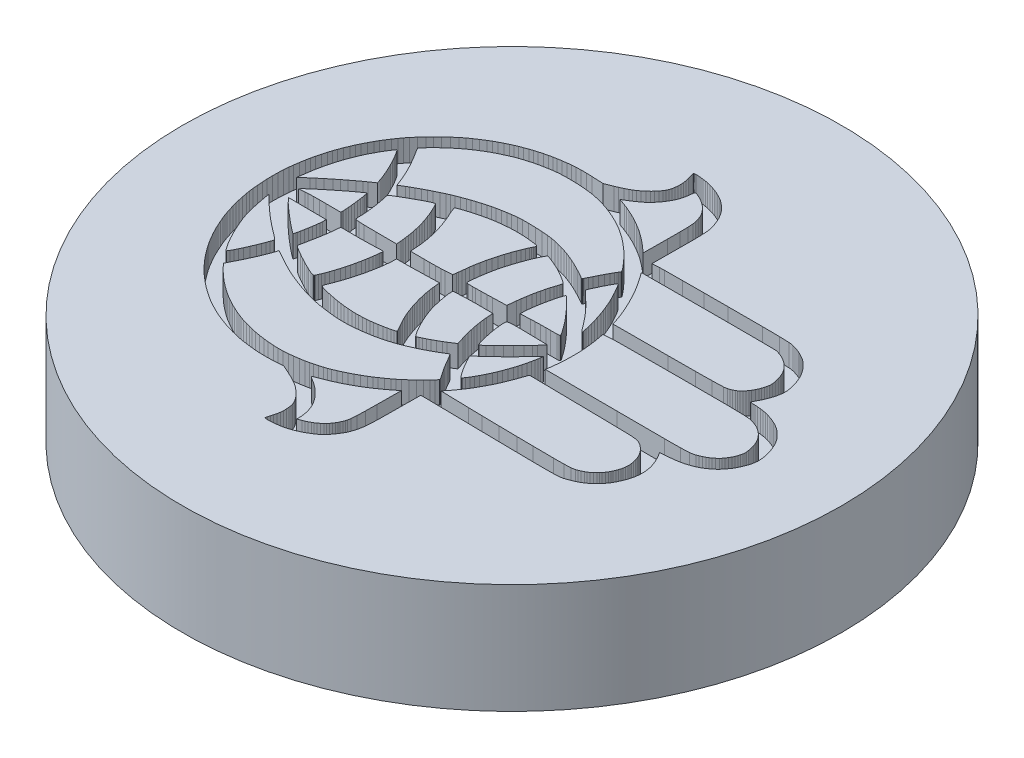
SolidWorks part; units mm, degrees
ref_plane "Front Plane" through (0, 0, 0) normal (0, 0, 1) x (1, 0, 0)
ref_plane "Top Plane" through (0, 0, 0) normal (0, 1, 0) x (1, 0, 0)
ref_plane "Right Plane" through (0, 0, 0) normal (1, 0, 0) x (0, 0, -1)
sketch "Sketch1" plane through (0, 0, 0) normal (0, 0, 1) x (1, 0, 0)
  line L0 (0, 0) -> (0, 2.5)
  line L1 (0, 2.5) -> (15, 2.5)
  line L4 (15, 2.5) -> (15, -2.5)
  line L7 (0, 0.5) -> (12, 0.5)
  line L10 (12, 0.5) -> (12, -2.5)
  line L13 (0, 0) -> (3, 0.5) construction
  line L14 (12, -2.5) -> (15, -2.5)
  point P0 (0, 0)
  point P6 (0, -2.5)
  dimension "D3" = 3
revolve "Revolve1" add sketch "Sketch1" angle 360 about L0 region at (8.8846, 0.9231, 0)
sketch "Sketch3" plane through (0, 2.5, 0) normal (0, 1, 0) x (1, 0, 0)
  line L9 (-2.1129, 7.0359) -> (-1.7906, 6.9176)
  line L10 (-1.8671, 7.1877) -> (-2.1129, 7.0359)
  line L11 (-1.6392, 7.3399) -> (-1.7595, 7.257)
  line L12 (-1.5248, 7.423) -> (-1.6392, 7.3399)
  line L13 (-0.5355, 8.9772) -> (-0.6114, 9.007)
  line L14 (-0.3487, 8.8919) -> (-0.4457, 8.9381)
  line L15 (0.5232, 6.5646) -> (0.5246, 7.1325)
  line L16 (0.5157, 5.4563) -> (0.5232, 6.5646)
  line L17 (6.1608, -1.375) -> (8.3181, -1.3815)
  line L18 (2.8744, -1.3629) -> (6.1608, -1.375)
  line L19 (2.8994, -1.2345) -> (2.8744, -1.3629)
  line L20 (-7.3955, 0.7842) -> (-7.3836, 0.6307)
  line L21 (2.1732, 1.3178) -> (2.1324, 1.4807)
  line L22 (2.2114, 1.1632) -> (2.1732, 1.3178)
  line L23 (2.2431, 1.0325) -> (2.2114, 1.1632)
  line L24 (2.2577, 0.9687) -> (2.2431, 1.0325)
  line L25 (2.0668, 1.1529) -> (2.1753, 1.0083)
  line L26 (1.8338, 1.4528) -> (1.9649, 1.2874)
  line L27 (1.6965, 1.621) -> (1.8338, 1.4528)
  line L28 (1.5743, 1.7652) -> (1.6965, 1.621)
  line L29 (0.7476, 2.8821) -> (0.6872, 2.7489)
  line L30 (0.8212, 3.0396) -> (0.7476, 2.8821)
  line L31 (0.906, 3.215) -> (0.8212, 3.0396)
  line L32 (0.9923, 3.3861) -> (0.906, 3.215)
  line L33 (1.1396, 3.6505) -> (1.0705, 3.5302)
  line L34 (1.2294, 3.5775) -> (1.1772, 3.6516)
  line L35 (1.4219, 3.2529) -> (1.353, 3.3765)
  line L36 (1.4959, 3.1166) -> (1.4219, 3.2529)
  line L37 (1.5641, 2.9882) -> (1.4959, 3.1166)
  line L38 (1.6135, 2.8914) -> (1.5641, 2.9882)
  line L39 (1.7303, 2.6314) -> (1.6624, 2.7873)
  line L40 (1.8035, 2.4571) -> (1.7303, 2.6314)
  line L41 (1.8716, 2.2882) -> (1.8035, 2.4571)
  line L42 (2.1732, 1.3178) -> (2.1324, 1.4807)
  line L43 (2.2114, 1.1632) -> (2.1732, 1.3178)
  line L44 (2.2431, 1.0325) -> (2.2114, 1.1632)
  line L45 (2.2577, 0.9687) -> (2.2431, 1.0325)
  line L46 (2.0668, 1.1529) -> (2.1753, 1.0083)
  line L47 (1.8338, 1.4528) -> (1.9649, 1.2874)
  line L48 (1.6965, 1.621) -> (1.8338, 1.4528)
  line L49 (1.5743, 1.7652) -> (1.6965, 1.621)
  line L50 (0.7476, 2.8821) -> (0.6872, 2.7489)
  line L51 (0.8212, 3.0396) -> (0.7476, 2.8821)
  line L52 (0.906, 3.215) -> (0.8212, 3.0396)
  line L53 (0.9923, 3.3861) -> (0.906, 3.215)
  line L54 (1.1396, 3.6505) -> (1.0705, 3.5302)
  line L55 (1.2294, 3.5775) -> (1.1772, 3.6516)
  line L56 (1.4219, 3.2529) -> (1.353, 3.3765)
  line L57 (1.4959, 3.1166) -> (1.4219, 3.2529)
  line L58 (1.5641, 2.9882) -> (1.4959, 3.1166)
  line L59 (1.6135, 2.8914) -> (1.5641, 2.9882)
  line L60 (1.7303, 2.6314) -> (1.6624, 2.7873)
  line L61 (1.8035, 2.4571) -> (1.7303, 2.6314)
  line L62 (1.8716, 2.2882) -> (1.8035, 2.4571)
  line L63 (-7.4128, 0.9547) -> (-7.3955, 0.7842)
  line L64 (-7.4579, 1.2821) -> (-7.4334, 1.1185)
  line L65 (-7.4865, 1.452) -> (-7.4579, 1.2821)
  line L66 (-7.5148, 1.6047) -> (-7.4865, 1.452)
  line L67 (-7.5132, 1.9568) -> (-7.5432, 1.9377)
  line L68 (-7.4255, 2.0096) -> (-7.5132, 1.9568)
  line L69 (-7.3208, 2.0722) -> (-7.4255, 2.0096)
  line L70 (-7.205, 2.1408) -> (-7.3208, 2.0722)
  line L71 (-7.067, 2.2207) -> (-7.205, 2.1408)
  line L72 (-6.8927, 2.3188) -> (-7.067, 2.2207)
  line L73 (-6.7123, 2.4183) -> (-6.8927, 2.3188)
  line L74 (-6.5543, 2.5034) -> (-6.7123, 2.4183)
  line L75 (-6.0802, 2.5492) -> (-6.1323, 2.6425)
  line L76 (-5.5144, 0.7928) -> (-5.5353, 0.9274)
  line L77 (-5.494, 0.6458) -> (-5.5144, 0.7928)
  line L78 (-5.477, 0.5082) -> (-5.494, 0.6458)
  line L79 (-5.4498, 0.1954) -> (-5.4669, 0.4058)
  line L80 (-6.3941, 0.2018) -> (-5.4498, 0.1954)
  line L81 (-6.934, 0.2072) -> (-6.3941, 0.2018)
  line L82 (-7.3955, 0.7842) -> (-7.3836, 0.6307)
  line L83 (-7.4128, 0.9547) -> (-7.3955, 0.7842)
  line L84 (-7.4579, 1.2821) -> (-7.4334, 1.1185)
  line L85 (-7.4865, 1.452) -> (-7.4579, 1.2821)
  line L86 (-7.5148, 1.6047) -> (-7.4865, 1.452)
  line L87 (-7.5132, 1.9568) -> (-7.5432, 1.9377)
  line L88 (-7.4255, 2.0096) -> (-7.5132, 1.9568)
  line L89 (-7.3208, 2.0722) -> (-7.4255, 2.0096)
  line L90 (-7.205, 2.1408) -> (-7.3208, 2.0722)
  line L91 (-7.067, 2.2207) -> (-7.205, 2.1408)
  line L92 (-6.8927, 2.3188) -> (-7.067, 2.2207)
  line L93 (-6.7123, 2.4183) -> (-6.8927, 2.3188)
  line L94 (-6.5543, 2.5034) -> (-6.7123, 2.4183)
  line L95 (-6.0802, 2.5492) -> (-6.1323, 2.6425)
  line L96 (-5.5144, 0.7928) -> (-5.5353, 0.9274)
  line L97 (-5.494, 0.6458) -> (-5.5144, 0.7928)
  line L98 (-5.477, 0.5082) -> (-5.494, 0.6458)
  line L99 (-5.4498, 0.1954) -> (-5.4669, 0.4058)
  line L100 (-6.3941, 0.2018) -> (-5.4498, 0.1954)
  line L101 (-6.934, 0.2072) -> (-6.3941, 0.2018)
  line L102 (2.9269, -1.0151) -> (2.911, -1.1595)
  line L103 (2.9432, -0.845) -> (2.9269, -1.0151)
  line L104 (2.9578, -0.6678) -> (2.9432, -0.845)
  line L105 (2.9299, 0.576) -> (2.9511, 0.3661)
  line L106 (2.9053, 0.7795) -> (2.9299, 0.576)
  line L107 (2.8578, 1.076) -> (2.8812, 0.9415)
  line L108 (2.8355, 1.1934) -> (2.8578, 1.076)
  line L109 (2.8154, 1.2931) -> (2.8355, 1.1934)
  line L110 (2.9388, 1.3364) -> (2.8128, 1.3238)
  line L111 (3.2765, 1.3563) -> (3.0917, 1.3477)
  line L112 (4.4351, 1.3686) -> (3.5923, 1.3633)
  line L113 (5.4405, 1.3723) -> (4.4351, 1.3686)
  line L114 (6.5403, 1.3734) -> (5.4405, 1.3723)
  line L115 (8.0757, 1.3711) -> (6.5403, 1.3734)
  line L116 (6.1608, -1.375) -> (8.3181, -1.3815)
  line L117 (2.8744, -1.3629) -> (6.1608, -1.375)
  line L118 (2.8994, -1.2345) -> (2.8744, -1.3629)
  line L119 (2.9269, -1.0151) -> (2.911, -1.1595)
  line L120 (2.9432, -0.845) -> (2.9269, -1.0151)
  line L121 (2.9578, -0.6678) -> (2.9432, -0.845)
  line L122 (2.9299, 0.576) -> (2.9511, 0.3661)
  line L123 (2.9053, 0.7795) -> (2.9299, 0.576)
  line L124 (2.8578, 1.076) -> (2.8812, 0.9415)
  line L125 (2.8355, 1.1934) -> (2.8578, 1.076)
  line L126 (2.8154, 1.2931) -> (2.8355, 1.1934)
  line L127 (2.9388, 1.3364) -> (2.8128, 1.3238)
  line L128 (3.2765, 1.3563) -> (3.0917, 1.3477)
  line L129 (4.4351, 1.3686) -> (3.5923, 1.3633)
  line L130 (5.4405, 1.3723) -> (4.4351, 1.3686)
  line L131 (6.5403, 1.3734) -> (5.4405, 1.3723)
  line L132 (8.0757, 1.3711) -> (6.5403, 1.3734)
  line L133 (0.2174, 5.7176) -> (0.5157, 5.4563)
  line L134 (-2.1129, 7.0359) -> (-1.7906, 6.9176)
  line L135 (-1.8671, 7.1877) -> (-2.1129, 7.0359)
  line L136 (-1.6392, 7.3399) -> (-1.7595, 7.257)
  line L137 (-1.5248, 7.423) -> (-1.6392, 7.3399)
  line L138 (-0.5355, 8.9772) -> (-0.6114, 9.007)
  line L139 (-0.3487, 8.8919) -> (-0.4457, 8.9381)
  line L140 (0.5232, 6.5646) -> (0.5246, 7.1325)
  line L141 (0.5157, 5.4563) -> (0.5232, 6.5646)
  line L142 (0.2174, 5.7176) -> (0.5157, 5.4563)
  line L143 (-0.8259, -8.9784) -> (-0.6415, -8.9098)
  line L144 (-0.8249, -8.8217) -> (-0.8259, -8.9784)
  line L145 (-2.1586, -6.977) -> (-2.1093, -7.0132)
  line L146 (-2.0794, -6.9161) -> (-2.1571, -6.9506)
  line L147 (-1.8731, -6.8372) -> (-1.9851, -6.8778)
  line L148 (-0.1194, -5.9022) -> (-0.2846, -6.0175)
  line L149 (0.0408, -5.7864) -> (-0.1194, -5.9022)
  line L150 (0.4413, -5.4757) -> (0.1686, -5.6894)
  line L151 (0.4305, -6.5823) -> (0.4413, -5.4757)
  line L152 (-0.8259, -8.9784) -> (-0.6415, -8.9098)
  line L153 (-0.8249, -8.8217) -> (-0.8259, -8.9784)
  line L154 (-2.1586, -6.977) -> (-2.1093, -7.0132)
  line L155 (-2.0794, -6.9161) -> (-2.1571, -6.9506)
  line L156 (-1.8731, -6.8372) -> (-1.9851, -6.8778)
  line L157 (-0.1194, -5.9022) -> (-0.2846, -6.0175)
  line L158 (0.0408, -5.7864) -> (-0.1194, -5.9022)
  line L159 (0.4413, -5.4757) -> (0.1686, -5.6894)
  line L160 (0.4305, -6.5823) -> (0.4413, -5.4757)
  line L165 (1.2471, 4.6392) -> (1.4217, 4.3956)
  line L166 (1.5022, 4.28) -> (1.6011, 4.1318)
  line L167 (1.6011, 4.1318) -> (1.7013, 3.9771)
  line L168 (0.5489, -0.3272) -> (0.3097, -0.3296)
  line L169 (0.8342, -0.3279) -> (0.5489, -0.3272)
  line L170 (1.1498, -0.3325) -> (0.8342, -0.3279)
  line L171 (1.9511, -0.3487) -> (1.1498, -0.3325)
  line L172 (1.7553, -0.585) -> (1.9511, -0.3487)
  line L173 (1.4511, -0.9154) -> (1.6444, -0.7111)
  line L174 (-2.1916, 3.2332) -> (-2.1741, 3.2727)
  line L175 (-2.2139, 3.1865) -> (-2.1916, 3.2332)
  line L176 (-2.2401, 3.1358) -> (-2.2139, 3.1865)
  line L177 (-2.3291, 2.9386) -> (-2.275, 3.064)
  line L178 (-2.3892, 2.7925) -> (-2.3291, 2.9386)
  line L179 (-2.4476, 2.6435) -> (-2.3892, 2.7925)
  line L180 (-2.5823, 2.2465) -> (-2.5098, 2.47)
  line L181 (-2.6531, 2.0125) -> (-2.5823, 2.2465)
  line L182 (-2.8967, 0.788) -> (-2.8783, 0.9459)
  line L183 (-2.9152, 0.6309) -> (-2.8967, 0.788)
  line L184 (-2.9314, 0.4942) -> (-2.9152, 0.6309)
  line L185 (-2.9414, 0.4123) -> (-2.9314, 0.4942)
  line L186 (-2.9602, 0.2623) -> (-2.9414, 0.4123)
  line L187 (-3.2936, 0.241) -> (-2.9602, 0.2623)
  line L188 (-3.7085, 0.2271) -> (-3.463, 0.233)
  line L189 (-3.9795, 0.2237) -> (-3.7085, 0.2271)
  line L190 (-4.2377, 0.2237) -> (-3.9795, 0.2237)
  line L191 (-4.8483, 0.2279) -> (-4.2377, 0.2237)
  line L192 (-4.8699, 0.548) -> (-4.8483, 0.2279)
  line L193 (-5.0431, 1.5468) -> (-4.996, 1.3621)
  line L194 (-5.0943, 1.7313) -> (-5.0431, 1.5468)
  line L195 (-5.267, 2.226) -> (-5.1956, 2.0399)
  line L196 (-5.3435, 2.4126) -> (-5.267, 2.226)
  line L197 (-5.4447, 2.9862) -> (-5.5237, 2.955)
  line L198 (-5.3496, 3.0213) -> (-5.4447, 2.9862)
  line L199 (-5.2422, 3.0581) -> (-5.3496, 3.0213)
  line L200 (-5.1158, 3.0981) -> (-5.2422, 3.0581)
  line L201 (-4.962, 3.1433) -> (-5.1158, 3.0981)
  line L202 (-4.8064, 3.1865) -> (-4.962, 3.1433)
  line L203 (-4.6743, 3.2204) -> (-4.8064, 3.1865)
  line L204 (-4.545, 3.2507) -> (-4.6743, 3.2204)
  line L205 (-4.3987, 3.2825) -> (-4.545, 3.2507)
  line L206 (-4.2579, 3.3113) -> (-4.3987, 3.2825)
  line L207 (-4.1476, 3.3317) -> (-4.2579, 3.3113)
  line L208 (-3.8685, 3.3682) -> (-4.0312, 3.349)
  line L209 (-3.6913, 3.3863) -> (-3.8685, 3.3682)
  line L210 (-3.5254, 3.4002) -> (-3.6913, 3.3863)
  line L211 (-2.5514, 3.3762) -> (-2.7169, 3.3919)
  line L212 (-2.4014, 3.3597) -> (-2.5514, 3.3762)
  line L213 (-2.2761, 3.3439) -> (-2.4014, 3.3597)
  line L214 (-2.1916, 3.2332) -> (-2.1741, 3.2727)
  line L215 (-2.2139, 3.1865) -> (-2.1916, 3.2332)
  line L216 (-2.2401, 3.1358) -> (-2.2139, 3.1865)
  line L217 (-2.3291, 2.9386) -> (-2.275, 3.064)
  line L218 (-2.3892, 2.7925) -> (-2.3291, 2.9386)
  line L219 (-2.4476, 2.6435) -> (-2.3892, 2.7925)
  line L220 (-2.5823, 2.2465) -> (-2.5098, 2.47)
  line L221 (-2.6531, 2.0125) -> (-2.5823, 2.2465)
  line L222 (-2.8967, 0.788) -> (-2.8783, 0.9459)
  line L223 (-2.9152, 0.6309) -> (-2.8967, 0.788)
  line L224 (-2.9314, 0.4942) -> (-2.9152, 0.6309)
  line L225 (-2.9414, 0.4123) -> (-2.9314, 0.4942)
  line L226 (-2.9602, 0.2623) -> (-2.9414, 0.4123)
  line L227 (-3.2936, 0.241) -> (-2.9602, 0.2623)
  line L228 (-3.7085, 0.2271) -> (-3.463, 0.233)
  line L229 (-3.9795, 0.2237) -> (-3.7085, 0.2271)
  line L230 (-4.2377, 0.2237) -> (-3.9795, 0.2237)
  line L231 (-4.8483, 0.2279) -> (-4.2377, 0.2237)
  line L232 (-4.8699, 0.548) -> (-4.8483, 0.2279)
  line L233 (-5.0431, 1.5468) -> (-4.996, 1.3621)
  line L234 (-5.0943, 1.7313) -> (-5.0431, 1.5468)
  line L235 (-5.267, 2.226) -> (-5.1956, 2.0399)
  line L236 (-5.3435, 2.4126) -> (-5.267, 2.226)
  line L237 (-5.4447, 2.9862) -> (-5.5237, 2.955)
  line L238 (-5.3496, 3.0213) -> (-5.4447, 2.9862)
  line L239 (-5.2422, 3.0581) -> (-5.3496, 3.0213)
  line L240 (-5.1158, 3.0981) -> (-5.2422, 3.0581)
  line L241 (-4.962, 3.1433) -> (-5.1158, 3.0981)
  line L242 (-4.8064, 3.1865) -> (-4.962, 3.1433)
  line L243 (-4.6743, 3.2204) -> (-4.8064, 3.1865)
  line L244 (-4.545, 3.2507) -> (-4.6743, 3.2204)
  line L245 (-4.3987, 3.2825) -> (-4.545, 3.2507)
  line L246 (-4.2579, 3.3113) -> (-4.3987, 3.2825)
  line L247 (-4.1476, 3.3317) -> (-4.2579, 3.3113)
  line L248 (-3.8685, 3.3682) -> (-4.0312, 3.349)
  line L249 (-3.6913, 3.3863) -> (-3.8685, 3.3682)
  line L250 (-3.5254, 3.4002) -> (-3.6913, 3.3863)
  line L251 (-2.5514, 3.3762) -> (-2.7169, 3.3919)
  line L252 (-2.4014, 3.3597) -> (-2.5514, 3.3762)
  line L253 (-2.2761, 3.3439) -> (-2.4014, 3.3597)
  line L254 (1.2252, -1.1474) -> (1.4511, -0.9154)
  line L255 (0.9946, -1.3777) -> (1.2252, -1.1474)
  line L256 (0.7756, -1.5895) -> (0.9946, -1.3777)
  line L257 (0.4205, -1.9115) -> (0.5859, -1.7645)
  line L258 (0.3505, -1.81) -> (0.3809, -1.8939)
  line L259 (0.2145, -1.2852) -> (0.2508, -1.452)
  line L260 (0.1812, -1.1176) -> (0.2145, -1.2852)
  line L261 (0.1385, -0.8461) -> (0.157, -0.9765)
  line L262 (0.1231, -0.7115) -> (0.1385, -0.8461)
  line L263 (0.1123, -0.5912) -> (0.1231, -0.7115)
  line L264 (0.5489, -0.3272) -> (0.3097, -0.3296)
  line L265 (0.8342, -0.3279) -> (0.5489, -0.3272)
  line L266 (1.1498, -0.3325) -> (0.8342, -0.3279)
  line L267 (1.9511, -0.3487) -> (1.1498, -0.3325)
  line L268 (1.7553, -0.585) -> (1.9511, -0.3487)
  line L269 (1.4511, -0.9154) -> (1.6444, -0.7111)
  line L270 (1.2252, -1.1474) -> (1.4511, -0.9154)
  line L271 (0.9946, -1.3777) -> (1.2252, -1.1474)
  line L272 (0.7756, -1.5895) -> (0.9946, -1.3777)
  line L273 (0.4205, -1.9115) -> (0.5859, -1.7645)
  line L274 (0.3505, -1.81) -> (0.3809, -1.8939)
  line L275 (0.2145, -1.2852) -> (0.2508, -1.452)
  line L276 (0.1812, -1.1176) -> (0.2145, -1.2852)
  line L277 (0.1385, -0.8461) -> (0.157, -0.9765)
  line L278 (0.1231, -0.7115) -> (0.1385, -0.8461)
  line L279 (0.1123, -0.5912) -> (0.1231, -0.7115)
  line L280 (1.7013, 3.9771) -> (1.787, 3.8398)
  line L281 (1.8757, 3.6877) -> (1.9865, 3.4838)
  line L282 (1.9865, 3.4838) -> (2.1, 3.2658)
  line L283 (2.5253, 2.2849) -> (2.6313, 1.9648)
  line L284 (2.6313, 1.9648) -> (5.1182, 1.9713)
  line L285 (5.1182, 1.9713) -> (6.3833, 1.9767)
  line L286 (7.2949, 4.6369) -> (6.4216, 4.6429)
  line L287 (6.4216, 4.6429) -> (5.4173, 4.6466)
  line L288 (5.4173, 4.6466) -> (4.254, 4.6459)
  line L289 (4.254, 4.6459) -> (1.2471, 4.6392)
  line L290 (1.2471, 4.6392) -> (1.4217, 4.3956)
  line L291 (1.5022, 4.28) -> (1.6011, 4.1318)
  line L292 (1.6011, 4.1318) -> (1.7013, 3.9771)
  line L293 (-6.8219, -2.6178) -> (-6.6158, -2.7229)
  line L294 (-7.0366, -2.5035) -> (-6.8219, -2.6178)
  line L295 (-7.4862, -2.2451) -> (-7.2268, -2.397)
  line L296 (-7.6265, -1.9987) -> (-7.6388, -2.0571)
  line L297 (-7.5974, -1.8532) -> (-7.6265, -1.9987)
  line L298 (-7.5629, -1.6795) -> (-7.5974, -1.8532)
  line L299 (-7.5259, -1.491) -> (-7.5629, -1.6795)
  line L300 (-7.4883, -1.2872) -> (-7.5259, -1.491)
  line L301 (-7.4522, -1.0671) -> (-7.4883, -1.2872)
  line L302 (-7.4223, -0.8632) -> (-7.4522, -1.0671)
  line L303 (-7.3775, -0.4132) -> (-7.4053, -0.7147)
  line L304 (-6.7697, -0.4171) -> (-7.3775, -0.4132)
  line L305 (-6.5108, -0.4171) -> (-6.7697, -0.4171)
  line L306 (-6.2356, -0.4137) -> (-6.5108, -0.4171)
  line L307 (-5.9837, -0.4078) -> (-6.2356, -0.4137)
  line L308 (-5.6136, -0.3904) -> (-5.8052, -0.3999)
  line L309 (-5.4635, -0.509) -> (-5.4583, -0.4586)
  line L310 (-5.4693, -0.5676) -> (-5.4635, -0.509)
  line L311 (-5.475, -0.6273) -> (-5.4693, -0.5676)
  line L312 (-5.5016, -0.8325) -> (-5.4839, -0.7058)
  line L313 (-5.5234, -0.9769) -> (-5.5016, -0.8325)
  line L314 (-5.5467, -1.1205) -> (-5.5234, -0.9769)
  line L315 (-5.6201, -1.4844) -> (-5.5769, -1.2823)
  line L316 (-5.6685, -1.6919) -> (-5.6201, -1.4844)
  line L317 (-5.8258, -2.2426) -> (-5.7652, -2.0481)
  line L318 (-5.8869, -2.4262) -> (-5.8258, -2.2426)
  line L319 (-5.9838, -2.6796) -> (-5.9381, -2.5654)
  line L320 (-6.0274, -2.7838) -> (-5.9838, -2.6796)
  line L321 (-6.0653, -2.8705) -> (-6.0274, -2.7838)
  line L322 (-6.8219, -2.6178) -> (-6.6158, -2.7229)
  line L323 (-7.0366, -2.5035) -> (-6.8219, -2.6178)
  line L324 (-7.4862, -2.2451) -> (-7.2268, -2.397)
  line L325 (-7.6265, -1.9987) -> (-7.6388, -2.0571)
  line L326 (-7.5974, -1.8532) -> (-7.6265, -1.9987)
  line L327 (-7.5629, -1.6795) -> (-7.5974, -1.8532)
  line L328 (-7.5259, -1.491) -> (-7.5629, -1.6795)
  line L329 (-7.4883, -1.2872) -> (-7.5259, -1.491)
  line L330 (-7.4522, -1.0671) -> (-7.4883, -1.2872)
  line L331 (-7.4223, -0.8632) -> (-7.4522, -1.0671)
  line L332 (-7.3775, -0.4132) -> (-7.4053, -0.7147)
  line L333 (-6.7697, -0.4171) -> (-7.3775, -0.4132)
  line L334 (-6.5108, -0.4171) -> (-6.7697, -0.4171)
  line L335 (-6.2356, -0.4137) -> (-6.5108, -0.4171)
  line L336 (-5.9837, -0.4078) -> (-6.2356, -0.4137)
  line L337 (-5.6136, -0.3904) -> (-5.8052, -0.3999)
  line L338 (-5.4635, -0.509) -> (-5.4583, -0.4586)
  line L339 (-5.4693, -0.5676) -> (-5.4635, -0.509)
  line L340 (-5.475, -0.6273) -> (-5.4693, -0.5676)
  line L341 (-5.5016, -0.8325) -> (-5.4839, -0.7058)
  line L342 (-5.5234, -0.9769) -> (-5.5016, -0.8325)
  line L343 (-5.5467, -1.1205) -> (-5.5234, -0.9769)
  line L344 (-5.6201, -1.4844) -> (-5.5769, -1.2823)
  line L345 (-5.6685, -1.6919) -> (-5.6201, -1.4844)
  line L346 (-5.8258, -2.2426) -> (-5.7652, -2.0481)
  line L347 (-5.8869, -2.4262) -> (-5.8258, -2.2426)
  line L348 (-5.9838, -2.6796) -> (-5.9381, -2.5654)
  line L349 (-6.0274, -2.7838) -> (-5.9838, -2.6796)
  line L350 (-6.0653, -2.8705) -> (-6.0274, -2.7838)
  line L351 (1.7013, 3.9771) -> (1.787, 3.8398)
  line L352 (1.8757, 3.6877) -> (1.9865, 3.4838)
  line L353 (1.9865, 3.4838) -> (2.1, 3.2658)
  line L354 (2.5253, 2.2849) -> (2.6313, 1.9648)
  line L355 (2.6313, 1.9648) -> (5.1182, 1.9713)
  line L356 (5.1182, 1.9713) -> (6.3833, 1.9767)
  line L357 (7.2949, 4.6369) -> (6.4216, 4.6429)
  line L358 (6.4216, 4.6429) -> (5.4173, 4.6466)
  line L359 (5.4173, 4.6466) -> (4.254, 4.6459)
  line L360 (4.254, 4.6459) -> (1.2471, 4.6392)
  line L365 (-8.3733, -1.6402) -> (-8.2083, -1.7597)
  line L366 (-8.6191, -1.4459) -> (-8.4638, -1.5713)
  line L367 (0.2286, 1.2426) -> (0.1939, 1.0585)
  line L368 (0.2695, 1.4379) -> (0.2286, 1.2426)
  line L369 (0.3101, 1.6163) -> (0.2695, 1.4379)
  line L370 (0.3727, 1.8399) -> (0.3433, 1.7422)
  line L371 (0.401, 1.9257) -> (0.3727, 1.8399)
  line L372 (0.4264, 1.9971) -> (0.401, 1.9257)
  line L373 (0.5727, 1.9057) -> (0.4545, 2.0149)
  line L374 (0.8671, 1.614) -> (0.7092, 1.7742)
  line L375 (1.6626, 0.6662) -> (1.5532, 0.8157)
  line L376 (1.7612, 0.5282) -> (1.6626, 0.6662)
  line L377 (1.8425, 0.4118) -> (1.7612, 0.5282)
  line L378 (1.4567, 0.2947) -> (1.7518, 0.294)
  line L379 (1.2512, 0.2944) -> (1.4567, 0.2947)
  line L380 (1.0064, 0.2907) -> (1.2512, 0.2944)
  line L381 (0.7623, 0.2847) -> (1.0064, 0.2907)
  line L382 (0.5593, 0.2769) -> (0.7623, 0.2847)
  line L383 (0.1146, 0.256) -> (0.5593, 0.2769)
  line L384 (0.1159, 0.4408) -> (0.1146, 0.256)
  line L385 (0.1393, 0.6985) -> (0.1212, 0.5398)
  line L386 (0.2286, 1.2426) -> (0.1939, 1.0585)
  line L387 (0.2695, 1.4379) -> (0.2286, 1.2426)
  line L388 (0.3101, 1.6163) -> (0.2695, 1.4379)
  line L389 (0.3727, 1.8399) -> (0.3433, 1.7422)
  line L390 (0.401, 1.9257) -> (0.3727, 1.8399)
  line L391 (0.4264, 1.9971) -> (0.401, 1.9257)
  line L392 (0.5727, 1.9057) -> (0.4545, 2.0149)
  line L393 (0.8671, 1.614) -> (0.7092, 1.7742)
  line L394 (1.6626, 0.6662) -> (1.5532, 0.8157)
  line L395 (1.7612, 0.5282) -> (1.6626, 0.6662)
  line L396 (1.8425, 0.4118) -> (1.7612, 0.5282)
  line L397 (1.4567, 0.2947) -> (1.7518, 0.294)
  line L398 (1.2512, 0.2944) -> (1.4567, 0.2947)
  line L399 (-8.0114, 3.1347) -> (-7.9333, 2.9607)
  line L400 (-7.8755, 2.8214) -> (-7.758, 2.5227)
  line L401 (-7.758, 2.5227) -> (-7.5218, 2.6651)
  line L402 (-7.403, 2.7344) -> (-7.2346, 2.8282)
  line L403 (-7.2346, 2.8282) -> (-7.05, 2.9285)
  line L404 (-7.05, 2.9285) -> (-6.8759, 3.0205)
  line L405 (-6.8759, 3.0205) -> (-6.6962, 3.1116)
  line L406 (-6.6962, 3.1116) -> (-6.4949, 3.2093)
  line L407 (-6.4949, 3.2093) -> (-6.3028, 3.299)
  line L408 (-6.1544, 3.3641) -> (-6.0089, 3.423)
  line L409 (-6.0089, 3.423) -> (-5.8274, 3.4927)
  line L410 (-5.8274, 3.4927) -> (-5.6409, 3.5616)
  line L411 (-5.6409, 3.5616) -> (-5.479, 3.6185)
  line L412 (-5.3143, 3.6722) -> (-5.1191, 3.7312)
  line L413 (-5.1191, 3.7312) -> (-4.925, 3.7865)
  line L414 (-4.5999, 3.8655) -> (-4.393, 3.9062)
  line L415 (-4.393, 3.9062) -> (-4.1793, 3.9442)
  line L416 (-0.4531, 3.36) -> (-0.2975, 3.2786)
  line L417 (-0.2975, 3.2786) -> (-0.1494, 3.1993)
  line L418 (-0.1494, 3.1993) -> (-0.0244, 3.1309)
  line L419 (0.1757, 3.1114) -> (0.2372, 3.237)
  line L420 (0.2372, 3.237) -> (0.3108, 3.385)
  line L421 (0.3108, 3.385) -> (0.3946, 3.5513)
  line L422 (0.3946, 3.5513) -> (0.4825, 3.7218)
  line L423 (0.4825, 3.7218) -> (0.5684, 3.8832)
  line L424 (0.5684, 3.8832) -> (0.6431, 4.0188)
  line L425 (0.753, 4.2547) -> (0.6794, 4.351)
  line L426 (0.5892, 4.4629) -> (0.4818, 4.5887)
  line L427 (0.2129, 4.8791) -> (0.0727, 5.0204)
  line L428 (-0.0393, 5.1257) -> (-0.147, 5.2205)
  line L429 (-0.147, 5.2205) -> (-0.272, 5.3271)
  line L430 (-0.272, 5.3271) -> (-0.3946, 5.4289)
  line L431 (-0.3946, 5.4289) -> (-0.4939, 5.5083)
  line L432 (-0.5942, 5.5836) -> (-0.7199, 5.6729)
  line L433 (-0.7199, 5.6729) -> (-0.8497, 5.7612)
  line L434 (-1.0839, 5.9064) -> (-1.2393, 5.9927)
  line L435 (-1.2393, 5.9927) -> (-1.4016, 6.0787)
  line L436 (-1.6924, 6.2177) -> (-1.862, 6.29)
  line L437 (-1.862, 6.29) -> (-2.0279, 6.3564)
  line L438 (-2.2969, 6.4477) -> (-2.4679, 6.4963)
  line L439 (-2.4679, 6.4963) -> (-2.645, 6.5428)
  line L440 (-6.2936, 6.2499) -> (-6.4743, 6.1692)
  line L441 (-6.4743, 6.1692) -> (-6.664, 6.0803)
  line L442 (-8.3832, 4.8516) -> (-8.5212, 4.7112)
  line L443 (-8.6376, 4.5876) -> (-8.7352, 4.4801)
  line L444 (-8.7378, 4.4365) -> (-8.6864, 4.3462)
  line L445 (-8.6864, 4.3462) -> (-8.6234, 4.2406)
  line L446 (-8.6234, 4.2406) -> (-8.5487, 4.1216)
  line L447 (-8.461, 3.98) -> (-8.358, 3.8043)
  line L448 (-8.358, 3.8043) -> (-8.2565, 3.6243)
  line L449 (-8.0957, 3.3134) -> (-8.0114, 3.1347)
  line L450 (-8.0114, 3.1347) -> (-7.9333, 2.9607)
  line L451 (-7.8755, 2.8214) -> (-7.758, 2.5227)
  line L452 (-7.758, 2.5227) -> (-7.5218, 2.6651)
  line L453 (-7.403, 2.7344) -> (-7.2346, 2.8282)
  line L454 (-7.2346, 2.8282) -> (-7.05, 2.9285)
  line L455 (-7.05, 2.9285) -> (-6.8759, 3.0205)
  line L456 (-6.8759, 3.0205) -> (-6.6962, 3.1116)
  line L457 (-6.6962, 3.1116) -> (-6.4949, 3.2093)
  line L458 (-6.4949, 3.2093) -> (-6.3028, 3.299)
  line L459 (-6.1544, 3.3641) -> (-6.0089, 3.423)
  line L460 (-6.0089, 3.423) -> (-5.8274, 3.4927)
  line L461 (-5.8274, 3.4927) -> (-5.6409, 3.5616)
  line L462 (-5.6409, 3.5616) -> (-5.479, 3.6185)
  line L463 (-5.3143, 3.6722) -> (-5.1191, 3.7312)
  line L464 (-5.1191, 3.7312) -> (-4.925, 3.7865)
  line L465 (-4.5999, 3.8655) -> (-4.393, 3.9062)
  line L466 (-4.393, 3.9062) -> (-4.1793, 3.9442)
  line L467 (-0.4531, 3.36) -> (-0.2975, 3.2786)
  line L468 (-0.2975, 3.2786) -> (-0.1494, 3.1993)
  line L469 (-0.1494, 3.1993) -> (-0.0244, 3.1309)
  line L470 (0.1757, 3.1114) -> (0.2372, 3.237)
  line L471 (0.2372, 3.237) -> (0.3108, 3.385)
  line L472 (0.3108, 3.385) -> (0.3946, 3.5513)
  line L473 (0.3946, 3.5513) -> (0.4825, 3.7218)
  line L474 (0.4825, 3.7218) -> (0.5684, 3.8832)
  line L475 (0.5684, 3.8832) -> (0.6431, 4.0188)
  line L476 (0.753, 4.2547) -> (0.6794, 4.351)
  line L477 (0.5892, 4.4629) -> (0.4818, 4.5887)
  line L478 (0.2129, 4.8791) -> (0.0727, 5.0204)
  line L479 (-0.0393, 5.1257) -> (-0.147, 5.2205)
  line L480 (-0.147, 5.2205) -> (-0.272, 5.3271)
  line L481 (-0.272, 5.3271) -> (-0.3946, 5.4289)
  line L482 (-0.3946, 5.4289) -> (-0.4939, 5.5083)
  line L483 (-0.5942, 5.5836) -> (-0.7199, 5.6729)
  line L484 (-0.7199, 5.6729) -> (-0.8497, 5.7612)
  line L485 (-1.0839, 5.9064) -> (-1.2393, 5.9927)
  line L486 (-1.2393, 5.9927) -> (-1.4016, 6.0787)
  line L487 (-1.6924, 6.2177) -> (-1.862, 6.29)
  line L488 (-1.862, 6.29) -> (-2.0279, 6.3564)
  line L489 (-2.2969, 6.4477) -> (-2.4679, 6.4963)
  line L490 (-2.4679, 6.4963) -> (-2.645, 6.5428)
  line L491 (-6.2936, 6.2499) -> (-6.4743, 6.1692)
  line L492 (-6.4743, 6.1692) -> (-6.664, 6.0803)
  line L493 (-8.3832, 4.8516) -> (-8.5212, 4.7112)
  line L494 (-8.6376, 4.5876) -> (-8.7352, 4.4801)
  line L495 (-8.7378, 4.4365) -> (-8.6864, 4.3462)
  line L496 (-8.6864, 4.3462) -> (-8.6234, 4.2406)
  line L497 (-8.6234, 4.2406) -> (-8.5487, 4.1216)
  line L498 (-8.461, 3.98) -> (-8.358, 3.8043)
  line L499 (-8.358, 3.8043) -> (-8.2565, 3.6243)
  line L500 (-8.0957, 3.3134) -> (-8.0114, 3.1347)
  line L501 (1.0064, 0.2907) -> (1.2512, 0.2944)
  line L502 (0.7623, 0.2847) -> (1.0064, 0.2907)
  line L503 (0.5593, 0.2769) -> (0.7623, 0.2847)
  line L504 (0.1146, 0.256) -> (0.5593, 0.2769)
  line L505 (0.1159, 0.4408) -> (0.1146, 0.256)
  line L506 (0.1393, 0.6985) -> (0.1212, 0.5398)
  line L507 (-8.7979, -1.2986) -> (-8.6191, -1.4459)
  line L508 (-8.9786, -1.1466) -> (-8.7979, -1.2986)
  line L509 (-9.1591, -0.9909) -> (-8.9786, -1.1466)
  line L510 (-9.3372, -0.8326) -> (-9.1591, -0.9909)
  line L511 (-9.4906, -0.6921) -> (-9.3372, -0.8326)
  line L512 (-9.7428, -0.4337) -> (-9.5809, -0.6031)
  line L513 (-8.0089, -0.4455) -> (-9.7428, -0.4337)
  line L514 (-8.0135, -0.6191) -> (-8.0089, -0.4455)
  line L515 (-8.0368, -0.8545) -> (-8.0196, -0.7109)
  line L516 (-8.0599, -1.0168) -> (-8.0368, -0.8545)
  line L517 (-8.0864, -1.1764) -> (-8.0599, -1.0168)
  line L518 (-8.1145, -1.3305) -> (-8.0864, -1.1764)
  line L519 (-8.1425, -1.4766) -> (-8.1145, -1.3305)
  line L520 (-8.1674, -1.5998) -> (-8.1425, -1.4766)
  line L521 (-2.2451, 1.0697) -> (-2.2737, 0.8905)
  line L522 (-2.2941, 0.7408) -> (-2.3094, 0.6088)
  line L523 (-2.3094, 0.6088) -> (-2.3225, 0.4843)
  line L524 (-2.3225, 0.4843) -> (-2.3324, 0.3793)
  line L525 (-2.2297, 0.2485) -> (-2.0523, 0.2455)
  line L526 (-2.0523, 0.2455) -> (-1.9026, 0.2461)
  line L527 (-1.9026, 0.2461) -> (-1.6688, 0.25)
  line L528 (-1.6688, 0.25) -> (-1.4045, 0.2558)
  line L529 (-1.4045, 0.2558) -> (-1.1447, 0.2631)
  line L530 (-1.1447, 0.2631) -> (-0.5206, 0.2826)
  line L531 (-0.5206, 0.2826) -> (-0.477, 0.6882)
  line L532 (-0.4546, 0.87) -> (-0.4231, 1.0819)
  line L533 (-0.4231, 1.0819) -> (-0.3881, 1.29)
  line L534 (-0.3183, 1.6188) -> (-0.2731, 1.7973)
  line L535 (-0.2731, 1.7973) -> (-0.2268, 1.9671)
  line L536 (-0.187, 2.0978) -> (-0.1525, 2.2054)
  line L537 (-0.1525, 2.2054) -> (-0.1228, 2.3021)
  line L538 (-0.1228, 2.3021) -> (-0.0987, 2.3836)
  line L539 (-0.3357, 2.5985) -> (-0.4437, 2.664)
  line L540 (-0.4437, 2.664) -> (-0.5649, 2.7345)
  line L541 (-0.5649, 2.7345) -> (-0.6809, 2.7996)
  line L542 (-0.8627, 2.8919) -> (-0.9856, 2.9479)
  line L543 (-0.9856, 2.9479) -> (-1.1168, 3.0054)
  line L544 (-1.1168, 3.0054) -> (-1.2365, 3.0553)
  line L545 (-1.2365, 3.0553) -> (-1.344, 3.0983)
  line L546 (-1.344, 3.0983) -> (-1.4377, 3.1345)
  line L547 (-1.4377, 3.1345) -> (-1.5186, 3.1649)
  line L548 (-1.5439, 3.1611) -> (-1.5883, 3.0793)
  line L549 (-1.6383, 2.9822) -> (-1.6939, 2.8669)
  line L550 (-1.7579, 2.722) -> (-1.8344, 2.5314)
  line L551 (-2.032, 1.9625) -> (-2.0924, 1.7543)
  line L552 (-2.0924, 1.7543) -> (-2.1463, 1.5545)
  line L553 (-2.2133, 1.2489) -> (-2.2451, 1.0697)
  line L554 (-2.2451, 1.0697) -> (-2.2737, 0.8905)
  line L555 (-2.2941, 0.7408) -> (-2.3094, 0.6088)
  line L556 (-2.3094, 0.6088) -> (-2.3225, 0.4843)
  line L557 (-2.3225, 0.4843) -> (-2.3324, 0.3793)
  line L558 (-2.2297, 0.2485) -> (-2.0523, 0.2455)
  line L559 (-2.0523, 0.2455) -> (-1.9026, 0.2461)
  line L560 (-1.9026, 0.2461) -> (-1.6688, 0.25)
  line L561 (-1.6688, 0.25) -> (-1.4045, 0.2558)
  line L562 (-1.4045, 0.2558) -> (-1.1447, 0.2631)
  line L563 (-1.1447, 0.2631) -> (-0.5206, 0.2826)
  line L564 (-0.5206, 0.2826) -> (-0.477, 0.6882)
  line L565 (-0.4546, 0.87) -> (-0.4231, 1.0819)
  line L566 (-0.4231, 1.0819) -> (-0.3881, 1.29)
  line L567 (-0.3183, 1.6188) -> (-0.2731, 1.7973)
  line L568 (-0.2731, 1.7973) -> (-0.2268, 1.9671)
  line L569 (-0.187, 2.0978) -> (-0.1525, 2.2054)
  line L570 (-0.1525, 2.2054) -> (-0.1228, 2.3021)
  line L571 (-0.1228, 2.3021) -> (-0.0987, 2.3836)
  line L572 (-0.3357, 2.5985) -> (-0.4437, 2.664)
  line L573 (-0.4437, 2.664) -> (-0.5649, 2.7345)
  line L574 (-0.5649, 2.7345) -> (-0.6809, 2.7996)
  line L575 (-0.8627, 2.8919) -> (-0.9856, 2.9479)
  line L576 (-0.9856, 2.9479) -> (-1.1168, 3.0054)
  line L577 (-1.1168, 3.0054) -> (-1.2365, 3.0553)
  line L578 (-1.2365, 3.0553) -> (-1.344, 3.0983)
  line L579 (-1.344, 3.0983) -> (-1.4377, 3.1345)
  line L580 (-1.4377, 3.1345) -> (-1.5186, 3.1649)
  line L581 (-1.5439, 3.1611) -> (-1.5883, 3.0793)
  line L582 (-1.6383, 2.9822) -> (-1.6939, 2.8669)
  line L583 (-1.7579, 2.722) -> (-1.8344, 2.5314)
  line L584 (-2.032, 1.9625) -> (-2.0924, 1.7543)
  line L585 (-2.0924, 1.7543) -> (-2.1463, 1.5545)
  line L586 (-2.2133, 1.2489) -> (-2.2451, 1.0697)
  line L587 (-8.2083, -1.7597) -> (-8.1815, -1.6598)
  line L588 (-8.3733, -1.6402) -> (-8.2083, -1.7597)
  line L589 (-8.6191, -1.4459) -> (-8.4638, -1.5713)
  line L590 (-8.7979, -1.2986) -> (-8.6191, -1.4459)
  line L591 (-8.9786, -1.1466) -> (-8.7979, -1.2986)
  line L592 (-9.1591, -0.9909) -> (-8.9786, -1.1466)
  line L593 (-9.3372, -0.8326) -> (-9.1591, -0.9909)
  line L594 (-9.4906, -0.6921) -> (-9.3372, -0.8326)
  line L595 (-9.7428, -0.4337) -> (-9.5809, -0.6031)
  line L596 (-8.0089, -0.4455) -> (-9.7428, -0.4337)
  line L597 (-8.0135, -0.6191) -> (-8.0089, -0.4455)
  line L598 (-8.0368, -0.8545) -> (-8.0196, -0.7109)
  line L599 (-8.0599, -1.0168) -> (-8.0368, -0.8545)
  line L600 (-8.0864, -1.1764) -> (-8.0599, -1.0168)
  line L601 (-8.1145, -1.3305) -> (-8.0864, -1.1764)
  line L602 (-8.1425, -1.4766) -> (-8.1145, -1.3305)
  line L603 (-8.1674, -1.5998) -> (-8.1425, -1.4766)
  line L604 (-8.2083, -1.7597) -> (-8.1815, -1.6598)
  line L608 (2.5461, -2.5258) -> (2.4644, -2.7319)
  line L609 (2.7488, -1.9525) -> (2.611, -2.3486)
  line L610 (4.9256, -1.9824) -> (2.7488, -1.9525)
  line L611 (5.7825, -1.9949) -> (4.9256, -1.9824)
  line L612 (6.5561, -2.0079) -> (5.7825, -1.9949)
  line L613 (7.2056, -2.0201) -> (6.5561, -2.0079)
  line L614 (8.4626, -3.7314) -> (8.4964, -3.6406)
  line L615 (8.4259, -3.821) -> (8.4626, -3.7314)
  line L616 (5.6241, -4.6658) -> (6.5628, -4.6729)
  line L617 (4.8848, -4.6572) -> (5.6241, -4.6658)
  line L618 (4.055, -4.645) -> (4.8848, -4.6572)
  line L619 (3.2623, -4.6313) -> (4.055, -4.645)
  line L620 (2.6482, -4.6181) -> (3.2623, -4.6313)
  line L621 (1.357, -4.5868) -> (2.6482, -4.6181)
  line L622 (1.5566, -4.3322) -> (1.357, -4.5868)
  line L623 (1.7536, -4.0602) -> (1.6467, -4.2122)
  line L624 (1.8594, -3.9024) -> (1.7536, -4.0602)
  line L625 (2.1309, -3.4386) -> (2.0321, -3.6182)
  line L626 (2.2274, -3.2551) -> (2.1309, -3.4386)
  line L627 (2.4644, -2.7319) -> (2.3797, -2.9337)
  line L628 (2.5461, -2.5258) -> (2.4644, -2.7319)
  line L629 (2.7488, -1.9525) -> (2.611, -2.3486)
  line L630 (4.9256, -1.9824) -> (2.7488, -1.9525)
  line L631 (5.7825, -1.9949) -> (4.9256, -1.9824)
  line L632 (6.5561, -2.0079) -> (5.7825, -1.9949)
  line L633 (7.2056, -2.0201) -> (6.5561, -2.0079)
  line L634 (8.4626, -3.7314) -> (8.4964, -3.6406)
  line L635 (8.4259, -3.821) -> (8.4626, -3.7314)
  line L636 (5.6241, -4.6658) -> (6.5628, -4.6729)
  line L637 (4.8848, -4.6572) -> (5.6241, -4.6658)
  line L638 (4.055, -4.645) -> (4.8848, -4.6572)
  line L639 (3.2623, -4.6313) -> (4.055, -4.645)
  line L640 (2.6482, -4.6181) -> (3.2623, -4.6313)
  line L641 (1.357, -4.5868) -> (2.6482, -4.6181)
  line L642 (1.5566, -4.3322) -> (1.357, -4.5868)
  line L643 (1.7536, -4.0602) -> (1.6467, -4.2122)
  line L644 (1.8594, -3.9024) -> (1.7536, -4.0602)
  line L645 (2.1309, -3.4386) -> (2.0321, -3.6182)
  line L646 (2.2274, -3.2551) -> (2.1309, -3.4386)
  line L647 (2.4644, -2.7319) -> (2.3797, -2.9337)
  line L648 (2.3157, -1.0115) -> (2.3303, -0.925)
  line L649 (2.2071, -1.0114) -> (2.1272, -1.0996)
  line L650 (2.0174, -1.2196) -> (1.8494, -1.3952)
  line L651 (1.8494, -1.3952) -> (1.6598, -1.589)
  line L652 (1.6598, -1.589) -> (1.4745, -1.7741)
  line L653 (1.4745, -1.7741) -> (1.2896, -1.9542)
  line L654 (1.2896, -1.9542) -> (1.1014, -2.133)
  line L655 (1.1014, -2.133) -> (0.9345, -2.2878)
  line L656 (0.8281, -2.3806) -> (0.6258, -2.5489)
  line L657 (0.6258, -2.5489) -> (0.7339, -2.7615)
  line L658 (0.7898, -2.8655) -> (0.8717, -3.0069)
  line L659 (0.8717, -3.0069) -> (0.9632, -3.1586)
  line L660 (0.9632, -3.1586) -> (1.0513, -3.2983)
  line L661 (1.326, -3.5913) -> (1.3895, -3.4982)
  line L662 (1.9476, -2.3792) -> (2.0166, -2.1885)
  line L663 (2.0166, -2.1885) -> (2.0805, -2.0012)
  line L664 (2.1681, -1.7022) -> (2.2109, -1.5314)
  line L665 (2.2109, -1.5314) -> (2.2495, -1.364)
  line L666 (2.277, -1.2286) -> (2.2977, -1.114)
  line L667 (2.2977, -1.114) -> (2.3157, -1.0115)
  line L668 (2.3157, -1.0115) -> (2.3303, -0.925)
  line L669 (2.2071, -1.0114) -> (2.1272, -1.0996)
  line L670 (2.0174, -1.2196) -> (1.8494, -1.3952)
  line L671 (1.8494, -1.3952) -> (1.6598, -1.589)
  line L672 (1.6598, -1.589) -> (1.4745, -1.7741)
  line L673 (1.4745, -1.7741) -> (1.2896, -1.9542)
  line L674 (1.2896, -1.9542) -> (1.1014, -2.133)
  line L675 (1.1014, -2.133) -> (0.9345, -2.2878)
  line L676 (0.8281, -2.3806) -> (0.6258, -2.5489)
  line L677 (0.6258, -2.5489) -> (0.7339, -2.7615)
  line L678 (0.7898, -2.8655) -> (0.8717, -3.0069)
  line L679 (0.8717, -3.0069) -> (0.9632, -3.1586)
  line L680 (0.9632, -3.1586) -> (1.0513, -3.2983)
  line L681 (1.326, -3.5913) -> (1.3895, -3.4982)
  line L682 (1.9476, -2.3792) -> (2.0166, -2.1885)
  line L683 (2.0166, -2.1885) -> (2.0805, -2.0012)
  line L684 (2.1681, -1.7022) -> (2.2109, -1.5314)
  line L685 (2.2109, -1.5314) -> (2.2495, -1.364)
  line L686 (2.277, -1.2286) -> (2.2977, -1.114)
  line L687 (2.2977, -1.114) -> (2.3157, -1.0115)
  line L691 (-10.2527, -1.115) -> (-10.2199, -1.2813)
  line L692 (-10.2795, -0.9722) -> (-10.2527, -1.115)
  line L693 (-2.3004, -0.5818) -> (-2.2842, -0.7054)
  line L694 (-2.3034, -0.3856) -> (-2.3043, -0.5115)
  line L695 (-1.9467, -0.3644) -> (-2.3034, -0.3856)
  line L696 (-1.5379, -0.3505) -> (-1.7727, -0.3565)
  line L697 (-1.2865, -0.3469) -> (-1.5379, -0.3505)
  line L698 (-1.0559, -0.3467) -> (-1.2865, -0.3469)
  line L699 (-0.5217, -0.3501) -> (-1.0559, -0.3467)
  line L700 (-0.4989, -0.652) -> (-0.5217, -0.3501)
  line L701 (-0.4618, -0.9718) -> (-0.485, -0.7935)
  line L702 (-0.4337, -1.1558) -> (-0.4618, -0.9718)
  line L703 (-0.3244, -1.6691) -> (-0.3701, -1.4794)
  line L704 (-0.2755, -1.8552) -> (-0.3244, -1.6691)
  line L705 (-0.1284, -2.3331) -> (-0.231, -2.0064)
  line L706 (-0.4284, -2.5251) -> (-0.1284, -2.3331)
  line L707 (-0.729, -2.7043) -> (-0.5652, -2.6094)
  line L708 (-0.8931, -2.7949) -> (-0.729, -2.7043)
  line L709 (-1.1481, -2.9226) -> (-1.0304, -2.8657)
  line L710 (-1.2519, -2.9705) -> (-1.1481, -2.9226)
  line L711 (-1.3408, -3.0098) -> (-1.2519, -2.9705)
  line L712 (-0.4288, -5.3689) -> (-0.2611, -5.2471)
  line L713 (-0.6002, -5.4892) -> (-0.4288, -5.3689)
  line L714 (-1.8168, -6.1557) -> (-1.6315, -6.0729)
  line L715 (-1.9917, -6.2296) -> (-1.8168, -6.1557)
  line L716 (-2.4244, -6.3733) -> (-2.2551, -6.3231)
  line L717 (-2.6019, -6.4222) -> (-2.4244, -6.3733)
  line L718 (-5.7472, -6.3464) -> (-5.5507, -6.4021)
  line L719 (-5.9385, -6.2878) -> (-5.7472, -6.3464)
  line L720 (-7.6893, -5.3647) -> (-7.5444, -5.4719)
  line L721 (-7.8322, -5.255) -> (-7.6893, -5.3647)
  line L722 (-8.1921, -4.9461) -> (-8.0625, -5.0635)
  line L723 (-8.3177, -4.8277) -> (-8.1921, -4.9461)
  line L724 (-8.6318, -4.5064) -> (-8.4179, -4.7277)
  line L725 (-8.3896, -4.0206) -> (-8.6318, -4.5064)
  line L726 (-8.1791, -3.5735) -> (-8.2871, -3.8087)
  line L727 (-8.0816, -3.3505) -> (-8.1791, -3.5735)
  line L728 (-7.9616, -3.0423) -> (-8.0131, -3.1807)
  line L729 (-7.9182, -2.9194) -> (-7.9616, -3.0423)
  line L730 (-7.8829, -2.815) -> (-7.9182, -2.9194)
  line L731 (-7.7285, -2.8158) -> (-7.8427, -2.7543)
  line L732 (-7.5979, -2.8875) -> (-7.7285, -2.8158)
  line L733 (-7.4469, -2.9726) -> (-7.5979, -2.8875)
  line L734 (-7.0591, -3.1799) -> (-7.2698, -3.0701)
  line L735 (-6.8491, -3.2846) -> (-7.0591, -3.1799)
  line L736 (-6.2657, -3.5347) -> (-6.4945, -3.4436)
  line L737 (-6.0279, -3.6245) -> (-6.2657, -3.5347)
  line L738 (-4.5256, -4.0078) -> (-4.7577, -3.9723)
  line L739 (-4.2875, -4.0395) -> (-4.5256, -4.0078)
  line L740 (-1.1341, -3.5771) -> (-1.3259, -3.6571)
  line L741 (-0.9415, -3.4922) -> (-1.1341, -3.5771)
  line L742 (-0.6246, -3.3374) -> (-0.7795, -3.4156)
  line L743 (-0.4542, -3.2477) -> (-0.6246, -3.3374)
  line L744 (-0.2942, -3.1604) -> (-0.4542, -3.2477)
  line L745 (-0.077, -3.0329) -> (-0.1739, -3.0909)
  line L746 (0.0084, -2.9818) -> (-0.077, -3.0329)
  line L747 (0.0811, -2.9384) -> (0.0084, -2.9818)
  line L748 (0.0979, -2.9286) -> (0.0811, -2.9384)
  line L749 (0.166, -3.0131) -> (0.112, -2.9319)
  line L750 (0.4782, -3.5416) -> (0.3783, -3.3772)
  line L751 (0.58, -3.7016) -> (0.4782, -3.5416)
  line L752 (0.7427, -3.9391) -> (0.6671, -3.8303)
  line L753 (0.8092, -4.0378) -> (0.7427, -3.9391)
  line L754 (0.8637, -4.1214) -> (0.8092, -4.0378)
  line L755 (0.7823, -4.2858) -> (0.8731, -4.1777)
  line L756 (-0.4288, -5.3689) -> (-0.2611, -5.2471)
  line L757 (-0.6002, -5.4892) -> (-0.4288, -5.3689)
  line L758 (-1.8168, -6.1557) -> (-1.6315, -6.0729)
  line L759 (-1.9917, -6.2296) -> (-1.8168, -6.1557)
  line L760 (-2.4244, -6.3733) -> (-2.2551, -6.3231)
  line L761 (-2.6019, -6.4222) -> (-2.4244, -6.3733)
  line L762 (-5.7472, -6.3464) -> (-5.5507, -6.4021)
  line L763 (-5.9385, -6.2878) -> (-5.7472, -6.3464)
  line L764 (-7.6893, -5.3647) -> (-7.5444, -5.4719)
  line L765 (-7.8322, -5.255) -> (-7.6893, -5.3647)
  line L766 (-8.1921, -4.9461) -> (-8.0625, -5.0635)
  line L767 (-8.3177, -4.8277) -> (-8.1921, -4.9461)
  line L768 (-8.6318, -4.5064) -> (-8.4179, -4.7277)
  line L769 (-8.3896, -4.0206) -> (-8.6318, -4.5064)
  line L770 (-8.1791, -3.5735) -> (-8.2871, -3.8087)
  line L771 (-8.0816, -3.3505) -> (-8.1791, -3.5735)
  line L772 (-7.9616, -3.0423) -> (-8.0131, -3.1807)
  line L773 (-7.9182, -2.9194) -> (-7.9616, -3.0423)
  line L774 (-7.8829, -2.815) -> (-7.9182, -2.9194)
  line L775 (-7.7285, -2.8158) -> (-7.8427, -2.7543)
  line L776 (-7.5979, -2.8875) -> (-7.7285, -2.8158)
  line L777 (-7.4469, -2.9726) -> (-7.5979, -2.8875)
  line L778 (-7.0591, -3.1799) -> (-7.2698, -3.0701)
  line L779 (-6.8491, -3.2846) -> (-7.0591, -3.1799)
  line L780 (-6.2657, -3.5347) -> (-6.4945, -3.4436)
  line L781 (-6.0279, -3.6245) -> (-6.2657, -3.5347)
  line L782 (-4.5256, -4.0078) -> (-4.7577, -3.9723)
  line L783 (-4.2875, -4.0395) -> (-4.5256, -4.0078)
  line L784 (-1.1341, -3.5771) -> (-1.3259, -3.6571)
  line L785 (-0.9415, -3.4922) -> (-1.1341, -3.5771)
  line L786 (-0.6246, -3.3374) -> (-0.7795, -3.4156)
  line L787 (-0.4542, -3.2477) -> (-0.6246, -3.3374)
  line L788 (-0.2942, -3.1604) -> (-0.4542, -3.2477)
  line L789 (-0.077, -3.0329) -> (-0.1739, -3.0909)
  line L790 (0.0084, -2.9818) -> (-0.077, -3.0329)
  line L791 (0.0811, -2.9384) -> (0.0084, -2.9818)
  line L792 (0.0979, -2.9286) -> (0.0811, -2.9384)
  line L793 (0.166, -3.0131) -> (0.112, -2.9319)
  line L794 (0.4782, -3.5416) -> (0.3783, -3.3772)
  line L795 (0.58, -3.7016) -> (0.4782, -3.5416)
  line L796 (0.7427, -3.9391) -> (0.6671, -3.8303)
  line L797 (0.8092, -4.0378) -> (0.7427, -3.9391)
  line L798 (0.8637, -4.1214) -> (0.8092, -4.0378)
  line L799 (0.7823, -4.2858) -> (0.8731, -4.1777)
  line L800 (-1.4201, -2.9509) -> (-1.3766, -3.006)
  line L801 (-1.666, -2.5537) -> (-1.5868, -2.6959)
  line L802 (-1.7474, -2.4006) -> (-1.666, -2.5537)
  line L803 (-2.1577, -1.3323) -> (-2.112, -1.5053)
  line L804 (-2.2011, -1.1527) -> (-2.1577, -1.3323)
  line L805 (-2.2617, -0.8487) -> (-2.2348, -0.9948)
  line L806 (-2.3004, -0.5818) -> (-2.2842, -0.7054)
  line L807 (-2.3034, -0.3856) -> (-2.3043, -0.5115)
  line L808 (-1.9467, -0.3644) -> (-2.3034, -0.3856)
  line L809 (-1.5379, -0.3505) -> (-1.7727, -0.3565)
  line L810 (-1.2865, -0.3469) -> (-1.5379, -0.3505)
  line L811 (-1.0559, -0.3467) -> (-1.2865, -0.3469)
  line L812 (-0.5217, -0.3501) -> (-1.0559, -0.3467)
  line L813 (-0.4989, -0.652) -> (-0.5217, -0.3501)
  line L814 (-0.4618, -0.9718) -> (-0.485, -0.7935)
  line L815 (-0.4337, -1.1558) -> (-0.4618, -0.9718)
  line L816 (-0.3244, -1.6691) -> (-0.3701, -1.4794)
  line L817 (-0.2755, -1.8552) -> (-0.3244, -1.6691)
  line L818 (-0.1284, -2.3331) -> (-0.231, -2.0064)
  line L819 (-0.4284, -2.5251) -> (-0.1284, -2.3331)
  line L820 (-0.729, -2.7043) -> (-0.5652, -2.6094)
  line L821 (-0.8931, -2.7949) -> (-0.729, -2.7043)
  line L822 (-1.1481, -2.9226) -> (-1.0304, -2.8657)
  line L823 (-1.2519, -2.9705) -> (-1.1481, -2.9226)
  line L824 (-1.3408, -3.0098) -> (-1.2519, -2.9705)
  line L825 (-1.4201, -2.9509) -> (-1.3766, -3.006)
  line L826 (-1.666, -2.5537) -> (-1.5868, -2.6959)
  line L827 (-1.7474, -2.4006) -> (-1.666, -2.5537)
  line L828 (-2.1577, -1.3323) -> (-2.112, -1.5053)
  line L829 (-2.2011, -1.1527) -> (-2.1577, -1.3323)
  line L830 (-2.2617, -0.8487) -> (-2.2348, -0.9948)
  line L831 (-10.3115, -0.7518) -> (-10.2922, -0.8927)
  line L832 (-9.0847, 0.8173) -> (-9.2745, 0.6624)
  line L833 (-8.8695, 0.9889) -> (-9.0847, 0.8173)
  line L834 (-8.662, 1.1509) -> (-8.8695, 0.9889)
  line L835 (-8.4991, 1.2742) -> (-8.662, 1.1509)
  line L836 (-8.3653, 1.3724) -> (-8.4991, 1.2742)
  line L837 (-8.2497, 1.4551) -> (-8.3653, 1.3724)
  line L838 (-8.1482, 1.5262) -> (-8.2497, 1.4551)
  line L839 (-8.1101, 1.4575) -> (-8.1267, 1.5236)
  line L840 (-8.0756, 1.2829) -> (-8.0927, 1.3777)
  line L841 (-8.0574, 1.1638) -> (-8.0756, 1.2829)
  line L842 (-8.0367, 1.0063) -> (-8.0574, 1.1638)
  line L843 (-8.0169, 0.8393) -> (-8.0367, 1.0063)
  line L844 (-8.0013, 0.6882) -> (-8.0169, 0.8393)
  line L845 (-7.9886, 0.549) -> (-8.0013, 0.6882)
  line L846 (-7.9779, 0.4185) -> (-7.9886, 0.549)
  line L847 (-7.9699, 0.3085) -> (-7.9779, 0.4185)
  line L848 (-7.9681, 0.176) -> (-7.9681, 0.2582)
  line L849 (-1.9981, -3.2088) -> (-2.0378, -3.1341)
  line L850 (-2.0987, -3.2691) -> (-2.0032, -3.2401)
  line L851 (-2.6945, -3.3965) -> (-2.5103, -3.3641)
  line L852 (-2.8744, -3.4244) -> (-2.6945, -3.3965)
  line L853 (-3.3354, -3.4651) -> (-3.1619, -3.455)
  line L854 (-3.5107, -3.4715) -> (-3.3354, -3.4651)
  line L855 (-4.7424, -3.3547) -> (-4.5456, -3.3897)
  line L856 (-4.9336, -3.3172) -> (-4.7424, -3.3547)
  line L857 (-5.215, -3.2503) -> (-5.0863, -3.2829)
  line L858 (-5.3315, -3.2178) -> (-5.215, -3.2503)
  line L859 (-5.4282, -3.1883) -> (-5.3315, -3.2178)
  line L860 (-5.3751, -2.7988) -> (-5.4181, -2.9085)
  line L861 (-5.3234, -2.6587) -> (-5.3751, -2.7988)
  line L862 (-5.2717, -2.513) -> (-5.3234, -2.6587)
  line L863 (-5.2283, -2.3843) -> (-5.2717, -2.513)
  line L864 (-5.1862, -2.2499) -> (-5.2283, -2.3843)
  line L865 (-5.1384, -2.0859) -> (-5.1862, -2.2499)
  line L866 (-5.0926, -1.9198) -> (-5.1384, -2.0859)
  line L867 (-5.0565, -1.7784) -> (-5.0926, -1.9198)
  line L868 (-4.9859, -1.4504) -> (-5.0232, -1.6322)
  line L869 (-4.9506, -1.2641) -> (-4.9859, -1.4504)
  line L870 (-4.9233, -1.1028) -> (-4.9506, -1.2641)
  line L871 (-4.9013, -0.9516) -> (-4.9233, -1.1028)
  line L872 (-4.8826, -0.7963) -> (-4.9013, -0.9516)
  line L873 (-4.8691, -0.6581) -> (-4.8826, -0.7963)
  line L874 (-4.8634, -0.3937) -> (-4.8648, -0.5674)
  line L875 (-4.6133, -0.3954) -> (-4.8634, -0.3937)
  line L876 (-4.4733, -0.3949) -> (-4.6133, -0.3954)
  line L877 (-4.2271, -0.391) -> (-4.4733, -0.3949)
  line L878 (-3.9412, -0.3853) -> (-4.2271, -0.391)
  line L879 (-3.6497, -0.3781) -> (-3.9412, -0.3853)
  line L880 (-2.9362, -0.3591) -> (-3.6497, -0.3781)
  line L881 (-2.9122, -0.6117) -> (-2.9362, -0.3591)
  line L882 (-2.8793, -0.8708) -> (-2.8992, -0.7282)
  line L883 (-2.8564, -1.0154) -> (-2.8793, -0.8708)
  line L884 (-2.7635, -1.4352) -> (-2.8053, -1.2689)
  line L885 (-2.7163, -1.6084) -> (-2.7635, -1.4352)
  line L886 (-2.5547, -2.0939) -> (-2.6194, -1.9164)
  line L887 (-2.4875, -2.266) -> (-2.5547, -2.0939)
  line L888 (-2.29, -2.6846) -> (-2.3665, -2.534)
  line L889 (-2.2117, -2.831) -> (-2.29, -2.6846)
  line L890 (-2.0865, -3.0469) -> (-2.1443, -2.9485)
  line L891 (-2.0378, -3.1341) -> (-2.0865, -3.0469)
  line L892 (-1.9981, -3.2088) -> (-2.0378, -3.1341)
  line L893 (-2.0987, -3.2691) -> (-2.0032, -3.2401)
  line L894 (-2.6945, -3.3965) -> (-2.5103, -3.3641)
  line L895 (-2.8744, -3.4244) -> (-2.6945, -3.3965)
  line L896 (-3.3354, -3.4651) -> (-3.1619, -3.455)
  line L897 (-3.5107, -3.4715) -> (-3.3354, -3.4651)
  line L898 (-4.7424, -3.3547) -> (-4.5456, -3.3897)
  line L899 (-4.9336, -3.3172) -> (-4.7424, -3.3547)
  line L900 (-5.215, -3.2503) -> (-5.0863, -3.2829)
  line L901 (-5.3315, -3.2178) -> (-5.215, -3.2503)
  line L902 (-5.4282, -3.1883) -> (-5.3315, -3.2178)
  line L903 (-5.3751, -2.7988) -> (-5.4181, -2.9085)
  line L904 (-5.3234, -2.6587) -> (-5.3751, -2.7988)
  line L905 (-5.2717, -2.513) -> (-5.3234, -2.6587)
  line L906 (-5.2283, -2.3843) -> (-5.2717, -2.513)
  line L907 (-5.1862, -2.2499) -> (-5.2283, -2.3843)
  line L908 (-5.1384, -2.0859) -> (-5.1862, -2.2499)
  line L909 (-5.0926, -1.9198) -> (-5.1384, -2.0859)
  line L910 (-5.0565, -1.7784) -> (-5.0926, -1.9198)
  line L911 (-4.9859, -1.4504) -> (-5.0232, -1.6322)
  line L912 (-4.9506, -1.2641) -> (-4.9859, -1.4504)
  line L913 (-4.9233, -1.1028) -> (-4.9506, -1.2641)
  line L914 (-4.9013, -0.9516) -> (-4.9233, -1.1028)
  line L915 (-4.8826, -0.7963) -> (-4.9013, -0.9516)
  line L916 (-4.8691, -0.6581) -> (-4.8826, -0.7963)
  line L917 (-4.8634, -0.3937) -> (-4.8648, -0.5674)
  line L918 (-4.6133, -0.3954) -> (-4.8634, -0.3937)
  line L919 (-4.4733, -0.3949) -> (-4.6133, -0.3954)
  line L920 (-4.2271, -0.391) -> (-4.4733, -0.3949)
  line L921 (-3.9412, -0.3853) -> (-4.2271, -0.391)
  line L922 (-3.6497, -0.3781) -> (-3.9412, -0.3853)
  line L923 (-2.9362, -0.3591) -> (-3.6497, -0.3781)
  line L924 (-2.9122, -0.6117) -> (-2.9362, -0.3591)
  line L925 (-2.8793, -0.8708) -> (-2.8992, -0.7282)
  line L926 (-2.8564, -1.0154) -> (-2.8793, -0.8708)
  line L927 (-2.7635, -1.4352) -> (-2.8053, -1.2689)
  line L928 (-2.7163, -1.6084) -> (-2.7635, -1.4352)
  line L929 (-2.5547, -2.0939) -> (-2.6194, -1.9164)
  line L930 (-2.4875, -2.266) -> (-2.5547, -2.0939)
  line L931 (-2.29, -2.6846) -> (-2.3665, -2.534)
  line L932 (-2.2117, -2.831) -> (-2.29, -2.6846)
  line L933 (-2.0865, -3.0469) -> (-2.1443, -2.9485)
  line L934 (-2.0378, -3.1341) -> (-2.0865, -3.0469)
  line L935 (-8.6537, 0.1804) -> (-7.9681, 0.176)
  line L936 (-8.935, 0.1804) -> (-8.6537, 0.1804)
  line L937 (-9.2132, 0.1771) -> (-8.935, 0.1804)
  line L938 (-9.4541, 0.1712) -> (-9.2132, 0.1771)
  line L939 (-9.8517, 0.1413) -> (-9.5955, 0.1631)
  line L940 (-9.778, 0.224) -> (-9.8517, 0.1413)
  line L941 (-9.5997, 0.3869) -> (-9.7284, 0.2736)
  line L942 (-9.4445, 0.5201) -> (-9.5997, 0.3869)
  line L943 (-9.2745, 0.6624) -> (-9.4445, 0.5201)
  line L944 (-9.0847, 0.8173) -> (-9.2745, 0.6624)
  line L945 (-8.8695, 0.9889) -> (-9.0847, 0.8173)
  line L946 (-8.662, 1.1509) -> (-8.8695, 0.9889)
  line L947 (-8.4991, 1.2742) -> (-8.662, 1.1509)
  line L948 (-8.3653, 1.3724) -> (-8.4991, 1.2742)
  line L949 (-8.2497, 1.4551) -> (-8.3653, 1.3724)
  line L950 (-8.1482, 1.5262) -> (-8.2497, 1.4551)
  line L951 (-8.1101, 1.4575) -> (-8.1267, 1.5236)
  line L952 (-8.0756, 1.2829) -> (-8.0927, 1.3777)
  line L953 (-8.0574, 1.1638) -> (-8.0756, 1.2829)
  line L954 (-8.0367, 1.0063) -> (-8.0574, 1.1638)
  line L955 (-8.0169, 0.8393) -> (-8.0367, 1.0063)
  line L956 (-8.0013, 0.6882) -> (-8.0169, 0.8393)
  line L957 (-7.9886, 0.549) -> (-8.0013, 0.6882)
  line L958 (-7.9779, 0.4185) -> (-7.9886, 0.549)
  line L959 (-7.9699, 0.3085) -> (-7.9779, 0.4185)
  line L960 (-7.9681, 0.176) -> (-7.9681, 0.2582)
  line L961 (-8.6537, 0.1804) -> (-7.9681, 0.176)
  line L962 (-8.935, 0.1804) -> (-8.6537, 0.1804)
  line L963 (-9.2132, 0.1771) -> (-8.935, 0.1804)
  line L964 (-9.4541, 0.1712) -> (-9.2132, 0.1771)
  line L965 (-9.8517, 0.1413) -> (-9.5955, 0.1631)
  line L966 (-9.778, 0.224) -> (-9.8517, 0.1413)
  line L967 (-9.5997, 0.3869) -> (-9.7284, 0.2736)
  line L968 (-9.4445, 0.5201) -> (-9.5997, 0.3869)
  line L969 (-9.2745, 0.6624) -> (-9.4445, 0.5201)
  line L970 (-9.9953, -1.0604) -> (-10.3115, -0.7518)
  line L971 (-9.6759, -1.3593) -> (-9.8505, -1.1985)
  line L972 (-9.5, -1.5168) -> (-9.6759, -1.3593)
  line L973 (-9.2034, -1.7673) -> (-9.3518, -1.6446)
  line L974 (-9.0272, -1.9083) -> (-9.2034, -1.7673)
  line L975 (-8.8517, -2.0453) -> (-9.0272, -1.9083)
  line L976 (-10.3487, 0.547) -> (-10.0304, 0.8263)
  line L977 (-10.3243, 0.726) -> (-10.3487, 0.547)
  line L978 (-10.3122, 0.8125) -> (-10.3243, 0.726)
  line L979 (-10.2955, 0.9275) -> (-10.3122, 0.8125)
  line L980 (-10.2774, 1.0497) -> (-10.2955, 0.9275)
  line L981 (-10.2605, 1.1607) -> (-10.2774, 1.0497)
  line L982 (-10.2068, 1.4432) -> (-10.2392, 1.2831)
  line L983 (-10.1695, 1.6117) -> (-10.2068, 1.4432)
  line L984 (-10.1328, 1.7632) -> (-10.1695, 1.6117)
  line L985 (-10.0358, 2.1036) -> (-10.0904, 1.9196)
  line L986 (-9.9783, 2.2855) -> (-10.0358, 2.1036)
  line L987 (-9.8018, 2.7511) -> (-9.8716, 2.5807)
  line L988 (-9.7294, 2.9185) -> (-9.8018, 2.7511)
  line L989 (-9.5142, 3.3461) -> (-9.5986, 3.1882)
  line L990 (-9.4269, 3.5027) -> (-9.5142, 3.3461)
  line L991 (-9.2832, 3.7403) -> (-9.3508, 3.6321)
  line L992 (-9.1689, 3.9069) -> (-9.2223, 3.8314)
  line L993 (-9.0909, 3.8383) -> (-9.1401, 3.9069)
  line L994 (-8.9729, 3.6561) -> (-9.0348, 3.755)
  line L995 (-8.8115, 3.3691) -> (-8.9006, 3.532)
  line L996 (-8.721, 3.1968) -> (-8.8115, 3.3691)
  line L997 (-8.4952, 2.7139) -> (-8.5708, 2.8859)
  line L998 (-8.4277, 2.5512) -> (-8.4952, 2.7139)
  line L999 (-8.2921, 2.1713) -> (-8.3814, 2.4279)
  line L1000 (-8.5536, 1.9913) -> (-8.2921, 2.1713)
  line L1001 (-8.87, 1.7606) -> (-8.6845, 1.8983)
  line L1002 (-9.0727, 1.6068) -> (-8.87, 1.7606)
  line L1003 (-9.2636, 1.4585) -> (-9.0727, 1.6068)
  line L1004 (-9.4586, 1.303) -> (-9.2636, 1.4585)
  line L1005 (-9.6739, 1.1273) -> (-9.4586, 1.303)
  line L1006 (-9.8768, 0.9583) -> (-9.6739, 1.1273)
  line L1007 (-10.0304, 0.8263) -> (-9.8768, 0.9583)
  line L1008 (-10.3487, 0.547) -> (-10.0304, 0.8263)
  line L1009 (-10.3243, 0.726) -> (-10.3487, 0.547)
  line L1010 (-10.3122, 0.8125) -> (-10.3243, 0.726)
  line L1011 (-10.2955, 0.9275) -> (-10.3122, 0.8125)
  line L1012 (-10.2774, 1.0497) -> (-10.2955, 0.9275)
  line L1013 (-10.2605, 1.1607) -> (-10.2774, 1.0497)
  line L1014 (-10.2068, 1.4432) -> (-10.2392, 1.2831)
  line L1015 (-10.1695, 1.6117) -> (-10.2068, 1.4432)
  line L1016 (-10.1328, 1.7632) -> (-10.1695, 1.6117)
  line L1017 (-10.0358, 2.1036) -> (-10.0904, 1.9196)
  line L1018 (-9.9783, 2.2855) -> (-10.0358, 2.1036)
  line L1019 (-9.8018, 2.7511) -> (-9.8716, 2.5807)
  line L1020 (-9.7294, 2.9185) -> (-9.8018, 2.7511)
  line L1021 (-9.5142, 3.3461) -> (-9.5986, 3.1882)
  line L1022 (-9.4269, 3.5027) -> (-9.5142, 3.3461)
  line L1023 (-9.2832, 3.7403) -> (-9.3508, 3.6321)
  line L1024 (-9.1689, 3.9069) -> (-9.2223, 3.8314)
  line L1025 (-9.0909, 3.8383) -> (-9.1401, 3.9069)
  line L1026 (-8.9729, 3.6561) -> (-9.0348, 3.755)
  line L1027 (-8.8115, 3.3691) -> (-8.9006, 3.532)
  line L1028 (-8.721, 3.1968) -> (-8.8115, 3.3691)
  line L1029 (-8.4952, 2.7139) -> (-8.5708, 2.8859)
  line L1030 (-8.4277, 2.5512) -> (-8.4952, 2.7139)
  line L1031 (-8.2921, 2.1713) -> (-8.3814, 2.4279)
  line L1032 (-8.5536, 1.9913) -> (-8.2921, 2.1713)
  line L1033 (-8.87, 1.7606) -> (-8.6845, 1.8983)
  line L1034 (-9.0727, 1.6068) -> (-8.87, 1.7606)
  line L1035 (-9.2636, 1.4585) -> (-9.0727, 1.6068)
  line L1036 (-9.4586, 1.303) -> (-9.2636, 1.4585)
  line L1037 (-9.6739, 1.1273) -> (-9.4586, 1.303)
  line L1038 (-9.8768, 0.9583) -> (-9.6739, 1.1273)
  line L1039 (-10.0304, 0.8263) -> (-9.8768, 0.9583)
  line L1040 (-8.7062, -2.155) -> (-8.8517, -2.0453)
  line L1041 (-8.3998, -2.4066) -> (-8.4819, -2.3329)
  line L1042 (-8.4346, -2.5729) -> (-8.3953, -2.4599)
  line L1043 (-8.4829, -2.7058) -> (-8.4346, -2.5729)
  line L1044 (-8.5397, -2.8555) -> (-8.4829, -2.7058)
  line L1045 (-8.6949, -3.2304) -> (-8.6088, -3.0279)
  line L1046 (-8.7834, -3.4302) -> (-8.6949, -3.2304)
  line L1047 (-8.9284, -3.7301) -> (-8.8602, -3.5939)
  line L1048 (-9.0452, -3.9402) -> (-8.9903, -3.8448)
  line L1049 (-9.1353, -3.8653) -> (-9.0774, -3.9409)
  line L1050 (-9.2748, -3.6642) -> (-9.2015, -3.7733)
  line L1051 (-10.0912, -1.8396) -> (-10.0372, -2.0343)
  line L1052 (-10.1432, -1.6349) -> (-10.0912, -1.8396)
  line L1053 (-10.2199, -1.2813) -> (-10.1848, -1.4518)
  line L1054 (-10.2527, -1.115) -> (-10.2199, -1.2813)
  line L1055 (-10.2795, -0.9722) -> (-10.2527, -1.115)
  line L1056 (-10.3115, -0.7518) -> (-10.2922, -0.8927)
  line L1057 (-9.9953, -1.0604) -> (-10.3115, -0.7518)
  line L1058 (-9.6759, -1.3593) -> (-9.8505, -1.1985)
  line L1059 (-9.5, -1.5168) -> (-9.6759, -1.3593)
  line L1060 (-9.2034, -1.7673) -> (-9.3518, -1.6446)
  line L1061 (-9.0272, -1.9083) -> (-9.2034, -1.7673)
  line L1062 (-8.8517, -2.0453) -> (-9.0272, -1.9083)
  line L1063 (-8.7062, -2.155) -> (-8.8517, -2.0453)
  line L1064 (-8.3998, -2.4066) -> (-8.4819, -2.3329)
  line L1065 (-8.4346, -2.5729) -> (-8.3953, -2.4599)
  line L1066 (-8.4829, -2.7058) -> (-8.4346, -2.5729)
  line L1067 (-8.5397, -2.8555) -> (-8.4829, -2.7058)
  line L1068 (-8.6949, -3.2304) -> (-8.6088, -3.0279)
  line L1069 (-8.7834, -3.4302) -> (-8.6949, -3.2304)
  line L1070 (-8.9284, -3.7301) -> (-8.8602, -3.5939)
  line L1071 (-9.0452, -3.9402) -> (-8.9903, -3.8448)
  line L1072 (-9.1353, -3.8653) -> (-9.0774, -3.9409)
  line L1073 (-9.2748, -3.6642) -> (-9.2015, -3.7733)
  line L1074 (-10.0912, -1.8396) -> (-10.0372, -2.0343)
  line L1075 (-10.1432, -1.6349) -> (-10.0912, -1.8396)
  line L1076 (-10.2199, -1.2813) -> (-10.1848, -1.4518)
  line L1084 (-10.9273, -0.6569) -> (-10.9058, -0.8895)
  line L1085 (-10.856, -1.2352) -> (-10.8153, -1.4437)
  line L1086 (-10.8153, -1.4437) -> (-10.7695, -1.6559)
  line L1087 (-10.676, -2.0173) -> (-10.6148, -2.2212)
  line L1088 (-10.6148, -2.2212) -> (-10.5517, -2.4177)
  line L1089 (-10.4357, -2.7276) -> (-10.351, -2.925)
  line L1090 (-10.351, -2.925) -> (-10.2586, -3.1299)
  line L1091 (-9.6201, -4.2398) -> (-9.4863, -4.4234)
  line L1092 (-9.4863, -4.4234) -> (-9.3509, -4.6015)
  line L1093 (-9.1191, -4.8792) -> (-8.9755, -5.0357)
  line L1094 (-8.9755, -5.0357) -> (-8.8296, -5.1883)
  line L1095 (-8.5738, -5.4311) -> (-8.4064, -5.5752)
  line L1096 (-8.4064, -5.5752) -> (-8.2319, -5.7192)
  line L1097 (-7.2447, -6.3825) -> (-7.0664, -6.4762)
  line L1098 (-7.0664, -6.4762) -> (-6.8892, -6.5649)
  line L1099 (-6.5948, -6.6954) -> (-6.4137, -6.7665)
  line L1100 (-6.4137, -6.7665) -> (-6.2297, -6.8349)
  line L1101 (-5.9124, -6.9386) -> (-5.7193, -6.9925)
  line L1102 (-5.7193, -6.9925) -> (-5.5251, -7.0425)
  line L1103 (-3.6334, -7.2045) -> (-3.2211, -7.1738)
  line L1104 (-3.2211, -7.1738) -> (-2.8401, -7.3438)
  line L1105 (-1.5196, -9.3449) -> (-1.5497, -9.4518)
  line L1106 (-1.5497, -9.4518) -> (-1.5752, -9.5468)
  line L1107 (-1.5752, -9.5468) -> (-1.5958, -9.6274)
  line L1108 (-1.5878, -9.6601) -> (-1.5046, -9.6641)
  line L1109 (1.0499, -7.0242) -> (1.0567, -6.4095)
  line L1110 (1.0567, -6.4095) -> (1.0648, -5.2141)
  line L1111 (1.0648, -5.2141) -> (4.2004, -5.2609)
  line L1112 (4.2004, -5.2609) -> (6.012, -5.2862)
  line L1113 (8.8942, -2.2657) -> (8.8451, -2.1824)
  line L1114 (8.8451, -2.1824) -> (8.8038, -2.111)
  line L1115 (8.8038, -2.111) -> (8.7678, -2.0479)
  line L1116 (8.7696, -2.038) -> (8.8672, -2.0293)
  line L1117 (8.8672, -2.0293) -> (8.978, -2.0204)
  line L1118 (8.978, -2.0204) -> (9.1098, -2.0114)
  line L1119 (8.8379, 2.0273) -> (8.8477, 2.0468)
  line L1120 (8.8477, 2.0468) -> (8.8876, 2.1258)
  line L1121 (8.8876, 2.1258) -> (8.9347, 2.219)
  line L1122 (8.9347, 2.219) -> (8.988, 2.3243)
  line L1123 (8.6244, 4.6303) -> (8.5694, 4.6842)
  line L1124 (8.5694, 4.6842) -> (8.5056, 4.7432)
  line L1125 (8.5056, 4.7432) -> (8.443, 4.7983)
  line L1126 (6.1455, 5.2657) -> (4.5606, 5.2665)
  line L1127 (4.5606, 5.2665) -> (3.4705, 5.2646)
  line L1128 (3.4705, 5.2646) -> (2.5, 5.2603)
  line L1129 (2.5, 5.2603) -> (1.6804, 5.2547)
  line L1130 (1.456, 5.248) -> (1.1358, 5.2313)
  line L1131 (1.1358, 5.2313) -> (1.1435, 6.4485)
  line L1132 (1.1435, 6.4485) -> (1.1448, 7.0591)
  line L1133 (-0.907, 9.7053) -> (-1.0184, 9.7216)
  line L1134 (-1.0184, 9.7216) -> (-1.1361, 9.7356)
  line L1135 (-1.1361, 9.7356) -> (-1.2433, 9.7456)
  line L1136 (-1.4646, 9.7068) -> (-1.4448, 9.6264)
  line L1137 (-1.4448, 9.6264) -> (-1.4206, 9.5323)
  line L1138 (-1.4206, 9.5323) -> (-1.3919, 9.4253)
  line L1139 (-2.7819, 7.4177) -> (-3.1335, 7.2774)
  line L1140 (-3.1335, 7.2774) -> (-3.6705, 7.3027)
  line L1141 (-4.7595, 7.2686) -> (-4.9604, 7.2405)
  line L1142 (-4.9604, 7.2405) -> (-5.1584, 7.2095)
  line L1143 (-5.4801, 7.1454) -> (-5.6709, 7.098)
  line L1144 (-5.6709, 7.098) -> (-5.8612, 7.046)
  line L1145 (-6.1747, 6.9451) -> (-6.3521, 6.8807)
  line L1146 (-6.3521, 6.8807) -> (-6.5243, 6.8148)
  line L1147 (-6.7995, 6.6959) -> (-6.9742, 6.6105)
  line L1148 (-6.9742, 6.6105) -> (-7.155, 6.5177)
  line L1149 (-9.5746, 4.397) -> (-9.6949, 4.2212)
  line L1150 (-9.6949, 4.2212) -> (-9.8127, 4.0417)
  line L1151 (-9.9998, 3.7277) -> (-10.1053, 3.5308)
  line L1152 (-10.1053, 3.5308) -> (-10.2076, 3.3298)
  line L1153 (-10.3656, 2.9828) -> (-10.4488, 2.7773)
  line L1154 (-10.4488, 2.7773) -> (-10.5265, 2.5738)
  line L1155 (-10.6372, 2.2368) -> (-10.6957, 2.027)
  line L1156 (-10.6957, 2.027) -> (-10.751, 1.8124)
  line L1157 (-10.8313, 1.4368) -> (-10.8704, 1.2044)
  line L1158 (-10.8704, 1.2044) -> (-10.9051, 0.9691)
  line L1159 (-10.9452, -0.4106) -> (-10.9273, -0.6569)
  line L1160 (-10.9273, -0.6569) -> (-10.9058, -0.8895)
  line L1161 (-10.856, -1.2352) -> (-10.8153, -1.4437)
  line L1162 (-10.8153, -1.4437) -> (-10.7695, -1.6559)
  line L1163 (-10.676, -2.0173) -> (-10.6148, -2.2212)
  line L1164 (-10.6148, -2.2212) -> (-10.5517, -2.4177)
  line L1165 (-10.4357, -2.7276) -> (-10.351, -2.925)
  line L1166 (-10.351, -2.925) -> (-10.2586, -3.1299)
  line L1167 (-9.6201, -4.2398) -> (-9.4863, -4.4234)
  line L1168 (-9.4863, -4.4234) -> (-9.3509, -4.6015)
  line L1169 (-9.1191, -4.8792) -> (-8.9755, -5.0357)
  line L1170 (-8.9755, -5.0357) -> (-8.8296, -5.1883)
  line L1171 (-8.5738, -5.4311) -> (-8.4064, -5.5752)
  line L1172 (-8.4064, -5.5752) -> (-8.2319, -5.7192)
  line L1173 (-7.2447, -6.3825) -> (-7.0664, -6.4762)
  line L1174 (-7.0664, -6.4762) -> (-6.8892, -6.5649)
  line L1175 (-6.5948, -6.6954) -> (-6.4137, -6.7665)
  line L1176 (-6.4137, -6.7665) -> (-6.2297, -6.8349)
  line L1177 (-5.9124, -6.9386) -> (-5.7193, -6.9925)
  line L1178 (-5.7193, -6.9925) -> (-5.5251, -7.0425)
  line L1179 (-3.6334, -7.2045) -> (-3.2211, -7.1738)
  line L1180 (-3.2211, -7.1738) -> (-2.8401, -7.3438)
  line L1181 (-1.5196, -9.3449) -> (-1.5497, -9.4518)
  line L1182 (-1.5497, -9.4518) -> (-1.5752, -9.5468)
  line L1183 (-1.5752, -9.5468) -> (-1.5958, -9.6274)
  line L1184 (-1.5878, -9.6601) -> (-1.5046, -9.6641)
  line L1185 (1.0499, -7.0242) -> (1.0567, -6.4095)
  line L1186 (1.0567, -6.4095) -> (1.0648, -5.2141)
  line L1187 (1.0648, -5.2141) -> (4.2004, -5.2609)
  line L1188 (4.2004, -5.2609) -> (6.012, -5.2862)
  line L1189 (8.8942, -2.2657) -> (8.8451, -2.1824)
  line L1190 (8.8451, -2.1824) -> (8.8038, -2.111)
  line L1191 (8.8038, -2.111) -> (8.7678, -2.0479)
  line L1192 (8.7696, -2.038) -> (8.8672, -2.0293)
  line L1193 (8.8672, -2.0293) -> (8.978, -2.0204)
  line L1194 (8.978, -2.0204) -> (9.1098, -2.0114)
  line L1195 (8.8379, 2.0273) -> (8.8477, 2.0468)
  line L1196 (8.8477, 2.0468) -> (8.8876, 2.1258)
  line L1197 (8.8876, 2.1258) -> (8.9347, 2.219)
  line L1198 (8.9347, 2.219) -> (8.988, 2.3243)
  line L1199 (8.6244, 4.6303) -> (8.5694, 4.6842)
  line L1200 (8.5694, 4.6842) -> (8.5056, 4.7432)
  line L1201 (8.5056, 4.7432) -> (8.443, 4.7983)
  line L1202 (6.1455, 5.2657) -> (4.5606, 5.2665)
  line L1203 (4.5606, 5.2665) -> (3.4705, 5.2646)
  line L1204 (3.4705, 5.2646) -> (2.5, 5.2603)
  line L1205 (2.5, 5.2603) -> (1.6804, 5.2547)
  line L1206 (1.456, 5.248) -> (1.1358, 5.2313)
  line L1207 (1.1358, 5.2313) -> (1.1435, 6.4485)
  line L1208 (1.1435, 6.4485) -> (1.1448, 7.0591)
  line L1209 (-0.907, 9.7053) -> (-1.0184, 9.7216)
  line L1210 (-1.0184, 9.7216) -> (-1.1361, 9.7356)
  line L1211 (-1.1361, 9.7356) -> (-1.2433, 9.7456)
  line L1212 (-1.4646, 9.7068) -> (-1.4448, 9.6264)
  line L1213 (-1.4448, 9.6264) -> (-1.4206, 9.5323)
  line L1214 (-1.4206, 9.5323) -> (-1.3919, 9.4253)
  line L1215 (-2.7819, 7.4177) -> (-3.1335, 7.2774)
  line L1216 (-3.1335, 7.2774) -> (-3.6705, 7.3027)
  line L1217 (-4.7595, 7.2686) -> (-4.9604, 7.2405)
  line L1218 (-4.9604, 7.2405) -> (-5.1584, 7.2095)
  line L1219 (-5.4801, 7.1454) -> (-5.6709, 7.098)
  line L1220 (-5.6709, 7.098) -> (-5.8612, 7.046)
  line L1221 (-6.1747, 6.9451) -> (-6.3521, 6.8807)
  line L1222 (-6.3521, 6.8807) -> (-6.5243, 6.8148)
  line L1223 (-6.7995, 6.6959) -> (-6.9742, 6.6105)
  line L1224 (-6.9742, 6.6105) -> (-7.155, 6.5177)
  line L1225 (-9.5746, 4.397) -> (-9.6949, 4.2212)
  line L1226 (-9.6949, 4.2212) -> (-9.8127, 4.0417)
  line L1227 (-9.9998, 3.7277) -> (-10.1053, 3.5308)
  line L1228 (-10.1053, 3.5308) -> (-10.2076, 3.3298)
  line L1229 (-10.3656, 2.9828) -> (-10.4488, 2.7773)
  line L1230 (-10.4488, 2.7773) -> (-10.5265, 2.5738)
  line L1231 (-10.6372, 2.2368) -> (-10.6957, 2.027)
  line L1232 (-10.6957, 2.027) -> (-10.751, 1.8124)
  line L1233 (-10.8313, 1.4368) -> (-10.8704, 1.2044)
  line L1234 (-10.8704, 1.2044) -> (-10.9051, 0.9691)
  line L1235 (-10.9452, -0.4106) -> (-10.9273, -0.6569)
  arc A4 (-8.4638, -1.5713) -> (-8.3733, -1.6402) centre (-6.9575, 0.3137) ccw
  arc A5 (-9.5809, -0.6031) -> (-9.4906, -0.6921) centre (-8.0351, 0.8741) ccw
  arc A6 (-8.0196, -0.7109) -> (-8.0135, -0.6191) centre (-9.145, -0.5892) ccw
  arc A7 (-8.1815, -1.6598) -> (-8.1674, -1.5998) centre (-9.188, -1.3899) ccw
  arc A8 (-8.4638, -1.5713) -> (-8.3733, -1.6402) centre (-6.9575, 0.3137) ccw
  arc A9 (-9.5809, -0.6031) -> (-9.4906, -0.6921) centre (-8.0351, 0.8741) ccw
  arc A10 (-8.0196, -0.7109) -> (-8.0135, -0.6191) centre (-9.145, -0.5892) ccw
  arc A11 (-8.1815, -1.6598) -> (-8.1674, -1.5998) centre (-9.188, -1.3899) ccw
  arc A14 (0.2294, -0.3371) -> (0.1594, -0.354) centre (0.3241, -0.8821) ccw
  arc A15 (0.3097, -0.3296) -> (0.2294, -0.3371) centre (0.3172, -0.8426) ccw
  arc A16 (1.6444, -0.7111) -> (1.7553, -0.585) centre (-0.4291, 1.2246) ccw
  arc A17 (0.5859, -1.7645) -> (0.7756, -1.5895) centre (-5.3396, 4.846) ccw
  arc A18 (0.3969, -1.9134) -> (0.4205, -1.9115) centre (0.4074, -1.8966) ccw
  arc A19 (0.3809, -1.8939) -> (0.3969, -1.9134) centre (0.4179, -1.8799) ccw
  arc A20 (0.3176, -1.7077) -> (0.3505, -1.81) centre (2.5639, -1.0417) ccw
  arc A21 (0.2848, -1.5903) -> (0.3176, -1.7077) centre (4.0317, -0.6066) ccw
  arc A22 (0.2508, -1.452) -> (0.2848, -1.5903) centre (4.5256, -0.4769) ccw
  arc A23 (2.2503, 0.9459) -> (2.2577, 0.9687) centre (2.2344, 0.9637) ccw
  arc A24 (2.2305, 0.9463) -> (2.2503, 0.9459) centre (2.2406, 0.9568) ccw
  arc A25 (2.1753, 1.0083) -> (2.2305, 0.9463) centre (2.6137, 1.3436) ccw
  arc A26 (2.0668, 1.1529) -> (1.9649, 1.2874) centre (-2.6915, -2.3465) ccw
  arc A27 (1.5743, 1.7652) -> (1.4448, 1.9085) centre (-1.9782, -1.3147) ccw
  arc A28 (1.4448, 1.9085) -> (1.2844, 2.0747) centre (-5.4951, -4.6262) ccw
  arc A29 (1.2844, 2.0747) -> (1.1202, 2.2369) centre (-5.4918, -4.623) ccw
  arc A30 (1.1202, 2.2369) -> (0.9785, 2.3679) centre (-2.1291, -1.1342) ccw
  arc A31 (0.8444, 2.4913) -> (0.9785, 2.3679) centre (4.312, 6.1247) ccw
  arc A32 (0.7477, 2.5913) -> (0.8444, 2.4913) centre (2.0437, 3.7479) ccw
  arc A33 (0.6827, 2.6702) -> (0.7477, 2.5913) centre (1.7178, 3.4571) ccw
  arc A34 (0.6741, 2.709) -> (0.6827, 2.6702) centre (0.7204, 2.6989) ccw
  arc A35 (0.6872, 2.7489) -> (0.6741, 2.709) centre (0.8738, 2.6654) ccw
  arc A36 (1.0705, 3.5302) -> (0.9923, 3.3861) centre (5.0152, 1.2992) ccw
  arc A37 (1.1584, 3.6612) -> (1.1396, 3.6505) centre (1.1583, 3.6396) ccw
  arc A38 (1.1772, 3.6516) -> (1.1584, 3.6612) centre (1.1583, 3.6378) ccw
  arc A39 (1.2888, 3.4855) -> (1.2294, 3.5775) centre (-0.5403, 2.3684) ccw
  arc A40 (1.353, 3.3765) -> (1.2888, 3.4855) centre (-1.963, 1.4995) ccw
  arc A41 (1.6624, 2.7873) -> (1.6135, 2.8914) centre (-0.8192, 1.685) ccw
  arc A42 (1.9397, 2.1048) -> (1.8716, 2.2882) centre (-2.7698, 0.4595) ccw
  arc A43 (2.0136, 1.885) -> (1.9397, 2.1048) centre (-7.2936, -1.1209) ccw
  arc A44 (2.0818, 1.6649) -> (2.0136, 1.885) centre (-7.2225, -1.098) ccw
  arc A45 (2.1324, 1.4807) -> (2.0818, 1.6649) centre (-2.3353, 0.3532) ccw
  arc A46 (2.2503, 0.9459) -> (2.2577, 0.9687) centre (2.2344, 0.9637) ccw
  arc A47 (2.2305, 0.9463) -> (2.2503, 0.9459) centre (2.2406, 0.9568) ccw
  arc A48 (2.1753, 1.0083) -> (2.2305, 0.9463) centre (2.6137, 1.3436) ccw
  arc A49 (2.0668, 1.1529) -> (1.9649, 1.2874) centre (-2.6915, -2.3465) ccw
  arc A50 (1.5743, 1.7652) -> (1.4448, 1.9085) centre (-1.9782, -1.3147) ccw
  arc A51 (1.4448, 1.9085) -> (1.2844, 2.0747) centre (-5.4951, -4.6262) ccw
  arc A52 (1.2844, 2.0747) -> (1.1202, 2.2369) centre (-5.4918, -4.623) ccw
  arc A53 (1.1202, 2.2369) -> (0.9785, 2.3679) centre (-2.1291, -1.1342) ccw
  arc A54 (0.8444, 2.4913) -> (0.9785, 2.3679) centre (4.312, 6.1247) ccw
  arc A55 (0.7477, 2.5913) -> (0.8444, 2.4913) centre (2.0437, 3.7479) ccw
  arc A56 (0.6827, 2.6702) -> (0.7477, 2.5913) centre (1.7178, 3.4571) ccw
  arc A57 (0.6741, 2.709) -> (0.6827, 2.6702) centre (0.7204, 2.6989) ccw
  arc A58 (0.6872, 2.7489) -> (0.6741, 2.709) centre (0.8738, 2.6654) ccw
  arc A59 (1.0705, 3.5302) -> (0.9923, 3.3861) centre (5.0152, 1.2992) ccw
  arc A60 (1.1584, 3.6612) -> (1.1396, 3.6505) centre (1.1583, 3.6396) ccw
  arc A61 (1.1772, 3.6516) -> (1.1584, 3.6612) centre (1.1583, 3.6378) ccw
  arc A62 (1.2888, 3.4855) -> (1.2294, 3.5775) centre (-0.5403, 2.3684) ccw
  arc A63 (1.353, 3.3765) -> (1.2888, 3.4855) centre (-1.963, 1.4995) ccw
  arc A64 (1.6624, 2.7873) -> (1.6135, 2.8914) centre (-0.8192, 1.685) ccw
  arc A65 (1.9397, 2.1048) -> (1.8716, 2.2882) centre (-2.7698, 0.4595) ccw
  arc A66 (2.0136, 1.885) -> (1.9397, 2.1048) centre (-7.2936, -1.1209) ccw
  arc A67 (2.0818, 1.6649) -> (2.0136, 1.885) centre (-7.2225, -1.098) ccw
  arc A68 (2.1324, 1.4807) -> (2.0818, 1.6649) centre (-2.3353, 0.3532) ccw
  arc A69 (0.157, -0.9765) -> (0.1812, -1.1176) centre (4.5583, -0.2927) ccw
  arc A70 (0.1095, -0.5115) -> (0.1123, -0.5912) centre (1.0778, -0.5172) ccw
  arc A71 (0.1133, -0.4184) -> (0.1095, -0.5115) centre (1.4471, -0.5194) ccw
  arc A72 (0.1278, -0.3773) -> (0.1133, -0.4184) centre (0.1967, -0.4247) ccw
  arc A73 (0.1594, -0.354) -> (0.1278, -0.3773) centre (0.1773, -0.4113) ccw
  arc A74 (0.2294, -0.3371) -> (0.1594, -0.354) centre (0.3241, -0.8821) ccw
  arc A75 (0.3097, -0.3296) -> (0.2294, -0.3371) centre (0.3172, -0.8426) ccw
  arc A76 (-7.3193, 0.2329) -> (-7.1802, 0.2171) centre (-7.0797, 1.7237) ccw
  arc A77 (-7.3601, 0.2662) -> (-7.3193, 0.2329) centre (-7.311, 0.2847) ccw
  arc A78 (-7.3685, 0.3006) -> (-7.3601, 0.2662) centre (-7.2215, 0.3184) ccw
  arc A79 (-7.3751, 0.3667) -> (-7.3685, 0.3006) centre (-5.8059, 0.4897) ccw
  arc A80 (-7.3795, 0.445) -> (-7.3751, 0.3667) centre (-5.6458, 0.5022) ccw
  arc A81 (-7.3805, 0.5268) -> (-7.3795, 0.445) centre (-5.3254, 0.5128) ccw
  arc A82 (-7.3805, 0.5268) -> (-7.3836, 0.6307) centre (-8.814, 0.5366) ccw
  arc A83 (-7.4128, 0.9547) -> (-7.4334, 1.1185) centre (-13.7, 0.2441) ccw
  arc A84 (-7.5148, 1.6047) -> (-7.5377, 1.7077) centre (-9.4936, 1.2192) ccw
  arc A85 (-7.5609, 1.8098) -> (-7.5377, 1.7077) centre (-5.1534, 2.3033) ccw
  arc A86 (-7.568, 1.8724) -> (-7.5609, 1.8098) centre (-7.2144, 1.8809) ccw
  arc A87 (-7.5622, 1.9125) -> (-7.568, 1.8724) centre (-7.4467, 1.8753) ccw
  arc A88 (-7.5432, 1.9377) -> (-7.5622, 1.9125) centre (-7.5166, 1.8978) ccw
  arc A89 (-6.4144, 2.574) -> (-6.5543, 2.5034) centre (-4.7151, -0.9658) ccw
  arc A90 (-6.2898, 2.6293) -> (-6.4144, 2.574) centre (-5.4363, 0.5365) ccw
  arc A91 (-6.1855, 2.6694) -> (-6.2898, 2.6293) centre (-5.2095, -0.0196) ccw
  arc A92 (-6.1551, 2.6662) -> (-6.1855, 2.6694) centre (-6.1736, 2.6366) ccw
  arc A93 (-6.1323, 2.6425) -> (-6.1551, 2.6662) centre (-6.1912, 2.6087) ccw
  arc A94 (-6.0212, 2.4352) -> (-6.0802, 2.5492) centre (-8.9781, 0.978) ccw
  arc A95 (-5.9593, 2.305) -> (-6.0212, 2.4352) centre (-10.7142, 0.1223) ccw
  arc A96 (-5.8925, 2.1505) -> (-5.9593, 2.305) centre (-9.3441, 0.7513) ccw
  arc A97 (-5.8186, 1.9612) -> (-5.8925, 2.1505) centre (-13.1681, -0.7989) ccw
  arc A98 (-5.7492, 1.7688) -> (-5.8186, 1.9612) centre (-13.2266, -0.8209) ccw
  arc A99 (-5.6962, 1.6045) -> (-5.7492, 1.7688) centre (-9.5708, 0.4453) ccw
  arc A100 (-5.6505, 1.4417) -> (-5.6962, 1.6045) centre (-10.4224, 0.1905) ccw
  arc A101 (-5.6038, 1.2547) -> (-5.6505, 1.4417) centre (-13.7034, -0.6698) ccw
  arc A102 (-5.5628, 1.0727) -> (-5.6038, 1.2547) centre (-13.3804, -0.593) ccw
  arc A103 (-5.5353, 0.9274) -> (-5.5628, 1.0727) centre (-8.6928, 0.4058) ccw
  arc A104 (-5.4669, 0.4058) -> (-5.477, 0.5082) centre (-8.3934, 0.1689) ccw
  arc A105 (-7.1802, 0.2171) -> (-6.934, 0.2072) centre (-6.8725, 4.8305) ccw
  arc A106 (-7.3193, 0.2329) -> (-7.1802, 0.2171) centre (-7.0797, 1.7237) ccw
  arc A107 (-7.3601, 0.2662) -> (-7.3193, 0.2329) centre (-7.311, 0.2847) ccw
  arc A108 (-7.3685, 0.3006) -> (-7.3601, 0.2662) centre (-7.2215, 0.3184) ccw
  arc A109 (-7.3751, 0.3667) -> (-7.3685, 0.3006) centre (-5.8059, 0.4897) ccw
  arc A110 (-7.3795, 0.445) -> (-7.3751, 0.3667) centre (-5.6458, 0.5022) ccw
  arc A111 (-7.3805, 0.5268) -> (-7.3795, 0.445) centre (-5.3254, 0.5128) ccw
  arc A112 (-7.3805, 0.5268) -> (-7.3836, 0.6307) centre (-8.814, 0.5366) ccw
  arc A113 (-7.4128, 0.9547) -> (-7.4334, 1.1185) centre (-13.7, 0.2441) ccw
  arc A114 (-7.5148, 1.6047) -> (-7.5377, 1.7077) centre (-9.4936, 1.2192) ccw
  arc A115 (-7.5609, 1.8098) -> (-7.5377, 1.7077) centre (-5.1534, 2.3033) ccw
  arc A116 (-7.568, 1.8724) -> (-7.5609, 1.8098) centre (-7.2144, 1.8809) ccw
  arc A117 (-7.5622, 1.9125) -> (-7.568, 1.8724) centre (-7.4467, 1.8753) ccw
  arc A118 (-7.5432, 1.9377) -> (-7.5622, 1.9125) centre (-7.5166, 1.8978) ccw
  arc A119 (-6.4144, 2.574) -> (-6.5543, 2.5034) centre (-4.7151, -0.9658) ccw
  arc A120 (-6.2898, 2.6293) -> (-6.4144, 2.574) centre (-5.4363, 0.5365) ccw
  arc A121 (-6.1855, 2.6694) -> (-6.2898, 2.6293) centre (-5.2095, -0.0196) ccw
  arc A122 (-6.1551, 2.6662) -> (-6.1855, 2.6694) centre (-6.1736, 2.6366) ccw
  arc A123 (-6.1323, 2.6425) -> (-6.1551, 2.6662) centre (-6.1912, 2.6087) ccw
  arc A124 (-6.0212, 2.4352) -> (-6.0802, 2.5492) centre (-8.9781, 0.978) ccw
  arc A125 (-5.9593, 2.305) -> (-6.0212, 2.4352) centre (-10.7142, 0.1223) ccw
  arc A126 (-5.8925, 2.1505) -> (-5.9593, 2.305) centre (-9.3441, 0.7513) ccw
  arc A127 (-5.8186, 1.9612) -> (-5.8925, 2.1505) centre (-13.1681, -0.7989) ccw
  arc A128 (-5.7492, 1.7688) -> (-5.8186, 1.9612) centre (-13.2266, -0.8209) ccw
  arc A129 (-5.6962, 1.6045) -> (-5.7492, 1.7688) centre (-9.5708, 0.4453) ccw
  arc A130 (-5.6505, 1.4417) -> (-5.6962, 1.6045) centre (-10.4224, 0.1905) ccw
  arc A131 (-5.6038, 1.2547) -> (-5.6505, 1.4417) centre (-13.7034, -0.6698) ccw
  arc A132 (-5.5628, 1.0727) -> (-5.6038, 1.2547) centre (-13.3804, -0.593) ccw
  arc A133 (-5.5353, 0.9274) -> (-5.5628, 1.0727) centre (-8.6928, 0.4058) ccw
  arc A134 (-5.4669, 0.4058) -> (-5.477, 0.5082) centre (-8.3934, 0.1689) ccw
  arc A135 (-7.1802, 0.2171) -> (-6.934, 0.2072) centre (-6.8725, 4.8305) ccw
  arc A136 (1.6444, -0.7111) -> (1.7553, -0.585) centre (-0.4291, 1.2246) ccw
  arc A137 (0.5859, -1.7645) -> (0.7756, -1.5895) centre (-5.3396, 4.846) ccw
  arc A138 (-2.1741, 3.2993) -> (-2.1879, 3.312) centre (-2.2394, 3.2419) ccw
  arc A139 (-2.1703, 3.2883) -> (-2.1741, 3.2993) centre (-2.1854, 3.2893) ccw
  arc A140 (-2.1741, 3.2727) -> (-2.1703, 3.2883) centre (-2.2188, 3.2917) ccw
  arc A141 (-2.2401, 3.1358) -> (-2.275, 3.064) centre (-1.2931, 2.631) ccw
  arc A142 (-2.4476, 2.6435) -> (-2.5098, 2.47) centre (1.7124, 1.0528) ccw
  arc A143 (-2.6531, 2.0125) -> (-2.7105, 1.8042) centre (4.5013, -0.0721) ccw
  arc A144 (-2.7105, 1.8042) -> (-2.761, 1.5944) centre (3.0618, 0.3024) ccw
  arc A145 (-2.761, 1.5944) -> (-2.8107, 1.3563) centre (6.6472, -0.4932) ccw
  arc A146 (-2.8107, 1.3563) -> (-2.8526, 1.1266) centre (6.182, -0.4022) ccw
  arc A147 (-2.8526, 1.1266) -> (-2.8783, 0.9459) centre (0.5752, 0.5466) ccw
  arc A148 (-3.463, 0.233) -> (-3.2936, 0.241) centre (-3.6119, 5.2029) ccw
  arc A149 (-4.8699, 0.548) -> (-4.8832, 0.6951) centre (-8.1295, 0.3278) ccw
  arc A150 (-4.8832, 0.6951) -> (-4.9056, 0.8738) centre (-12.0292, -0.1133) ccw
  arc A151 (-4.9056, 0.8738) -> (-4.933, 1.0544) centre (-12.1492, -0.1299) ccw
  arc A152 (-4.933, 1.0544) -> (-4.9613, 1.2077) centre (-8.7722, 0.4243) ccw
  arc A153 (0.0795, 5.8338) -> (-0.0895, 5.9675) centre (-5.8697, -1.5123) ccw
  arc A154 (-0.0895, 5.9675) -> (-0.2615, 6.0973) centre (-5.8688, -1.5111) ccw
  arc A155 (-0.2615, 6.0973) -> (-0.4086, 6.2014) centre (-3.0184, 2.3566) ccw
  arc A156 (-0.4086, 6.2014) -> (-0.5605, 6.3002) centre (-2.9714, 2.4257) ccw
  arc A157 (-0.5605, 6.3002) -> (-0.7476, 6.4136) centre (-5.6533, -1.8842) ccw
  arc A158 (-0.7476, 6.4136) -> (-0.9384, 6.5236) centre (-5.6935, -1.9521) ccw
  arc A159 (10.3433, -0.9101) -> (10.407, -0.8411) centre (9.7066, -0.2592) ccw
  arc A160 (10.2598, -0.9872) -> (10.3433, -0.9101) centre (8.9895, 0.4739) ccw
  arc A161 (10.1709, -1.06) -> (10.2598, -0.9872) centre (8.9707, 0.4956) ccw
  arc A162 (10.0904, -1.1163) -> (10.1709, -1.06) centre (9.5285, -0.2274) ccw
  arc A163 (10.003, -1.1667) -> (10.0904, -1.1163) centre (9.4268, -0.0665) ccw
  arc A164 (9.8924, -1.2215) -> (10.003, -1.1667) centre (8.7183, 1.2861) ccw
  arc A165 (9.7774, -1.2723) -> (9.8924, -1.2215) centre (8.6922, 1.342) ccw
  arc A166 (9.6762, -1.3102) -> (9.7774, -1.2723) centre (9.1825, 0.1608) ccw
  arc A167 (9.4461, -1.3569) -> (9.6762, -1.3102) centre (9.3733, -0.4075) ccw
  arc A168 (9.0528, -1.3756) -> (9.4461, -1.3569) centre (8.928, 5.3957) ccw
  arc A169 (8.3181, -1.3815) -> (9.0528, -1.3756) centre (8.4016, 33.9656) ccw
  arc A170 (2.8994, -1.2345) -> (2.911, -1.1595) centre (1.9261, -1.045) ccw
  arc A171 (2.9578, -0.6678) -> (2.9688, -0.47) centre (-1.7791, -0.3062) ccw
  arc A172 (2.9688, -0.47) -> (2.9738, -0.237) centre (-6.0891, -0.1576) ccw
  arc A173 (2.9738, -0.237) -> (2.9729, -0.0065) centre (-5.9677, -0.1586) ccw
  arc A174 (2.9729, -0.0065) -> (2.9653, 0.183) centre (-1.157, -0.0768) ccw
  arc A175 (2.9653, 0.183) -> (2.9511, 0.3661) centre (-3.4462, -0.221) ccw
  arc A176 (2.9053, 0.7795) -> (2.8812, 0.9415) centre (-1.4953, 0.2063) ccw
  arc A177 (2.8154, 1.2931) -> (2.8075, 1.3131) centre (2.7537, 1.2804) ccw
  arc A178 (2.8128, 1.3238) -> (2.8075, 1.3131) centre (2.8135, 1.3168) ccw
  arc A179 (3.0917, 1.3477) -> (2.9388, 1.3364) centre (3.3379, -2.9964) ccw
  arc A180 (3.5923, 1.3633) -> (3.2765, 1.3563) centre (3.674, -9.558) ccw
  arc A181 (8.8557, 1.3628) -> (8.0757, 1.3711) centre (7.9421, -47.9877) ccw
  arc A182 (9.3309, 1.3482) -> (8.8557, 1.3628) centre (8.495, -18.118) ccw
  arc A183 (9.5486, 1.3177) -> (9.3309, 1.3482) centre (9.2821, 0.2101) ccw
  arc A184 (9.6489, 1.2901) -> (9.5486, 1.3177) centre (9.1724, -0.2456) ccw
  arc A185 (9.7613, 1.2525) -> (9.6489, 1.2901) centre (8.8494, -1.2866) ccw
  arc A186 (9.8683, 1.2114) -> (9.7613, 1.2525) centre (8.8863, -1.1839) ccw
  arc A187 (9.9511, 1.1731) -> (9.8683, 1.2114) centre (9.4691, 0.2377) ccw
  arc A188 (10.0285, 1.1283) -> (9.9511, 1.1731) centre (9.5407, 0.3766) ccw
  arc A189 (10.1177, 1.0667) -> (10.0285, 1.1283) centre (8.9802, -0.4871) ccw
  arc A190 (10.2045, 0.9994) -> (10.1177, 1.0667) centre (8.9613, -0.5129) ccw
  arc A191 (10.2743, 0.9365) -> (10.2045, 0.9994) centre (9.535, 0.1849) ccw
  arc A192 (10.3383, 0.8686) -> (10.2743, 0.9365) centre (9.4175, 0.0655) ccw
  arc A193 (10.407, 0.7857) -> (10.3383, 0.8686) centre (8.7152, -0.5469) ccw
  arc A194 (10.47, 0.7015) -> (10.407, 0.7857) centre (8.7642, -0.5083) ccw
  arc A195 (10.516, 0.6298) -> (10.47, 0.7015) centre (9.7281, 0.1753) ccw
  arc A196 (10.5552, 0.553) -> (10.516, 0.6298) centre (9.7734, 0.2014) ccw
  arc A197 (10.5972, 0.4529) -> (10.5552, 0.553) centre (8.6095, -0.322) ccw
  arc A198 (10.6354, 0.3471) -> (10.5972, 0.4529) centre (8.518, -0.3577) ccw
  arc A199 (10.6633, 0.2518) -> (10.6354, 0.3471) centre (9.3513, -0.0803) ccw
  arc A200 (10.6843, 0.1574) -> (10.6633, 0.2518) centre (9.0347, -0.1605) ccw
  arc A201 (10.7018, 0.0542) -> (10.6843, 0.1574) centre (8.4258, -0.2778) ccw
  arc A202 (10.7136, -0.0424) -> (10.7018, 0.0542) centre (8.6155, -0.2501) ccw
  arc A203 (10.7167, -0.1143) -> (10.7136, -0.0424) centre (10.0704, -0.1061) ccw
  arc A204 (10.7099, -0.1856) -> (10.7167, -0.1143) centre (10.2823, -0.1088) ccw
  arc A205 (10.6895, -0.2804) -> (10.7099, -0.1856) centre (9.3171, 0.0648) ccw
  arc A206 (10.6605, -0.381) -> (10.6895, -0.2804) centre (9.1794, 0.0994) ccw
  arc A207 (10.6266, -0.4724) -> (10.6605, -0.381) centre (9.5464, -0.0196) ccw
  arc A208 (10.5833, -0.5646) -> (10.6266, -0.4724) centre (9.5271, -0.0115) ccw
  arc A209 (10.5257, -0.6675) -> (10.5833, -0.5646) centre (8.6823, 0.4308) ccw
  arc A210 (10.4637, -0.7654) -> (10.5257, -0.6675) centre (8.7259, 0.4048) ccw
  arc A211 (10.407, -0.8411) -> (10.4637, -0.7654) centre (9.6837, -0.2402) ccw
  arc A212 (10.3433, -0.9101) -> (10.407, -0.8411) centre (9.7066, -0.2592) ccw
  arc A213 (10.2598, -0.9872) -> (10.3433, -0.9101) centre (8.9895, 0.4739) ccw
  arc A214 (10.1709, -1.06) -> (10.2598, -0.9872) centre (8.9707, 0.4956) ccw
  arc A215 (10.0904, -1.1163) -> (10.1709, -1.06) centre (9.5285, -0.2274) ccw
  arc A216 (10.003, -1.1667) -> (10.0904, -1.1163) centre (9.4268, -0.0665) ccw
  arc A217 (9.8924, -1.2215) -> (10.003, -1.1667) centre (8.7183, 1.2861) ccw
  arc A218 (9.7774, -1.2723) -> (9.8924, -1.2215) centre (8.6922, 1.342) ccw
  arc A219 (9.6762, -1.3102) -> (9.7774, -1.2723) centre (9.1825, 0.1608) ccw
  arc A220 (9.4461, -1.3569) -> (9.6762, -1.3102) centre (9.3733, -0.4075) ccw
  arc A221 (9.0528, -1.3756) -> (9.4461, -1.3569) centre (8.928, 5.3957) ccw
  arc A222 (8.3181, -1.3815) -> (9.0528, -1.3756) centre (8.4016, 33.9656) ccw
  arc A223 (2.8994, -1.2345) -> (2.911, -1.1595) centre (1.9261, -1.045) ccw
  arc A224 (2.9578, -0.6678) -> (2.9688, -0.47) centre (-1.7791, -0.3062) ccw
  arc A225 (2.9688, -0.47) -> (2.9738, -0.237) centre (-6.0891, -0.1576) ccw
  arc A226 (2.9738, -0.237) -> (2.9729, -0.0065) centre (-5.9677, -0.1586) ccw
  arc A227 (2.9729, -0.0065) -> (2.9653, 0.183) centre (-1.157, -0.0768) ccw
  arc A228 (2.9653, 0.183) -> (2.9511, 0.3661) centre (-3.4462, -0.221) ccw
  arc A229 (2.9053, 0.7795) -> (2.8812, 0.9415) centre (-1.4953, 0.2063) ccw
  arc A230 (2.8154, 1.2931) -> (2.8075, 1.3131) centre (2.7537, 1.2804) ccw
  arc A231 (2.8128, 1.3238) -> (2.8075, 1.3131) centre (2.8135, 1.3168) ccw
  arc A232 (3.0917, 1.3477) -> (2.9388, 1.3364) centre (3.3379, -2.9964) ccw
  arc A233 (3.5923, 1.3633) -> (3.2765, 1.3563) centre (3.674, -9.558) ccw
  arc A234 (8.8557, 1.3628) -> (8.0757, 1.3711) centre (7.9421, -47.9877) ccw
  arc A235 (9.3309, 1.3482) -> (8.8557, 1.3628) centre (8.495, -18.118) ccw
  arc A236 (9.5486, 1.3177) -> (9.3309, 1.3482) centre (9.2821, 0.2101) ccw
  arc A237 (9.6489, 1.2901) -> (9.5486, 1.3177) centre (9.1724, -0.2456) ccw
  arc A238 (9.7613, 1.2525) -> (9.6489, 1.2901) centre (8.8494, -1.2866) ccw
  arc A239 (9.8683, 1.2114) -> (9.7613, 1.2525) centre (8.8863, -1.1839) ccw
  arc A240 (9.9511, 1.1731) -> (9.8683, 1.2114) centre (9.4691, 0.2377) ccw
  arc A241 (10.0285, 1.1283) -> (9.9511, 1.1731) centre (9.5407, 0.3766) ccw
  arc A242 (10.1177, 1.0667) -> (10.0285, 1.1283) centre (8.9802, -0.4871) ccw
  arc A243 (10.2045, 0.9994) -> (10.1177, 1.0667) centre (8.9613, -0.5129) ccw
  arc A244 (10.2743, 0.9365) -> (10.2045, 0.9994) centre (9.535, 0.1849) ccw
  arc A245 (10.3383, 0.8686) -> (10.2743, 0.9365) centre (9.4175, 0.0655) ccw
  arc A246 (10.407, 0.7857) -> (10.3383, 0.8686) centre (8.7152, -0.5469) ccw
  arc A247 (10.47, 0.7015) -> (10.407, 0.7857) centre (8.7642, -0.5083) ccw
  arc A248 (10.516, 0.6298) -> (10.47, 0.7015) centre (9.7281, 0.1753) ccw
  arc A249 (10.5552, 0.553) -> (10.516, 0.6298) centre (9.7734, 0.2014) ccw
  arc A250 (10.5972, 0.4529) -> (10.5552, 0.553) centre (8.6095, -0.322) ccw
  arc A251 (10.6354, 0.3471) -> (10.5972, 0.4529) centre (8.518, -0.3577) ccw
  arc A252 (10.6633, 0.2518) -> (10.6354, 0.3471) centre (9.3513, -0.0803) ccw
  arc A253 (10.6843, 0.1574) -> (10.6633, 0.2518) centre (9.0347, -0.1605) ccw
  arc A254 (10.7018, 0.0542) -> (10.6843, 0.1574) centre (8.4258, -0.2778) ccw
  arc A255 (10.7136, -0.0424) -> (10.7018, 0.0542) centre (8.6155, -0.2501) ccw
  arc A256 (10.7167, -0.1143) -> (10.7136, -0.0424) centre (10.0704, -0.1061) ccw
  arc A257 (10.7099, -0.1856) -> (10.7167, -0.1143) centre (10.2823, -0.1088) ccw
  arc A258 (10.6895, -0.2804) -> (10.7099, -0.1856) centre (9.3171, 0.0648) ccw
  arc A259 (10.6605, -0.381) -> (10.6895, -0.2804) centre (9.1794, 0.0994) ccw
  arc A260 (10.6266, -0.4724) -> (10.6605, -0.381) centre (9.5464, -0.0196) ccw
  arc A261 (10.5833, -0.5646) -> (10.6266, -0.4724) centre (9.5271, -0.0115) ccw
  arc A262 (10.5257, -0.6675) -> (10.5833, -0.5646) centre (8.6823, 0.4308) ccw
  arc A263 (10.4637, -0.7654) -> (10.5257, -0.6675) centre (8.7259, 0.4048) ccw
  arc A264 (10.407, -0.8411) -> (10.4637, -0.7654) centre (9.6837, -0.2402) ccw
  arc A265 (-0.9384, 6.5236) -> (-1.1023, 6.6115) centre (-3.369, 2.1912) ccw
  arc A266 (-1.1023, 6.6115) -> (-1.2659, 6.692) centre (-3.6087, 1.7238) ccw
  arc A267 (-1.2659, 6.692) -> (-1.4555, 6.7788) centre (-5.2605, -1.7793) ccw
  arc A268 (-1.4555, 6.7788) -> (-1.641, 6.8588) centre (-5.1164, -1.4552) ccw
  arc A269 (-1.641, 6.8588) -> (-1.7906, 6.9176) centre (-3.0491, 3.4903) ccw
  arc A270 (-1.8671, 7.1877) -> (-1.7595, 7.257) centre (-3.6621, 10.0943) ccw
  arc A271 (-1.5248, 7.423) -> (-1.4364, 7.4925) centre (-2.868, 9.2221) ccw
  arc A272 (-1.4364, 7.4925) -> (-1.3528, 7.5689) centre (-2.1741, 8.3838) ccw
  arc A273 (-1.3528, 7.5689) -> (-1.2534, 7.674) centre (-3.5135, 9.7128) ccw
  arc A274 (-1.2534, 7.674) -> (-1.1548, 7.7886) centre (-3.6397, 9.8266) ccw
  arc A275 (-1.1548, 7.7886) -> (-1.0729, 7.8954) centre (-2.7218, 9.0738) ccw
  arc A276 (-1.0729, 7.8954) -> (-0.9989, 8.006) centre (-2.8674, 9.1778) ccw
  arc A277 (-0.9989, 8.006) -> (-0.924, 8.1316) centre (-3.7216, 9.7136) ccw
  arc A278 (-0.924, 8.1316) -> (-0.859, 8.253) centre (-3.5231, 9.6013) ccw
  arc A279 (-0.859, 8.253) -> (-0.8168, 8.3484) centre (-1.7575, 8.7077) ccw
  arc A280 (-0.8168, 8.3484) -> (-0.7854, 8.4428) centre (-1.8806, 8.7547) ccw
  arc A281 (-0.7854, 8.4428) -> (-0.7552, 8.5596) centre (-3.1352, 9.112) ccw
  arc A282 (-0.7552, 8.5596) -> (-0.7306, 8.6792) centre (-3.1705, 9.1202) ccw
  arc A283 (-0.7306, 8.6792) -> (-0.7161, 8.7823) centre (-2.0299, 8.914) ccw
  arc A284 (-0.7028, 8.8883) -> (-0.7161, 8.7823) centre (1.3976, 8.5704) ccw
  arc A285 (-0.6865, 8.9581) -> (-0.7028, 8.8883) centre (-0.2552, 8.8206) ccw
  arc A286 (-0.6668, 8.9997) -> (-0.6865, 8.9581) centre (-0.5201, 8.905) ccw
  arc A287 (-0.6426, 9.0128) -> (-0.6668, 8.9997) centre (-0.6428, 8.9842) ccw
  arc A288 (-0.6114, 9.007) -> (-0.6426, 9.0128) centre (-0.6432, 8.9223) ccw
  arc A289 (-0.4457, 8.9381) -> (-0.5355, 8.9772) centre (-1.4812, 6.6773) ccw
  arc A290 (-0.2418, 8.8324) -> (-0.3487, 8.8919) centre (-0.9034, 7.7706) ccw
  arc A291 (-0.1215, 8.7523) -> (-0.2418, 8.8324) centre (-1.5191, 6.7827) ccw
  arc A292 (-0.0069, 8.6657) -> (-0.1215, 8.7523) centre (-1.5095, 6.7962) ccw
  arc A293 (0.0826, 8.5859) -> (-0.0069, 8.6657) centre (-0.7398, 7.7538) ccw
  arc A294 (0.1601, 8.5036) -> (0.0826, 8.5859) centre (-1.032, 7.4582) ccw
  arc A295 (0.2378, 8.4098) -> (0.1601, 8.5036) centre (-1.4464, 7.0948) ccw
  arc A296 (0.3047, 8.3188) -> (0.2378, 8.4098) centre (-1.2991, 7.2097) ccw
  arc A297 (0.3473, 8.2469) -> (0.3047, 8.3188) centre (-0.186, 7.9794) ccw
  arc A298 (0.3806, 8.1732) -> (0.3473, 8.2469) centre (-0.5421, 7.8008) ccw
  arc A299 (0.4173, 8.0768) -> (0.3806, 8.1732) centre (-2.0225, 7.2033) ccw
  arc A300 (0.4515, 7.9749) -> (0.4173, 8.0768) centre (-2.1495, 7.1579) ccw
  arc A301 (0.4775, 7.8832) -> (0.4515, 7.9749) centre (-1.1624, 7.468) ccw
  arc A302 (0.5038, 7.7265) -> (0.4775, 7.8832) centre (-0.4679, 7.6438) ccw
  arc A303 (0.5182, 7.4869) -> (0.5038, 7.7265) centre (-4.26, 7.3213) ccw
  arc A304 (0.5246, 7.1325) -> (0.5182, 7.4869) centre (-10.2733, 7.1128) ccw
  arc A305 (0.2174, 5.7176) -> (0.0795, 5.8338) centre (-2.8507, 2.2155) ccw
  arc A306 (0.0795, 5.8338) -> (-0.0895, 5.9675) centre (-5.8697, -1.5123) ccw
  arc A307 (-0.0895, 5.9675) -> (-0.2615, 6.0973) centre (-5.8688, -1.5111) ccw
  arc A308 (-0.2615, 6.0973) -> (-0.4086, 6.2014) centre (-3.0184, 2.3566) ccw
  arc A309 (-0.4086, 6.2014) -> (-0.5605, 6.3002) centre (-2.9714, 2.4257) ccw
  arc A310 (-0.5605, 6.3002) -> (-0.7476, 6.4136) centre (-5.6533, -1.8842) ccw
  arc A311 (-0.7476, 6.4136) -> (-0.9384, 6.5236) centre (-5.6935, -1.9521) ccw
  arc A312 (-0.9384, 6.5236) -> (-1.1023, 6.6115) centre (-3.369, 2.1912) ccw
  arc A313 (-1.1023, 6.6115) -> (-1.2659, 6.692) centre (-3.6087, 1.7238) ccw
  arc A314 (-1.2659, 6.692) -> (-1.4555, 6.7788) centre (-5.2605, -1.7793) ccw
  arc A315 (-1.4555, 6.7788) -> (-1.641, 6.8588) centre (-5.1164, -1.4552) ccw
  arc A316 (-1.641, 6.8588) -> (-1.7906, 6.9176) centre (-3.0491, 3.4903) ccw
  arc A317 (-1.8671, 7.1877) -> (-1.7595, 7.257) centre (-3.6621, 10.0943) ccw
  arc A318 (-1.5248, 7.423) -> (-1.4364, 7.4925) centre (-2.868, 9.2221) ccw
  arc A319 (-1.4364, 7.4925) -> (-1.3528, 7.5689) centre (-2.1741, 8.3838) ccw
  arc A320 (-1.3528, 7.5689) -> (-1.2534, 7.674) centre (-3.5135, 9.7128) ccw
  arc A321 (-1.2534, 7.674) -> (-1.1548, 7.7886) centre (-3.6397, 9.8266) ccw
  arc A322 (-1.1548, 7.7886) -> (-1.0729, 7.8954) centre (-2.7218, 9.0738) ccw
  arc A323 (-1.0729, 7.8954) -> (-0.9989, 8.006) centre (-2.8674, 9.1778) ccw
  arc A324 (-0.9989, 8.006) -> (-0.924, 8.1316) centre (-3.7216, 9.7136) ccw
  arc A325 (-0.924, 8.1316) -> (-0.859, 8.253) centre (-3.5231, 9.6013) ccw
  arc A326 (-0.859, 8.253) -> (-0.8168, 8.3484) centre (-1.7575, 8.7077) ccw
  arc A327 (-0.8168, 8.3484) -> (-0.7854, 8.4428) centre (-1.8806, 8.7547) ccw
  arc A328 (-0.7854, 8.4428) -> (-0.7552, 8.5596) centre (-3.1352, 9.112) ccw
  arc A329 (-0.7552, 8.5596) -> (-0.7306, 8.6792) centre (-3.1705, 9.1202) ccw
  arc A330 (-0.7306, 8.6792) -> (-0.7161, 8.7823) centre (-2.0299, 8.914) ccw
  arc A331 (-0.7028, 8.8883) -> (-0.7161, 8.7823) centre (1.3976, 8.5704) ccw
  arc A332 (-0.6865, 8.9581) -> (-0.7028, 8.8883) centre (-0.2552, 8.8206) ccw
  arc A333 (-0.6668, 8.9997) -> (-0.6865, 8.9581) centre (-0.5201, 8.905) ccw
  arc A334 (-0.6426, 9.0128) -> (-0.6668, 8.9997) centre (-0.6428, 8.9842) ccw
  arc A335 (-0.6114, 9.007) -> (-0.6426, 9.0128) centre (-0.6432, 8.9223) ccw
  arc A336 (-0.4457, 8.9381) -> (-0.5355, 8.9772) centre (-1.4812, 6.6773) ccw
  arc A337 (-0.2418, 8.8324) -> (-0.3487, 8.8919) centre (-0.9034, 7.7706) ccw
  arc A338 (-0.1215, 8.7523) -> (-0.2418, 8.8324) centre (-1.5191, 6.7827) ccw
  arc A339 (-0.0069, 8.6657) -> (-0.1215, 8.7523) centre (-1.5095, 6.7962) ccw
  arc A340 (0.0826, 8.5859) -> (-0.0069, 8.6657) centre (-0.7398, 7.7538) ccw
  arc A341 (0.1601, 8.5036) -> (0.0826, 8.5859) centre (-1.032, 7.4582) ccw
  arc A342 (0.2378, 8.4098) -> (0.1601, 8.5036) centre (-1.4464, 7.0948) ccw
  arc A343 (0.3047, 8.3188) -> (0.2378, 8.4098) centre (-1.2991, 7.2097) ccw
  arc A344 (0.3473, 8.2469) -> (0.3047, 8.3188) centre (-0.186, 7.9794) ccw
  arc A345 (0.3806, 8.1732) -> (0.3473, 8.2469) centre (-0.5421, 7.8008) ccw
  arc A346 (0.4173, 8.0768) -> (0.3806, 8.1732) centre (-2.0225, 7.2033) ccw
  arc A347 (0.4515, 7.9749) -> (0.4173, 8.0768) centre (-2.1495, 7.1579) ccw
  arc A348 (0.4775, 7.8832) -> (0.4515, 7.9749) centre (-1.1624, 7.468) ccw
  arc A349 (0.5038, 7.7265) -> (0.4775, 7.8832) centre (-0.4679, 7.6438) ccw
  arc A350 (0.5182, 7.4869) -> (0.5038, 7.7265) centre (-4.26, 7.3213) ccw
  arc A351 (0.5246, 7.1325) -> (0.5182, 7.4869) centre (-10.2733, 7.1128) ccw
  arc A352 (0.2174, 5.7176) -> (0.0795, 5.8338) centre (-2.8507, 2.2155) ccw
  arc A353 (-4.9613, 1.2077) -> (-4.996, 1.3621) centre (-9.2198, 0.3323) ccw
  arc A354 (-5.0943, 1.7313) -> (-5.1417, 1.8854) centre (-9.5295, 0.4507) ccw
  arc A355 (-5.1417, 1.8854) -> (-5.1956, 2.0399) centre (-9.0719, 0.6003) ccw
  arc A356 (-5.3435, 2.4126) -> (-5.4131, 2.5696) centre (-9.7997, 0.5305) ccw
  arc A357 (-5.4727, 2.7041) -> (-5.4131, 2.5696) centre (-1.7005, 4.2954) ccw
  arc A358 (-5.5183, 2.8215) -> (-5.4727, 2.7041) centre (-3.4343, 3.564) ccw
  arc A359 (-5.5514, 2.9193) -> (-5.5183, 2.8215) centre (-2.5234, 3.8886) ccw
  arc A360 (-5.5455, 2.9413) -> (-5.5514, 2.9193) centre (-5.5314, 2.9257) ccw
  arc A361 (-5.5237, 2.955) -> (-5.5455, 2.9413) centre (-5.496, 2.8867) ccw
  arc A362 (-4.0312, 3.349) -> (-4.1476, 3.3317) centre (-3.6871, 0.6344) ccw
  arc A363 (-3.3413, 3.409) -> (-3.5254, 3.4002) centre (-3.2593, -0.2129) ccw
  arc A364 (-3.128, 3.4103) -> (-3.3413, 3.409) centre (-3.1946, -3.0674) ccw
  arc A365 (-2.9115, 3.4046) -> (-3.128, 3.4103) centre (-3.1963, -3.2248) ccw
  arc A366 (-2.7169, 3.3919) -> (-2.9115, 3.4046) centre (-3.0983, -0.9459) ccw
  arc A367 (-2.2327, 3.3341) -> (-2.2761, 3.3439) centre (-2.308, 3.1024) ccw
  arc A368 (-2.2083, 3.3243) -> (-2.2327, 3.3341) centre (-2.2929, 3.1488) ccw
  arc A369 (-2.1879, 3.312) -> (-2.2083, 3.3243) centre (-2.2646, 3.2076) ccw
  arc A370 (-2.1741, 3.2993) -> (-2.1879, 3.312) centre (-2.2394, 3.2419) ccw
  arc A371 (-2.1703, 3.2883) -> (-2.1741, 3.2993) centre (-2.1854, 3.2893) ccw
  arc A372 (-2.1741, 3.2727) -> (-2.1703, 3.2883) centre (-2.2188, 3.2917) ccw
  arc A373 (-2.2401, 3.1358) -> (-2.275, 3.064) centre (-1.2931, 2.631) ccw
  arc A374 (-2.4476, 2.6435) -> (-2.5098, 2.47) centre (1.7124, 1.0528) ccw
  arc A375 (-2.6531, 2.0125) -> (-2.7105, 1.8042) centre (4.5013, -0.0721) ccw
  arc A376 (-2.7105, 1.8042) -> (-2.761, 1.5944) centre (3.0618, 0.3024) ccw
  arc A377 (-2.761, 1.5944) -> (-2.8107, 1.3563) centre (6.6472, -0.4932) ccw
  arc A378 (-2.8107, 1.3563) -> (-2.8526, 1.1266) centre (6.182, -0.4022) ccw
  arc A379 (-2.8526, 1.1266) -> (-2.8783, 0.9459) centre (0.5752, 0.5466) ccw
  arc A380 (-3.463, 0.233) -> (-3.2936, 0.241) centre (-3.6119, 5.2029) ccw
  arc A381 (-4.8699, 0.548) -> (-4.8832, 0.6951) centre (-8.1295, 0.3278) ccw
  arc A382 (-4.8832, 0.6951) -> (-4.9056, 0.8738) centre (-12.0292, -0.1133) ccw
  arc A383 (-4.9056, 0.8738) -> (-4.933, 1.0544) centre (-12.1492, -0.1299) ccw
  arc A384 (-4.933, 1.0544) -> (-4.9613, 1.2077) centre (-8.7722, 0.4243) ccw
  arc A385 (-4.9613, 1.2077) -> (-4.996, 1.3621) centre (-9.2198, 0.3323) ccw
  arc A386 (-5.0943, 1.7313) -> (-5.1417, 1.8854) centre (-9.5295, 0.4507) ccw
  arc A387 (-5.1417, 1.8854) -> (-5.1956, 2.0399) centre (-9.0719, 0.6003) ccw
  arc A388 (-5.3435, 2.4126) -> (-5.4131, 2.5696) centre (-9.7997, 0.5305) ccw
  arc A389 (-5.4727, 2.7041) -> (-5.4131, 2.5696) centre (-1.7005, 4.2954) ccw
  arc A390 (-5.5183, 2.8215) -> (-5.4727, 2.7041) centre (-3.4343, 3.564) ccw
  arc A391 (-5.5514, 2.9193) -> (-5.5183, 2.8215) centre (-2.5234, 3.8886) ccw
  arc A392 (-5.5455, 2.9413) -> (-5.5514, 2.9193) centre (-5.5314, 2.9257) ccw
  arc A393 (-5.5237, 2.955) -> (-5.5455, 2.9413) centre (-5.496, 2.8867) ccw
  arc A394 (-4.0312, 3.349) -> (-4.1476, 3.3317) centre (-3.6871, 0.6344) ccw
  arc A395 (-3.3413, 3.409) -> (-3.5254, 3.4002) centre (-3.2593, -0.2129) ccw
  arc A396 (-3.128, 3.4103) -> (-3.3413, 3.409) centre (-3.1946, -3.0674) ccw
  arc A397 (-2.9115, 3.4046) -> (-3.128, 3.4103) centre (-3.1963, -3.2248) ccw
  arc A398 (-2.7169, 3.3919) -> (-2.9115, 3.4046) centre (-3.0983, -0.9459) ccw
  arc A399 (-2.2327, 3.3341) -> (-2.2761, 3.3439) centre (-2.308, 3.1024) ccw
  arc A400 (-2.2083, 3.3243) -> (-2.2327, 3.3341) centre (-2.2929, 3.1488) ccw
  arc A401 (-2.1879, 3.312) -> (-2.2083, 3.3243) centre (-2.2646, 3.2076) ccw
  arc A402 (0.3969, -1.9134) -> (0.4205, -1.9115) centre (0.4074, -1.8966) ccw
  arc A403 (0.3809, -1.8939) -> (0.3969, -1.9134) centre (0.4179, -1.8799) ccw
  arc A404 (0.3176, -1.7077) -> (0.3505, -1.81) centre (2.5639, -1.0417) ccw
  arc A405 (0.2848, -1.5903) -> (0.3176, -1.7077) centre (4.0317, -0.6066) ccw
  arc A406 (0.2508, -1.452) -> (0.2848, -1.5903) centre (4.5256, -0.4769) ccw
  arc A407 (0.157, -0.9765) -> (0.1812, -1.1176) centre (4.5583, -0.2927) ccw
  arc A408 (0.1095, -0.5115) -> (0.1123, -0.5912) centre (1.0778, -0.5172) ccw
  arc A409 (0.1133, -0.4184) -> (0.1095, -0.5115) centre (1.4471, -0.5194) ccw
  arc A410 (0.1278, -0.3773) -> (0.1133, -0.4184) centre (0.1967, -0.4247) ccw
  arc A411 (0.1594, -0.354) -> (0.1278, -0.3773) centre (0.1773, -0.4113) ccw
  arc A412 (-8.1352, 1.5302) -> (-8.1482, 1.5262) centre (-8.1354, 1.5078) ccw
  arc A413 (0.3433, 1.7422) -> (0.3101, 1.6163) centre (2.9256, 0.995) ccw
  arc A414 (0.4376, 2.0146) -> (0.4264, 1.9971) centre (0.4709, 1.9808) ccw
  arc A415 (0.4545, 2.0149) -> (0.4376, 2.0146) centre (0.4462, 2.0059) ccw
  arc A416 (0.7092, 1.7742) -> (0.5727, 1.9057) centre (-3.41, -2.3635) ccw
  arc A417 (1.0435, 1.4249) -> (0.8671, 1.614) centre (-4.5399, -3.6098) ccw
  arc A418 (1.2368, 1.2054) -> (1.0435, 1.4249) centre (-8.0848, -6.8064) ccw
  arc A419 (-6.1767, -2.9124) -> (-6.1156, -2.921) centre (-6.1135, -2.6872) ccw
  arc A420 (-6.277, -2.8772) -> (-6.1767, -2.9124) centre (-5.9509, -2.1072) ccw
  arc A421 (-6.455, -2.7993) -> (-6.277, -2.8772) centre (-3.1161, 4.5869) ccw
  arc A422 (-6.6158, -2.7229) -> (-6.455, -2.7993) centre (-4.535, 1.448) ccw
  arc A423 (-7.2268, -2.397) -> (-7.0366, -2.5035) centre (-2.752, 5.378) ccw
  arc A424 (-7.589, -2.1727) -> (-7.4862, -2.2451) centre (-7.0632, -1.5355) ccw
  arc A425 (0.279, -8.1021) -> (0.3157, -8.0152) centre (-2.0189, -7.08) ccw
  arc A426 (0.2443, -8.174) -> (0.279, -8.1021) centre (-0.8975, -7.5788) ccw
  arc A427 (0.2038, -8.2441) -> (0.2443, -8.174) centre (-0.5796, -7.7445) ccw
  arc A428 (0.1487, -8.326) -> (0.2038, -8.2441) centre (-1.5072, -7.1529) ccw
  arc A429 (0.0889, -8.4062) -> (0.1487, -8.326) centre (-1.538, -7.1311) ccw
  arc A430 (0.0334, -8.4717) -> (0.0889, -8.4062) centre (-0.7909, -7.7167) ccw
  arc A431 (-0.0291, -8.534) -> (0.0334, -8.4717) centre (-0.6846, -7.814) ccw
  arc A432 (-0.1109, -8.6049) -> (-0.0291, -8.534) centre (-1.5044, -6.9137) ccw
  arc A433 (-0.1979, -8.673) -> (-0.1109, -8.6049) centre (-1.5395, -6.8711) ccw
  arc A434 (-0.2764, -8.727) -> (-0.1979, -8.673) centre (-0.944, -7.671) ccw
  arc A435 (-0.359, -8.7757) -> (-0.2764, -8.727) centre (-1.1151, -7.4003) ccw
  arc A436 (-0.4581, -8.8278) -> (-0.359, -8.7757) centre (-1.7651, -6.2178) ccw
  arc A437 (-0.5578, -8.8753) -> (-0.4581, -8.8278) centre (-1.7416, -6.2649) ccw
  arc A438 (-0.6415, -8.9098) -> (-0.5578, -8.8753) centre (-1.0962, -7.6881) ccw
  arc A439 (-0.8249, -8.8217) -> (-0.8282, -8.7464) centre (-1.5517, -8.8168) ccw
  arc A440 (-0.8282, -8.7464) -> (-0.8401, -8.6477) centre (-2.985, -8.956) ccw
  arc A441 (-0.8401, -8.6477) -> (-0.8575, -8.5434) centre (-3.1506, -8.9798) ccw
  arc A442 (-0.8575, -8.5434) -> (-0.8784, -8.4494) centre (-2.4366, -8.8439) ccw
  arc A443 (-0.8784, -8.4494) -> (-0.906, -8.3542) centre (-2.2679, -8.8012) ccw
  arc A444 (-0.906, -8.3542) -> (-0.9441, -8.2463) centre (-3.3233, -9.1476) ccw
  arc A445 (-0.9441, -8.2463) -> (-0.9861, -8.1426) centre (-3.2572, -9.1226) ccw
  arc A446 (-0.9861, -8.1426) -> (-1.0255, -8.0609) centre (-1.9747, -8.5691) ccw
  arc A447 (-1.0255, -8.0609) -> (-1.0709, -7.9826) centre (-2.244, -8.7134) ccw
  arc A448 (-1.0709, -7.9826) -> (-1.1313, -7.8892) centre (-3.7197, -9.6327) ccw
  arc A449 (-1.1313, -7.8892) -> (-1.1963, -7.7964) centre (-3.7802, -9.6734) ccw
  arc A450 (-1.1963, -7.7964) -> (-1.2557, -7.7192) centre (-2.6153, -8.8272) ccw
  arc A451 (-1.2557, -7.7192) -> (-1.3223, -7.6423) centre (-2.5592, -8.7815) ccw
  arc A452 (-1.3223, -7.6423) -> (-1.4101, -7.5499) centre (-4.3375, -10.4194) ccw
  arc A453 (-1.4101, -7.5499) -> (-1.5035, -7.4575) centre (-4.4491, -10.5288) ccw
  arc A454 (-1.5035, -7.4575) -> (-1.5882, -7.38) centre (-3.2239, -9.2513) ccw
  arc A455 (-1.5882, -7.38) -> (-1.6767, -7.3067) centre (-3.0058, -9.0018) ccw
  arc A456 (-1.6767, -7.3067) -> (-1.7819, -7.2272) centre (-3.9793, -10.2434) ccw
  arc A457 (-1.7819, -7.2272) -> (-1.887, -7.1534) centre (-3.905, -10.1413) ccw
  arc A458 (-1.887, -7.1534) -> (-1.9742, -7.0988) centre (-2.7305, -8.4024) ccw
  arc A459 (-2.0475, -7.0545) -> (-1.9742, -7.0988) centre (-0.7828, -5.0451) ccw
  arc A460 (-2.1093, -7.0132) -> (-2.0475, -7.0545) centre (-1.3298, -5.9141) ccw
  arc A461 (-2.1653, -6.9633) -> (-2.1586, -6.977) centre (-2.1482, -6.9634) ccw
  arc A462 (-2.1571, -6.9506) -> (-2.1653, -6.9633) centre (-2.1513, -6.9633) ccw
  arc A463 (-1.9851, -6.8778) -> (-2.0794, -6.9161) centre (-1.1782, -9.0044) ccw
  arc A464 (-1.8731, -6.8372) -> (-1.7322, -6.7839) centre (-2.7978, -4.1775) ccw
  arc A465 (-1.7322, -6.7839) -> (-1.5452, -6.705) centre (-5.1634, 1.6088) ccw
  arc A466 (-1.5452, -6.705) -> (-1.3469, -6.6161) centre (-5.4645, 2.3009) ccw
  arc A467 (-1.3469, -6.6161) -> (-1.167, -6.5299) centre (-4.2721, -0.2814) ccw
  arc A468 (-1.167, -6.5299) -> (-0.9849, -6.4358) centre (-4.0917, -0.6444) ccw
  arc A469 (-0.9849, -6.4358) -> (-0.7793, -6.3227) centre (-6.2937, 3.4604) ccw
  arc A470 (-0.7793, -6.3227) -> (-0.5824, -6.209) centre (-6.0883, 3.0959) ccw
  arc A471 (-0.5824, -6.209) -> (-0.4286, -6.1136) centre (-2.8167, -2.4331) ccw
  arc A472 (-0.4286, -6.1136) -> (-0.2846, -6.0175) centre (-4.0928, -0.4663) ccw
  arc A473 (0.0408, -5.7864) -> (0.1686, -5.6894) centre (-3.0716, -1.5546) ccw
  arc A474 (0.423, -7.094) -> (0.4305, -6.5823) centre (-51.3409, -6.0772) ccw
  arc A475 (0.411, -7.4621) -> (0.423, -7.094) centre (-13.8842, -6.8129) ccw
  arc A476 (0.3952, -7.7272) -> (0.411, -7.4621) centre (-8.9302, -7.0379) ccw
  arc A477 (0.3728, -7.8532) -> (0.3952, -7.7272) centre (-0.23, -7.681) ccw
  arc A478 (0.349, -7.9274) -> (0.3728, -7.8532) centre (-0.7765, -7.5249) ccw
  arc A479 (0.3157, -8.0152) -> (0.349, -7.9274) centre (-2.0019, -7.0867) ccw
  arc A480 (0.279, -8.1021) -> (0.3157, -8.0152) centre (-2.0189, -7.08) ccw
  arc A481 (0.2443, -8.174) -> (0.279, -8.1021) centre (-0.8975, -7.5788) ccw
  arc A482 (0.2038, -8.2441) -> (0.2443, -8.174) centre (-0.5796, -7.7445) ccw
  arc A483 (0.1487, -8.326) -> (0.2038, -8.2441) centre (-1.5072, -7.1529) ccw
  arc A484 (0.0889, -8.4062) -> (0.1487, -8.326) centre (-1.538, -7.1311) ccw
  arc A485 (0.0334, -8.4717) -> (0.0889, -8.4062) centre (-0.7909, -7.7167) ccw
  arc A486 (-0.0291, -8.534) -> (0.0334, -8.4717) centre (-0.6846, -7.814) ccw
  arc A487 (-0.1109, -8.6049) -> (-0.0291, -8.534) centre (-1.5044, -6.9137) ccw
  arc A488 (-0.1979, -8.673) -> (-0.1109, -8.6049) centre (-1.5395, -6.8711) ccw
  arc A489 (-0.2764, -8.727) -> (-0.1979, -8.673) centre (-0.944, -7.671) ccw
  arc A490 (-0.359, -8.7757) -> (-0.2764, -8.727) centre (-1.1151, -7.4003) ccw
  arc A491 (-0.4581, -8.8278) -> (-0.359, -8.7757) centre (-1.7651, -6.2178) ccw
  arc A492 (-0.5578, -8.8753) -> (-0.4581, -8.8278) centre (-1.7416, -6.2649) ccw
  arc A493 (-0.6415, -8.9098) -> (-0.5578, -8.8753) centre (-1.0962, -7.6881) ccw
  arc A494 (-0.8249, -8.8217) -> (-0.8282, -8.7464) centre (-1.5517, -8.8168) ccw
  arc A495 (-0.8282, -8.7464) -> (-0.8401, -8.6477) centre (-2.985, -8.956) ccw
  arc A496 (-0.8401, -8.6477) -> (-0.8575, -8.5434) centre (-3.1506, -8.9798) ccw
  arc A497 (-0.8575, -8.5434) -> (-0.8784, -8.4494) centre (-2.4366, -8.8439) ccw
  arc A498 (-0.8784, -8.4494) -> (-0.906, -8.3542) centre (-2.2679, -8.8012) ccw
  arc A499 (-0.906, -8.3542) -> (-0.9441, -8.2463) centre (-3.3233, -9.1476) ccw
  arc A500 (-0.9441, -8.2463) -> (-0.9861, -8.1426) centre (-3.2572, -9.1226) ccw
  arc A501 (-0.9861, -8.1426) -> (-1.0255, -8.0609) centre (-1.9747, -8.5691) ccw
  arc A502 (-1.0255, -8.0609) -> (-1.0709, -7.9826) centre (-2.244, -8.7134) ccw
  arc A503 (-1.0709, -7.9826) -> (-1.1313, -7.8892) centre (-3.7197, -9.6327) ccw
  arc A504 (-1.1313, -7.8892) -> (-1.1963, -7.7964) centre (-3.7802, -9.6734) ccw
  arc A505 (-1.1963, -7.7964) -> (-1.2557, -7.7192) centre (-2.6153, -8.8272) ccw
  arc A506 (-1.2557, -7.7192) -> (-1.3223, -7.6423) centre (-2.5592, -8.7815) ccw
  arc A507 (-1.3223, -7.6423) -> (-1.4101, -7.5499) centre (-4.3375, -10.4194) ccw
  arc A508 (-1.4101, -7.5499) -> (-1.5035, -7.4575) centre (-4.4491, -10.5288) ccw
  arc A509 (-1.5035, -7.4575) -> (-1.5882, -7.38) centre (-3.2239, -9.2513) ccw
  arc A510 (-1.5882, -7.38) -> (-1.6767, -7.3067) centre (-3.0058, -9.0018) ccw
  arc A511 (-1.6767, -7.3067) -> (-1.7819, -7.2272) centre (-3.9793, -10.2434) ccw
  arc A512 (-1.7819, -7.2272) -> (-1.887, -7.1534) centre (-3.905, -10.1413) ccw
  arc A513 (-1.887, -7.1534) -> (-1.9742, -7.0988) centre (-2.7305, -8.4024) ccw
  arc A514 (-2.0475, -7.0545) -> (-1.9742, -7.0988) centre (-0.7828, -5.0451) ccw
  arc A515 (-2.1093, -7.0132) -> (-2.0475, -7.0545) centre (-1.3298, -5.9141) ccw
  arc A516 (-2.1653, -6.9633) -> (-2.1586, -6.977) centre (-2.1482, -6.9634) ccw
  arc A517 (-2.1571, -6.9506) -> (-2.1653, -6.9633) centre (-2.1513, -6.9633) ccw
  arc A518 (-1.9851, -6.8778) -> (-2.0794, -6.9161) centre (-1.1782, -9.0044) ccw
  arc A519 (-1.8731, -6.8372) -> (-1.7322, -6.7839) centre (-2.7978, -4.1775) ccw
  arc A520 (-1.7322, -6.7839) -> (-1.5452, -6.705) centre (-5.1634, 1.6088) ccw
  arc A521 (-1.5452, -6.705) -> (-1.3469, -6.6161) centre (-5.4645, 2.3009) ccw
  arc A522 (-1.3469, -6.6161) -> (-1.167, -6.5299) centre (-4.2721, -0.2814) ccw
  arc A523 (-1.167, -6.5299) -> (-0.9849, -6.4358) centre (-4.0917, -0.6444) ccw
  arc A524 (-0.9849, -6.4358) -> (-0.7793, -6.3227) centre (-6.2937, 3.4604) ccw
  arc A525 (-0.7793, -6.3227) -> (-0.5824, -6.209) centre (-6.0883, 3.0959) ccw
  arc A526 (-0.5824, -6.209) -> (-0.4286, -6.1136) centre (-2.8167, -2.4331) ccw
  arc A527 (-0.4286, -6.1136) -> (-0.2846, -6.0175) centre (-4.0928, -0.4663) ccw
  arc A528 (0.0408, -5.7864) -> (0.1686, -5.6894) centre (-3.0716, -1.5546) ccw
  arc A529 (0.423, -7.094) -> (0.4305, -6.5823) centre (-51.3409, -6.0772) ccw
  arc A530 (0.411, -7.4621) -> (0.423, -7.094) centre (-13.8842, -6.8129) ccw
  arc A531 (0.3952, -7.7272) -> (0.411, -7.4621) centre (-8.9302, -7.0379) ccw
  arc A532 (0.3728, -7.8532) -> (0.3952, -7.7272) centre (-0.23, -7.681) ccw
  arc A533 (0.349, -7.9274) -> (0.3728, -7.8532) centre (-0.7765, -7.5249) ccw
  arc A534 (0.3157, -8.0152) -> (0.349, -7.9274) centre (-2.0019, -7.0867) ccw
  arc A535 (-7.632, -2.1174) -> (-7.589, -2.1727) centre (-7.4867, -2.0487) ccw
  arc A536 (-7.6388, -2.0571) -> (-7.632, -2.1174) centre (-7.547, -2.0773) ccw
  arc A537 (-7.4223, -0.8632) -> (-7.4053, -0.7147) centre (-10.7349, -0.4078) ccw
  arc A538 (-5.9837, -0.4078) -> (-5.8052, -0.3999) centre (-6.1551, 5.4914) ccw
  arc A539 (-5.5177, -0.3925) -> (-5.6136, -0.3904) centre (-5.5829, -1.1528) ccw
  arc A540 (-5.4691, -0.4049) -> (-5.5177, -0.3925) centre (-5.5308, -0.5456) ccw
  arc A541 (-5.455, -0.4299) -> (-5.4691, -0.4049) centre (-5.4788, -0.4269) ccw
  arc A542 (-5.455, -0.4299) -> (-5.4583, -0.4586) centre (-4.0782, -0.6046) ccw
  arc A543 (-5.4839, -0.7058) -> (-5.475, -0.6273) centre (-7.3679, -0.4521) ccw
  arc A544 (-5.5769, -1.2823) -> (-5.5467, -1.1205) centre (-10.0996, -0.3567) ccw
  arc A545 (-5.7149, -1.8721) -> (-5.6685, -1.6919) centre (-12.335, -0.0732) ccw
  arc A546 (-5.7652, -2.0481) -> (-5.7149, -1.8721) centre (-12.3266, -0.0755) ccw
  arc A547 (-5.9381, -2.5654) -> (-5.8869, -2.4262) centre (-9.1686, -1.2983) ccw
  arc A548 (-6.0832, -2.9036) -> (-6.0653, -2.8705) centre (-6.2881, -2.7713) ccw
  arc A549 (-6.1156, -2.921) -> (-6.0832, -2.9036) centre (-6.1153, -2.8828) ccw
  arc A550 (-6.1767, -2.9124) -> (-6.1156, -2.921) centre (-6.1135, -2.6872) ccw
  arc A551 (-6.277, -2.8772) -> (-6.1767, -2.9124) centre (-5.9509, -2.1072) ccw
  arc A552 (-6.455, -2.7993) -> (-6.277, -2.8772) centre (-3.1161, 4.5869) ccw
  arc A553 (-6.6158, -2.7229) -> (-6.455, -2.7993) centre (-4.535, 1.448) ccw
  arc A554 (-7.2268, -2.397) -> (-7.0366, -2.5035) centre (-2.752, 5.378) ccw
  arc A555 (-7.589, -2.1727) -> (-7.4862, -2.2451) centre (-7.0632, -1.5355) ccw
  arc A556 (-7.632, -2.1174) -> (-7.589, -2.1727) centre (-7.4867, -2.0487) ccw
  arc A557 (-7.6388, -2.0571) -> (-7.632, -2.1174) centre (-7.547, -2.0773) ccw
  arc A558 (-7.4223, -0.8632) -> (-7.4053, -0.7147) centre (-10.7349, -0.4078) ccw
  arc A559 (-5.9837, -0.4078) -> (-5.8052, -0.3999) centre (-6.1551, 5.4914) ccw
  arc A560 (-5.5177, -0.3925) -> (-5.6136, -0.3904) centre (-5.5829, -1.1528) ccw
  arc A561 (-5.4691, -0.4049) -> (-5.5177, -0.3925) centre (-5.5308, -0.5456) ccw
  arc A562 (-5.455, -0.4299) -> (-5.4691, -0.4049) centre (-5.4788, -0.4269) ccw
  arc A563 (-5.455, -0.4299) -> (-5.4583, -0.4586) centre (-4.0782, -0.6046) ccw
  arc A564 (-5.4839, -0.7058) -> (-5.475, -0.6273) centre (-7.3679, -0.4521) ccw
  arc A565 (-5.5769, -1.2823) -> (-5.5467, -1.1205) centre (-10.0996, -0.3567) ccw
  arc A566 (-5.7149, -1.8721) -> (-5.6685, -1.6919) centre (-12.335, -0.0732) ccw
  arc A567 (-5.7652, -2.0481) -> (-5.7149, -1.8721) centre (-12.3266, -0.0755) ccw
  arc A568 (-5.9381, -2.5654) -> (-5.8869, -2.4262) centre (-9.1686, -1.2983) ccw
  arc A569 (-6.0832, -2.9036) -> (-6.0653, -2.8705) centre (-6.2881, -2.7713) ccw
  arc A570 (-6.1156, -2.921) -> (-6.0832, -2.9036) centre (-6.1153, -2.8828) ccw
  arc A571 (1.4176, 0.9899) -> (1.2368, 1.2054) centre (-7.648, -6.431) ccw
  arc A572 (1.5532, 0.8157) -> (1.4176, 0.9899) centre (-2.0707, -1.8655) ccw
  arc A573 (1.8705, 0.3655) -> (1.8425, 0.4118) centre (1.4705, 0.155) ccw
  arc A574 (1.8727, 0.3254) -> (1.8705, 0.3655) centre (1.8279, 0.3431) ccw
  arc A575 (1.8437, 0.3019) -> (1.8727, 0.3254) centre (1.8373, 0.3393) ccw
  arc A576 (1.7518, 0.294) -> (1.8437, 0.3019) centre (1.7507, 0.8455) ccw
  arc A577 (0.1212, 0.5398) -> (0.1159, 0.4408) centre (1.1648, 0.4337) ccw
  arc A578 (0.1644, 0.8792) -> (0.1393, 0.6985) centre (7.4406, -0.2241) ccw
  arc A579 (0.1939, 1.0585) -> (0.1644, 0.8792) centre (7.3185, -0.2056) ccw
  arc A580 (0.3433, 1.7422) -> (0.3101, 1.6163) centre (2.9256, 0.995) ccw
  arc A581 (0.4376, 2.0146) -> (0.4264, 1.9971) centre (0.4709, 1.9808) ccw
  arc A582 (0.4545, 2.0149) -> (0.4376, 2.0146) centre (0.4462, 2.0059) ccw
  arc A583 (0.7092, 1.7742) -> (0.5727, 1.9057) centre (-3.41, -2.3635) ccw
  arc A584 (1.0435, 1.4249) -> (0.8671, 1.614) centre (-4.5399, -3.6098) ccw
  arc A585 (1.2368, 1.2054) -> (1.0435, 1.4249) centre (-8.0848, -6.8064) ccw
  arc A586 (1.4176, 0.9899) -> (1.2368, 1.2054) centre (-7.648, -6.431) ccw
  arc A587 (1.5532, 0.8157) -> (1.4176, 0.9899) centre (-2.0707, -1.8655) ccw
  arc A588 (1.8705, 0.3655) -> (1.8425, 0.4118) centre (1.4705, 0.155) ccw
  arc A589 (1.8727, 0.3254) -> (1.8705, 0.3655) centre (1.8279, 0.3431) ccw
  arc A590 (1.8437, 0.3019) -> (1.8727, 0.3254) centre (1.8373, 0.3393) ccw
  arc A591 (1.7518, 0.294) -> (1.8437, 0.3019) centre (1.7507, 0.8455) ccw
  arc A592 (0.1212, 0.5398) -> (0.1159, 0.4408) centre (1.1648, 0.4337) ccw
  arc A593 (0.1644, 0.8792) -> (0.1393, 0.6985) centre (7.4406, -0.2241) ccw
  arc A594 (0.1939, 1.0585) -> (0.1644, 0.8792) centre (7.3185, -0.2056) ccw
  arc A595 (-8.1267, 1.5236) -> (-8.1352, 1.5302) centre (-8.1353, 1.5214) ccw
  arc A596 (-8.0927, 1.3777) -> (-8.1101, 1.4575) centre (-9.9105, 1.0235) ccw
  arc A597 (1.5022, 4.28) -> (1.4217, 4.3956) centre (-2.8351, 1.3449) ccw
  arc A598 (1.8757, 3.6877) -> (1.787, 3.8398) centre (-1.8599, 1.6119) ccw
  arc A599 (2.1985, 3.0663) -> (2.1, 3.2658) centre (-6.0144, -0.8638) ccw
  arc A600 (2.2908, 2.8663) -> (2.1985, 3.0663) centre (-4.8485, -0.3058) ccw
  arc A601 (2.3855, 2.6465) -> (2.2908, 2.8663) centre (-7.6462, -1.5489) ccw
  arc A602 (2.4693, 2.4398) -> (2.3855, 2.6465) centre (-6.8538, -1.2175) ccw
  arc A603 (2.5253, 2.2849) -> (2.4693, 2.4398) centre (-0.3739, 1.3245) ccw
  arc A604 (6.3833, 1.9767) -> (7.1259, 1.9866) centre (6.0858, 52.0492) ccw
  arc A605 (7.1259, 1.9866) -> (7.6146, 2.0007) centre (6.4929, 32.457) ccw
  arc A606 (7.6146, 2.0007) -> (7.7882, 2.0268) centre (7.5857, 2.7842) ccw
  arc A607 (7.7882, 2.0268) -> (7.8675, 2.0522) centre (7.5673, 2.853) ccw
  arc A608 (7.8675, 2.0522) -> (7.9543, 2.0881) centre (7.3808, 3.3507) ccw
  arc A609 (7.9543, 2.0881) -> (8.0355, 2.1284) centre (7.4075, 3.2918) ccw
  arc A610 (8.0355, 2.1284) -> (8.0965, 2.1668) centre (7.7802, 2.6014) ccw
  arc A611 (8.0965, 2.1668) -> (8.1533, 2.2139) centre (7.7516, 2.6407) ccw
  arc A612 (8.1533, 2.2139) -> (8.2215, 2.2819) centre (7.0089, 3.4296) ccw
  arc A613 (8.2215, 2.2819) -> (8.2894, 2.3579) centre (6.9199, 3.5139) ccw
  arc A614 (8.2894, 2.3579) -> (8.3463, 2.4308) centre (7.362, 3.1407) ccw
  arc A615 (8.3463, 2.4308) -> (8.3992, 2.5128) centre (7.5829, 2.9814) ccw
  arc A616 (8.3992, 2.5128) -> (8.4553, 2.6175) centre (6.6271, 3.53) ccw
  arc A617 (8.4553, 2.6175) -> (8.506, 2.7268) centre (6.5918, 3.5476) ccw
  arc A618 (8.506, 2.7268) -> (8.5424, 2.8236) centre (7.4627, 3.1742) ccw
  arc A619 (8.5424, 2.8236) -> (8.5699, 2.9173) centre (6.8809, 3.3631) ccw
  arc A620 (8.5699, 2.9173) -> (8.5936, 3.0166) centre (6.5435, 3.4521) ccw
  arc A621 (8.5936, 3.0166) -> (8.6106, 3.1075) centre (6.7614, 3.4058) ccw
  arc A622 (8.6106, 3.1075) -> (8.6163, 3.1716) centre (8.1578, 3.1806) ccw
  arc A623 (8.6163, 3.1716) -> (8.6139, 3.2341) centre (8.0859, 3.182) ccw
  arc A624 (8.6139, 3.2341) -> (8.6035, 3.3185) centre (6.8566, 3.0606) ccw
  arc A625 (8.6035, 3.3185) -> (8.5879, 3.4088) centre (6.6915, 3.0362) ccw
  arc A626 (8.5879, 3.4088) -> (8.5691, 3.4917) centre (7.182, 3.1326) ccw
  arc A627 (8.5691, 3.4917) -> (8.544, 3.578) centre (7.0837, 3.1071) ccw
  arc A628 (8.544, 3.578) -> (8.5096, 3.6787) centre (5.6713, 2.6517) ccw
  arc A629 (8.5096, 3.6787) -> (8.4718, 3.7777) centre (5.6883, 2.6579) ccw
  arc A630 (8.4718, 3.7777) -> (8.4364, 3.8584) centre (7.1326, 3.2389) ccw
  arc A631 (8.4364, 3.8584) -> (8.3923, 3.9378) centre (7.7863, 3.5495) ccw
  arc A632 (8.3923, 3.9378) -> (8.3268, 4.0334) centre (6.8132, 2.926) ccw
  arc A633 (8.3268, 4.0334) -> (8.2524, 4.1289) centre (6.7249, 2.8614) ccw
  arc A634 (8.2524, 4.1289) -> (8.1798, 4.2091) centre (7.2777, 3.3201) ccw
  arc A635 (8.1798, 4.2091) -> (8.0972, 4.2844) centre (7.4389, 3.4789) ccw
  arc A636 (8.0972, 4.2844) -> (7.9916, 4.3651) centre (6.7937, 2.6895) ccw
  arc A637 (7.9916, 4.3651) -> (7.8811, 4.4389) centre (6.7938, 2.6896) ccw
  arc A638 (7.8811, 4.4389) -> (7.7832, 4.4927) centre (7.3325, 3.5562) ccw
  arc A639 (7.7832, 4.4927) -> (7.6869, 4.5357) centre (6.9836, 2.8312) ccw
  arc A640 (7.6869, 4.5357) -> (7.5818, 4.5762) centre (6.7732, 2.3214) ccw
  arc A641 (7.5818, 4.5762) -> (7.4834, 4.6088) centre (6.8486, 2.5316) ccw
  arc A642 (7.4834, 4.6088) -> (7.4106, 4.6263) centre (7.3044, 4.0232) ccw
  arc A643 (7.4106, 4.6263) -> (7.2949, 4.6369) centre (7.2895, 3.9383) ccw
  arc A644 (1.5022, 4.28) -> (1.4217, 4.3956) centre (-2.8351, 1.3449) ccw
  arc A645 (1.8757, 3.6877) -> (1.787, 3.8398) centre (-1.8599, 1.6119) ccw
  arc A646 (2.1985, 3.0663) -> (2.1, 3.2658) centre (-6.0144, -0.8638) ccw
  arc A647 (2.2908, 2.8663) -> (2.1985, 3.0663) centre (-4.8485, -0.3058) ccw
  arc A648 (2.3855, 2.6465) -> (2.2908, 2.8663) centre (-7.6462, -1.5489) ccw
  arc A649 (2.4693, 2.4398) -> (2.3855, 2.6465) centre (-6.8538, -1.2175) ccw
  arc A650 (2.5253, 2.2849) -> (2.4693, 2.4398) centre (-0.3739, 1.3245) ccw
  arc A651 (6.3833, 1.9767) -> (7.1259, 1.9866) centre (6.0858, 52.0492) ccw
  arc A652 (7.1259, 1.9866) -> (7.6146, 2.0007) centre (6.4929, 32.457) ccw
  arc A653 (7.6146, 2.0007) -> (7.7882, 2.0268) centre (7.5857, 2.7842) ccw
  arc A654 (7.7882, 2.0268) -> (7.8675, 2.0522) centre (7.5673, 2.853) ccw
  arc A655 (7.8675, 2.0522) -> (7.9543, 2.0881) centre (7.3808, 3.3507) ccw
  arc A656 (7.9543, 2.0881) -> (8.0355, 2.1284) centre (7.4075, 3.2918) ccw
  arc A657 (8.0355, 2.1284) -> (8.0965, 2.1668) centre (7.7802, 2.6014) ccw
  arc A658 (8.0965, 2.1668) -> (8.1533, 2.2139) centre (7.7516, 2.6407) ccw
  arc A659 (8.1533, 2.2139) -> (8.2215, 2.2819) centre (7.0089, 3.4296) ccw
  arc A660 (8.2215, 2.2819) -> (8.2894, 2.3579) centre (6.9199, 3.5139) ccw
  arc A661 (8.2894, 2.3579) -> (8.3463, 2.4308) centre (7.362, 3.1407) ccw
  arc A662 (8.3463, 2.4308) -> (8.3992, 2.5128) centre (7.5829, 2.9814) ccw
  arc A663 (8.3992, 2.5128) -> (8.4553, 2.6175) centre (6.6271, 3.53) ccw
  arc A664 (8.4553, 2.6175) -> (8.506, 2.7268) centre (6.5918, 3.5476) ccw
  arc A665 (8.506, 2.7268) -> (8.5424, 2.8236) centre (7.4627, 3.1742) ccw
  arc A666 (8.5424, 2.8236) -> (8.5699, 2.9173) centre (6.8809, 3.3631) ccw
  arc A667 (8.5699, 2.9173) -> (8.5936, 3.0166) centre (6.5435, 3.4521) ccw
  arc A668 (8.5936, 3.0166) -> (8.6106, 3.1075) centre (6.7614, 3.4058) ccw
  arc A669 (8.6106, 3.1075) -> (8.6163, 3.1716) centre (8.1578, 3.1806) ccw
  arc A670 (8.6163, 3.1716) -> (8.6139, 3.2341) centre (8.0859, 3.182) ccw
  arc A671 (8.6139, 3.2341) -> (8.6035, 3.3185) centre (6.8566, 3.0606) ccw
  arc A672 (8.6035, 3.3185) -> (8.5879, 3.4088) centre (6.6915, 3.0362) ccw
  arc A673 (8.5879, 3.4088) -> (8.5691, 3.4917) centre (7.182, 3.1326) ccw
  arc A674 (8.5691, 3.4917) -> (8.544, 3.578) centre (7.0837, 3.1071) ccw
  arc A675 (8.544, 3.578) -> (8.5096, 3.6787) centre (5.6713, 2.6517) ccw
  arc A676 (8.5096, 3.6787) -> (8.4718, 3.7777) centre (5.6883, 2.6579) ccw
  arc A677 (8.4718, 3.7777) -> (8.4364, 3.8584) centre (7.1326, 3.2389) ccw
  arc A678 (8.4364, 3.8584) -> (8.3923, 3.9378) centre (7.7863, 3.5495) ccw
  arc A679 (8.3923, 3.9378) -> (8.3268, 4.0334) centre (6.8132, 2.926) ccw
  arc A680 (8.3268, 4.0334) -> (8.2524, 4.1289) centre (6.7249, 2.8614) ccw
  arc A681 (8.2524, 4.1289) -> (8.1798, 4.2091) centre (7.2777, 3.3201) ccw
  arc A682 (8.1798, 4.2091) -> (8.0972, 4.2844) centre (7.4389, 3.4789) ccw
  arc A683 (8.0972, 4.2844) -> (7.9916, 4.3651) centre (6.7937, 2.6895) ccw
  arc A684 (7.9916, 4.3651) -> (7.8811, 4.4389) centre (6.7938, 2.6896) ccw
  arc A685 (7.8811, 4.4389) -> (7.7832, 4.4927) centre (7.3325, 3.5562) ccw
  arc A686 (7.7832, 4.4927) -> (7.6869, 4.5357) centre (6.9836, 2.8312) ccw
  arc A687 (7.6869, 4.5357) -> (7.5818, 4.5762) centre (6.7732, 2.3214) ccw
  arc A688 (7.5818, 4.5762) -> (7.4834, 4.6088) centre (6.8486, 2.5316) ccw
  arc A689 (7.4834, 4.6088) -> (7.4106, 4.6263) centre (7.3044, 4.0232) ccw
  arc A690 (7.4106, 4.6263) -> (7.2949, 4.6369) centre (7.2895, 3.9383) ccw
  arc A691 (-7.9681, 0.2582) -> (-7.9699, 0.3085) centre (-8.7114, 0.2576) ccw
  arc A692 (-9.4541, 0.1712) -> (-9.5955, 0.1631) centre (-9.3741, -2.4503) ccw
  arc A693 (-9.7284, 0.2736) -> (-9.778, 0.224) centre (-9.3231, -0.1817) ccw
  arc A694 (-8.1352, 1.5302) -> (-8.1482, 1.5262) centre (-8.1354, 1.5078) ccw
  arc A695 (-8.1267, 1.5236) -> (-8.1352, 1.5302) centre (-8.1353, 1.5214) ccw
  arc A696 (-8.0927, 1.3777) -> (-8.1101, 1.4575) centre (-9.9105, 1.0235) ccw
  arc A697 (-7.9681, 0.2582) -> (-7.9699, 0.3085) centre (-8.7114, 0.2576) ccw
  arc A698 (-9.4541, 0.1712) -> (-9.5955, 0.1631) centre (-9.3741, -2.4503) ccw
  arc A699 (-2.2737, 0.8905) -> (-2.2941, 0.7408) centre (2.8289, 0.1197) ccw
  arc A700 (-2.3324, 0.3793) -> (-2.3348, 0.3296) centre (-1.6971, 0.323) ccw
  arc A701 (-2.3348, 0.3296) -> (-2.3243, 0.2836) centre (-2.2335, 0.3286) ccw
  arc A702 (-2.3243, 0.2836) -> (-2.295, 0.2589) centre (-2.2813, 0.3049) ccw
  arc A703 (-2.295, 0.2589) -> (-2.2297, 0.2485) centre (-2.223, 0.5008) ccw
  arc A704 (-0.4546, 0.87) -> (-0.477, 0.6882) centre (5.4345, 0.0532) ccw
  arc A705 (-0.3549, 1.459) -> (-0.3881, 1.29) centre (4.4067, 0.4344) ccw
  arc A706 (-0.3183, 1.6188) -> (-0.3549, 1.459) centre (5.7226, 0.1513) ccw
  arc A707 (-0.187, 2.0978) -> (-0.2268, 1.9671) centre (3.0939, 1.0274) ccw
  arc A708 (-0.0987, 2.3836) -> (-0.0938, 2.4088) centre (-0.2366, 2.4236) ccw
  arc A709 (-0.0938, 2.4088) -> (-0.1021, 2.4297) centre (-0.1179, 2.4113) ccw
  arc A710 (-0.1021, 2.4297) -> (-0.1633, 2.4799) centre (-1.2478, 1.0972) ccw
  arc A711 (-0.1633, 2.4799) -> (-0.2418, 2.5374) centre (-1.0697, 1.3243) ccw
  arc A712 (-0.2418, 2.5374) -> (-0.3357, 2.5985) centre (-1.6912, 0.4135) ccw
  arc A713 (-0.6809, 2.7996) -> (-0.7707, 2.8471) centre (-2.1337, 0.1644) ccw
  arc A714 (-0.7707, 2.8471) -> (-0.8627, 2.8919) centre (-2.1128, 0.2055) ccw
  arc A715 (-1.5186, 3.1649) -> (-1.5329, 3.1675) centre (-1.5332, 3.1258) ccw
  arc A716 (-1.5329, 3.1675) -> (-1.5439, 3.1611) centre (-1.533, 3.1551) ccw
  arc A717 (-1.5883, 3.0793) -> (-1.6383, 2.9822) centre (1.3906, 1.4839) ccw
  arc A718 (-1.6939, 2.8669) -> (-1.7579, 2.722) centre (1.3744, 1.4253) ccw
  arc A719 (-1.8344, 2.5314) -> (-1.9104, 2.3295) centre (7.5002, -1.0971) ccw
  arc A720 (-1.9104, 2.3295) -> (-1.9737, 2.147) centre (4.1433, 0.1252) ccw
  arc A721 (-1.9737, 2.147) -> (-2.032, 1.9625) centre (4.8384, -0.1045) ccw
  arc A722 (-2.1463, 1.5545) -> (-2.1833, 1.3987) centre (1.6175, 0.5789) ccw
  arc A723 (-7.8755, 2.8214) -> (-7.9333, 2.9607) centre (-11.5999, 1.3567) ccw
  arc A724 (-7.403, 2.7344) -> (-7.5218, 2.6651) centre (-5.0479, -1.4392) ccw
  arc A725 (-6.1544, 3.3641) -> (-6.3028, 3.299) centre (-4.2531, -1.176) ccw
  arc A726 (-5.3143, 3.6722) -> (-5.479, 3.6185) centre (-3.366, -2.5847) ccw
  arc A727 (-4.7644, 3.8283) -> (-4.925, 3.7865) centre (-3.4084, -1.7082) ccw
  arc A728 (-4.5999, 3.8655) -> (-4.7644, 3.8283) centre (-3.6597, -0.6821) ccw
  arc A729 (-3.9926, 3.9728) -> (-4.1793, 3.9442) centre (-3.0679, -2.6703) ccw
  arc A730 (-3.7541, 4.0001) -> (-3.9926, 3.9728) centre (-3.3215, -0.8481) ccw
  arc A731 (-3.5255, 4.0139) -> (-3.7541, 4.0001) centre (-3.3958, -0.0154) ccw
  arc A732 (-3.267, 4.016) -> (-3.5255, 4.0139) centre (-3.3523, -1.3683) ccw
  arc A733 (-2.9318, 4.007) -> (-3.267, 4.016) centre (-3.5044, -10.9747) ccw
  arc A734 (-2.6225, 3.9914) -> (-2.9318, 4.007) centre (-3.4125, -8.5687) ccw
  arc A735 (-2.361, 3.9696) -> (-2.6225, 3.9914) centre (-3.0313, -2.5081) ccw
  arc A736 (-2.1362, 3.941) -> (-2.361, 3.9696) centre (-2.8563, -0.8172) ccw
  arc A737 (-1.9393, 3.9043) -> (-2.1362, 3.941) centre (-2.5762, 1.0334) ccw
  arc A738 (-1.7774, 3.8648) -> (-1.9393, 3.9043) centre (-2.804, 0.0065) ccw
  arc A739 (-1.5805, 3.81) -> (-1.7774, 3.8648) centre (-4.0779, -4.7807) ccw
  arc A740 (-1.3817, 3.7497) -> (-1.5805, 3.81) centre (-4.1287, -4.9555) ccw
  arc A741 (-1.213, 3.6932) -> (-1.3817, 3.7497) centre (-2.8651, -0.9511) ccw
  arc A742 (-1.0422, 3.6279) -> (-1.213, 3.6932) centre (-2.5427, -0.0447) ccw
  arc A743 (-0.8357, 3.5405) -> (-1.0422, 3.6279) centre (-4.4013, -4.5938) ccw
  arc A744 (-0.6282, 3.4464) -> (-0.8357, 3.5405) centre (-4.4736, -4.7588) ccw
  arc A745 (-0.4531, 3.36) -> (-0.6282, 3.4464) centre (-2.706, -0.9872) ccw
  arc A746 (0.0383, 3.094) -> (-0.0244, 3.1309) centre (-0.6656, 1.9708) ccw
  arc A747 (0.0383, 3.094) -> (0.0938, 3.0616) centre (0.5775, 3.9544) ccw
  arc A748 (0.0938, 3.0616) -> (0.126, 3.0511) centre (0.1385, 3.1442) ccw
  arc A749 (0.126, 3.0511) -> (0.1467, 3.0569) centre (0.1296, 3.078) ccw
  arc A750 (0.1467, 3.0569) -> (0.1613, 3.0774) centre (0.117, 3.0936) ccw
  arc A751 (0.1757, 3.1114) -> (0.1613, 3.0774) centre (0.4938, 2.9563) ccw
  arc A752 (0.6839, 4.085) -> (0.6431, 4.0188) centre (1.4413, 3.5727) ccw
  arc A753 (0.6839, 4.085) -> (0.7123, 4.1295) centre (-0.1678, 4.661) ccw
  arc A754 (0.7123, 4.1295) -> (0.7367, 4.1729) centre (0.0178, 4.549) ccw
  arc A755 (0.7367, 4.1729) -> (0.755, 4.2104) centre (0.0841, 4.5143) ccw
  arc A756 (0.755, 4.2104) -> (0.7601, 4.2308) centre (0.7015, 4.2346) ccw
  arc A757 (0.7601, 4.2308) -> (0.753, 4.2547) centre (0.7243, 4.2331) ccw
  arc A758 (0.6794, 4.351) -> (0.5892, 4.4629) centre (-2.6178, 1.7874) ccw
  arc A759 (0.4818, 4.5887) -> (0.3568, 4.7275) centre (-4.1197, 0.5699) ccw
  arc A760 (0.3568, 4.7275) -> (0.2129, 4.8791) centre (-6.6345, -1.7659) ccw
  arc A761 (0.0727, 5.0204) -> (-0.0393, 5.1257) centre (-2.2125, 2.7025) ccw
  arc A762 (-0.4939, 5.5083) -> (-0.5942, 5.5836) centre (-2.6651, 2.7232) ccw
  arc A763 (-0.8497, 5.7612) -> (-0.9629, 5.8342) centre (-3.3143, 2.0655) ccw
  arc A764 (-0.9629, 5.8342) -> (-1.0839, 5.9064) centre (-2.8083, 2.8764) ccw
  arc A765 (-1.4016, 6.0787) -> (-1.5458, 6.1504) centre (-3.8669, 1.3058) ccw
  arc A766 (-1.5458, 6.1504) -> (-1.6924, 6.2177) centre (-3.6667, 1.7235) ccw
  arc A767 (-2.0279, 6.3564) -> (-2.1616, 6.4049) centre (-3.207, 3.3138) ccw
  arc A768 (-2.1616, 6.4049) -> (-2.2969, 6.4477) centre (-3.319, 2.9827) ccw
  arc A769 (-2.645, 6.5428) -> (-2.8004, 6.5794) centre (-3.9368, 1.411) ccw
  arc A770 (-2.8004, 6.5794) -> (-2.9825, 6.6131) centre (-3.393, 3.8841) ccw
  arc A771 (-2.9825, 6.6131) -> (-3.2072, 6.6427) centre (-3.8962, 0.5394) ccw
  arc A772 (-3.2072, 6.6427) -> (-3.4552, 6.6663) centre (-4.0158, -0.52) ccw
  arc A773 (-3.4552, 6.6663) -> (-3.7095, 6.682) centre (-4.0682, -1.1917) ccw
  arc A774 (-3.7095, 6.682) -> (-3.9709, 6.69) centre (-4.0998, -1.8865) ccw
  arc A775 (-3.9709, 6.69) -> (-4.2242, 6.6895) centre (-4.0844, -0.8599) ccw
  arc A776 (-4.2242, 6.6895) -> (-4.4582, 6.681) centre (-4.1031, 0.1523) ccw
  arc A777 (-4.4582, 6.681) -> (-4.6605, 6.6644) centre (-4.2568, 2.9785) ccw
  arc A778 (-4.6605, 6.6644) -> (-4.8401, 6.6407) centre (-4.2132, 2.5801) ccw
  arc A779 (-4.8401, 6.6407) -> (-5.0569, 6.6045) centre (-3.494, -2.0783) ccw
  arc A780 (-5.0569, 6.6045) -> (-5.2747, 6.5625) centre (-3.4756, -2.1801) ccw
  arc A781 (-5.2747, 6.5625) -> (-5.4582, 6.5208) centre (-4.3394, 2.0175) ccw
  arc A782 (-5.4582, 6.5208) -> (-5.6345, 6.4741) centre (-4.0635, 0.9068) ccw
  arc A783 (-5.6345, 6.4741) -> (-5.8298, 6.4166) centre (-3.202, -2.1458) ccw
  arc A784 (-5.8298, 6.4166) -> (-6.0142, 6.3576) centre (-3.3549, -1.6478) ccw
  arc A785 (-6.0142, 6.3576) -> (-6.1545, 6.3071) centre (-5.0636, 3.4959) ccw
  arc A786 (-6.1545, 6.3071) -> (-6.2936, 6.2499) centre (-4.8205, 2.8695) ccw
  arc A787 (-6.664, 6.0803) -> (-6.8337, 5.9963) centre (-3.3005, -0.9331) ccw
  arc A788 (-6.8337, 5.9963) -> (-7.011, 5.8996) centre (-5.1906, 2.7739) ccw
  arc A789 (-7.011, 5.8996) -> (-7.2253, 5.7705) centre (-2.7643, -1.3923) ccw
  arc A790 (-7.2253, 5.7705) -> (-7.4406, 5.632) centre (-2.6342, -1.6013) ccw
  arc A791 (-7.4406, 5.632) -> (-7.6223, 5.5052) centre (-4.7388, 1.5659) ccw
  arc A792 (-7.6223, 5.5052) -> (-7.8018, 5.3669) centre (-4.9069, 1.7956) ccw
  arc A793 (-7.8018, 5.3669) -> (-8.0112, 5.1922) centre (-1.779, -2.0631) ccw
  arc A794 (-8.0112, 5.1922) -> (-8.2163, 5.0108) centre (-1.7447, -2.103) ccw
  arc A795 (-8.2163, 5.0108) -> (-8.3832, 4.8516) centre (-4.9434, 1.4131) ccw
  arc A796 (-8.5212, 4.7112) -> (-8.6376, 4.5876) centre (-3.8736, 0.2195) ccw
  arc A797 (-8.7352, 4.4801) -> (-8.7435, 4.4587) centre (-8.7111, 4.4585) ccw
  arc A798 (-8.7435, 4.4587) -> (-8.7378, 4.4365) centre (-8.6988, 4.4584) ccw
  arc A799 (-8.461, 3.98) -> (-8.5487, 4.1216) centre (-13.0645, 1.2275) ccw
  arc A800 (-8.1733, 3.4687) -> (-8.2565, 3.6243) centre (-13.9158, 0.4978) ccw
  arc A801 (-8.0957, 3.3134) -> (-8.1733, 3.4687) centre (-13.7775, 0.5693) ccw
  arc A802 (-7.8755, 2.8214) -> (-7.9333, 2.9607) centre (-11.5999, 1.3567) ccw
  arc A803 (-7.403, 2.7344) -> (-7.5218, 2.6651) centre (-5.0479, -1.4392) ccw
  arc A804 (-6.1544, 3.3641) -> (-6.3028, 3.299) centre (-4.2531, -1.176) ccw
  arc A805 (-5.3143, 3.6722) -> (-5.479, 3.6185) centre (-3.366, -2.5847) ccw
  arc A806 (-4.7644, 3.8283) -> (-4.925, 3.7865) centre (-3.4084, -1.7082) ccw
  arc A807 (-4.5999, 3.8655) -> (-4.7644, 3.8283) centre (-3.6597, -0.6821) ccw
  arc A808 (-3.9926, 3.9728) -> (-4.1793, 3.9442) centre (-3.0679, -2.6703) ccw
  arc A809 (-3.7541, 4.0001) -> (-3.9926, 3.9728) centre (-3.3215, -0.8481) ccw
  arc A810 (-3.5255, 4.0139) -> (-3.7541, 4.0001) centre (-3.3958, -0.0154) ccw
  arc A811 (-3.267, 4.016) -> (-3.5255, 4.0139) centre (-3.3523, -1.3683) ccw
  arc A812 (-2.9318, 4.007) -> (-3.267, 4.016) centre (-3.5044, -10.9747) ccw
  arc A813 (-2.6225, 3.9914) -> (-2.9318, 4.007) centre (-3.4125, -8.5687) ccw
  arc A814 (-2.361, 3.9696) -> (-2.6225, 3.9914) centre (-3.0313, -2.5081) ccw
  arc A815 (-2.1362, 3.941) -> (-2.361, 3.9696) centre (-2.8563, -0.8172) ccw
  arc A816 (-1.9393, 3.9043) -> (-2.1362, 3.941) centre (-2.5762, 1.0334) ccw
  arc A817 (-1.7774, 3.8648) -> (-1.9393, 3.9043) centre (-2.804, 0.0065) ccw
  arc A818 (-1.5805, 3.81) -> (-1.7774, 3.8648) centre (-4.0779, -4.7807) ccw
  arc A819 (-1.3817, 3.7497) -> (-1.5805, 3.81) centre (-4.1287, -4.9555) ccw
  arc A820 (-1.213, 3.6932) -> (-1.3817, 3.7497) centre (-2.8651, -0.9511) ccw
  arc A821 (-1.0422, 3.6279) -> (-1.213, 3.6932) centre (-2.5427, -0.0447) ccw
  arc A822 (-0.8357, 3.5405) -> (-1.0422, 3.6279) centre (-4.4013, -4.5938) ccw
  arc A823 (-0.6282, 3.4464) -> (-0.8357, 3.5405) centre (-4.4736, -4.7588) ccw
  arc A824 (-0.4531, 3.36) -> (-0.6282, 3.4464) centre (-2.706, -0.9872) ccw
  arc A825 (0.0383, 3.094) -> (-0.0244, 3.1309) centre (-0.6656, 1.9708) ccw
  arc A826 (0.0383, 3.094) -> (0.0938, 3.0616) centre (0.5775, 3.9544) ccw
  arc A827 (0.0938, 3.0616) -> (0.126, 3.0511) centre (0.1385, 3.1442) ccw
  arc A828 (0.126, 3.0511) -> (0.1467, 3.0569) centre (0.1296, 3.078) ccw
  arc A829 (0.1467, 3.0569) -> (0.1613, 3.0774) centre (0.117, 3.0936) ccw
  arc A830 (0.1757, 3.1114) -> (0.1613, 3.0774) centre (0.4938, 2.9563) ccw
  arc A831 (0.6839, 4.085) -> (0.6431, 4.0188) centre (1.4413, 3.5727) ccw
  arc A832 (0.6839, 4.085) -> (0.7123, 4.1295) centre (-0.1678, 4.661) ccw
  arc A833 (0.7123, 4.1295) -> (0.7367, 4.1729) centre (0.0178, 4.549) ccw
  arc A834 (0.7367, 4.1729) -> (0.755, 4.2104) centre (0.0841, 4.5143) ccw
  arc A835 (0.755, 4.2104) -> (0.7601, 4.2308) centre (0.7015, 4.2346) ccw
  arc A836 (0.7601, 4.2308) -> (0.753, 4.2547) centre (0.7243, 4.2331) ccw
  arc A837 (0.6794, 4.351) -> (0.5892, 4.4629) centre (-2.6178, 1.7874) ccw
  arc A838 (0.4818, 4.5887) -> (0.3568, 4.7275) centre (-4.1197, 0.5699) ccw
  arc A839 (0.3568, 4.7275) -> (0.2129, 4.8791) centre (-6.6345, -1.7659) ccw
  arc A840 (0.0727, 5.0204) -> (-0.0393, 5.1257) centre (-2.2125, 2.7025) ccw
  arc A841 (-0.4939, 5.5083) -> (-0.5942, 5.5836) centre (-2.6651, 2.7232) ccw
  arc A842 (-0.8497, 5.7612) -> (-0.9629, 5.8342) centre (-3.3143, 2.0655) ccw
  arc A843 (-0.9629, 5.8342) -> (-1.0839, 5.9064) centre (-2.8083, 2.8764) ccw
  arc A844 (-1.4016, 6.0787) -> (-1.5458, 6.1504) centre (-3.8669, 1.3058) ccw
  arc A845 (-1.5458, 6.1504) -> (-1.6924, 6.2177) centre (-3.6667, 1.7235) ccw
  arc A846 (-2.0279, 6.3564) -> (-2.1616, 6.4049) centre (-3.207, 3.3138) ccw
  arc A847 (-2.1616, 6.4049) -> (-2.2969, 6.4477) centre (-3.319, 2.9827) ccw
  arc A848 (-2.645, 6.5428) -> (-2.8004, 6.5794) centre (-3.9368, 1.411) ccw
  arc A849 (-2.8004, 6.5794) -> (-2.9825, 6.6131) centre (-3.393, 3.8841) ccw
  arc A850 (-2.9825, 6.6131) -> (-3.2072, 6.6427) centre (-3.8962, 0.5394) ccw
  arc A851 (-3.2072, 6.6427) -> (-3.4552, 6.6663) centre (-4.0158, -0.52) ccw
  arc A852 (-3.4552, 6.6663) -> (-3.7095, 6.682) centre (-4.0682, -1.1917) ccw
  arc A853 (-3.7095, 6.682) -> (-3.9709, 6.69) centre (-4.0998, -1.8865) ccw
  arc A854 (-3.9709, 6.69) -> (-4.2242, 6.6895) centre (-4.0844, -0.8599) ccw
  arc A855 (-4.2242, 6.6895) -> (-4.4582, 6.681) centre (-4.1031, 0.1523) ccw
  arc A856 (-4.4582, 6.681) -> (-4.6605, 6.6644) centre (-4.2568, 2.9785) ccw
  arc A857 (-4.6605, 6.6644) -> (-4.8401, 6.6407) centre (-4.2132, 2.5801) ccw
  arc A858 (-4.8401, 6.6407) -> (-5.0569, 6.6045) centre (-3.494, -2.0783) ccw
  arc A859 (-5.0569, 6.6045) -> (-5.2747, 6.5625) centre (-3.4756, -2.1801) ccw
  arc A860 (-5.2747, 6.5625) -> (-5.4582, 6.5208) centre (-4.3394, 2.0175) ccw
  arc A861 (-5.4582, 6.5208) -> (-5.6345, 6.4741) centre (-4.0635, 0.9068) ccw
  arc A862 (-5.6345, 6.4741) -> (-5.8298, 6.4166) centre (-3.202, -2.1458) ccw
  arc A863 (-5.8298, 6.4166) -> (-6.0142, 6.3576) centre (-3.3549, -1.6478) ccw
  arc A864 (-6.0142, 6.3576) -> (-6.1545, 6.3071) centre (-5.0636, 3.4959) ccw
  arc A865 (-6.1545, 6.3071) -> (-6.2936, 6.2499) centre (-4.8205, 2.8695) ccw
  arc A866 (-6.664, 6.0803) -> (-6.8337, 5.9963) centre (-3.3005, -0.9331) ccw
  arc A867 (-6.8337, 5.9963) -> (-7.011, 5.8996) centre (-5.1906, 2.7739) ccw
  arc A868 (-7.011, 5.8996) -> (-7.2253, 5.7705) centre (-2.7643, -1.3923) ccw
  arc A869 (-7.2253, 5.7705) -> (-7.4406, 5.632) centre (-2.6342, -1.6013) ccw
  arc A870 (-7.4406, 5.632) -> (-7.6223, 5.5052) centre (-4.7388, 1.5659) ccw
  arc A871 (-7.6223, 5.5052) -> (-7.8018, 5.3669) centre (-4.9069, 1.7956) ccw
  arc A872 (-7.8018, 5.3669) -> (-8.0112, 5.1922) centre (-1.779, -2.0631) ccw
  arc A873 (-8.0112, 5.1922) -> (-8.2163, 5.0108) centre (-1.7447, -2.103) ccw
  arc A874 (-8.2163, 5.0108) -> (-8.3832, 4.8516) centre (-4.9434, 1.4131) ccw
  arc A875 (-8.5212, 4.7112) -> (-8.6376, 4.5876) centre (-3.8736, 0.2195) ccw
  arc A876 (-8.7352, 4.4801) -> (-8.7435, 4.4587) centre (-8.7111, 4.4585) ccw
  arc A877 (-8.7435, 4.4587) -> (-8.7378, 4.4365) centre (-8.6988, 4.4584) ccw
  arc A878 (-8.461, 3.98) -> (-8.5487, 4.1216) centre (-13.0645, 1.2275) ccw
  arc A879 (-8.1733, 3.4687) -> (-8.2565, 3.6243) centre (-13.9158, 0.4978) ccw
  arc A880 (-8.0957, 3.3134) -> (-8.1733, 3.4687) centre (-13.7775, 0.5693) ccw
  arc A881 (-2.1833, 1.3987) -> (-2.2133, 1.2489) centre (3.0483, 0.2702) ccw
  arc A882 (-2.2737, 0.8905) -> (-2.2941, 0.7408) centre (2.8289, 0.1197) ccw
  arc A883 (-2.3324, 0.3793) -> (-2.3348, 0.3296) centre (-1.6971, 0.323) ccw
  arc A884 (-2.3348, 0.3296) -> (-2.3243, 0.2836) centre (-2.2335, 0.3286) ccw
  arc A885 (-2.3243, 0.2836) -> (-2.295, 0.2589) centre (-2.2813, 0.3049) ccw
  arc A886 (-2.295, 0.2589) -> (-2.2297, 0.2485) centre (-2.223, 0.5008) ccw
  arc A887 (-0.4546, 0.87) -> (-0.477, 0.6882) centre (5.4345, 0.0532) ccw
  arc A888 (-0.3549, 1.459) -> (-0.3881, 1.29) centre (4.4067, 0.4344) ccw
  arc A889 (-0.3183, 1.6188) -> (-0.3549, 1.459) centre (5.7226, 0.1513) ccw
  arc A890 (-0.187, 2.0978) -> (-0.2268, 1.9671) centre (3.0939, 1.0274) ccw
  arc A891 (-0.0987, 2.3836) -> (-0.0938, 2.4088) centre (-0.2366, 2.4236) ccw
  arc A892 (-0.0938, 2.4088) -> (-0.1021, 2.4297) centre (-0.1179, 2.4113) ccw
  arc A893 (-0.1021, 2.4297) -> (-0.1633, 2.4799) centre (-1.2478, 1.0972) ccw
  arc A894 (-0.1633, 2.4799) -> (-0.2418, 2.5374) centre (-1.0697, 1.3243) ccw
  arc A895 (-0.2418, 2.5374) -> (-0.3357, 2.5985) centre (-1.6912, 0.4135) ccw
  arc A896 (-0.6809, 2.7996) -> (-0.7707, 2.8471) centre (-2.1337, 0.1644) ccw
  arc A897 (-0.7707, 2.8471) -> (-0.8627, 2.8919) centre (-2.1128, 0.2055) ccw
  arc A898 (-1.5186, 3.1649) -> (-1.5329, 3.1675) centre (-1.5332, 3.1258) ccw
  arc A899 (-1.5329, 3.1675) -> (-1.5439, 3.1611) centre (-1.533, 3.1551) ccw
  arc A900 (-1.5883, 3.0793) -> (-1.6383, 2.9822) centre (1.3906, 1.4839) ccw
  arc A901 (-1.6939, 2.8669) -> (-1.7579, 2.722) centre (1.3744, 1.4253) ccw
  arc A902 (-1.8344, 2.5314) -> (-1.9104, 2.3295) centre (7.5002, -1.0971) ccw
  arc A903 (-1.9104, 2.3295) -> (-1.9737, 2.147) centre (4.1433, 0.1252) ccw
  arc A904 (-1.9737, 2.147) -> (-2.032, 1.9625) centre (4.8384, -0.1045) ccw
  arc A905 (-2.1463, 1.5545) -> (-2.1833, 1.3987) centre (1.6175, 0.5789) ccw
  arc A906 (-2.1833, 1.3987) -> (-2.2133, 1.2489) centre (3.0483, 0.2702) ccw
  arc A907 (-9.7284, 0.2736) -> (-9.778, 0.224) centre (-9.3231, -0.1817) ccw
  arc A911 (-2.2842, -0.7054) -> (-2.2617, -0.8487) centre (3.106, 0.0693) ccw
  arc A912 (2.3303, -0.925) -> (2.3333, -0.8998) centre (2.0706, -0.8817) ccw
  arc A913 (2.3333, -0.8998) -> (2.3251, -0.8958) centre (2.3283, -0.8995) ccw
  arc A914 (2.3251, -0.8958) -> (2.2738, -0.9434) centre (3.3997, -2.1052) ccw
  arc A915 (2.2738, -0.9434) -> (2.2071, -1.0114) centre (3.5691, -2.28) ccw
  arc A916 (2.0174, -1.2196) -> (2.1272, -1.0996) centre (-1.3843, 2.0006) ccw
  arc A917 (0.8281, -2.3806) -> (0.9345, -2.2878) centre (-1.0747, -0.0931) ccw
  arc A918 (0.7339, -2.7615) -> (0.7898, -2.8655) centre (3.023, -1.598) ccw
  arc A919 (1.0513, -3.2983) -> (1.1346, -3.4215) centre (4.0736, -1.3462) ccw
  arc A920 (1.1346, -3.4215) -> (1.2115, -3.5232) centre (2.7251, -2.2984) ccw
  arc A921 (1.2115, -3.5232) -> (1.2781, -3.6021) centre (3.1314, -1.9697) ccw
  arc A922 (1.2781, -3.6021) -> (1.3025, -3.6088) centre (1.2954, -3.5868) ccw
  arc A923 (1.3025, -3.6088) -> (1.326, -3.5913) centre (1.2882, -3.5649) ccw
  arc A924 (1.3895, -3.4982) -> (1.462, -3.3842) centre (-1.3403, -1.6832) ccw
  arc A925 (1.462, -3.3842) -> (1.54, -3.2516) centre (-3.2431, -0.5282) ccw
  arc A926 (1.54, -3.2516) -> (1.6256, -3.0937) centre (-2.2288, -1.1057) ccw
  arc A927 (1.6256, -3.0937) -> (1.7217, -2.9017) centre (-6.1793, 0.9318) ccw
  arc A928 (1.7217, -2.9017) -> (1.8129, -2.7076) centre (-6.174, 0.9292) ccw
  arc A929 (1.8129, -2.7076) -> (1.8838, -2.5429) centre (-2.1082, -0.9221) ccw
  arc A930 (1.8838, -2.5429) -> (1.9476, -2.3792) centre (-3.7538, -0.254) ccw
  arc A931 (2.0805, -2.0012) -> (2.1276, -1.8493) centre (-2.1139, -0.6157) ccw
  arc A932 (2.1276, -1.8493) -> (2.1681, -1.7022) centre (-3.0261, -0.3505) ccw
  arc A933 (2.2495, -1.364) -> (2.277, -1.2286) centre (-1.5601, -0.5223) ccw
  arc A934 (2.5461, -2.5258) -> (2.611, -2.3486) centre (-2.8739, -0.4407) ccw
  arc A935 (7.4192, -2.0273) -> (7.2056, -2.0201) centre (7.0553, -9.6614) ccw
  arc A936 (7.5776, -2.0389) -> (7.4192, -2.0273) centre (7.2695, -5.1669) ccw
  arc A937 (7.7021, -2.0575) -> (7.5776, -2.0389) centre (7.4542, -3.2922) ccw
  arc A938 (7.8066, -2.0851) -> (7.7021, -2.0575) centre (7.5267, -2.931) ccw
  arc A939 (7.9023, -2.1243) -> (7.8066, -2.0851) centre (7.571, -2.797) ccw
  arc A940 (7.9776, -2.1687) -> (7.9023, -2.1243) centre (7.6432, -2.6504) ccw
  arc A941 (8.0674, -2.2359) -> (7.9776, -2.1687) centre (7.0844, -3.4554) ccw
  arc A942 (8.1566, -2.3131) -> (8.0674, -2.2359) centre (7.0187, -3.537) ccw
  arc A943 (8.2308, -2.3891) -> (8.1566, -2.3131) centre (7.405, -3.1215) ccw
  arc A944 (8.2988, -2.4745) -> (8.2308, -2.3891) centre (7.4672, -3.0663) ccw
  arc A945 (8.3681, -2.5796) -> (8.2988, -2.4745) centre (6.8315, -3.5187) ccw
  arc A946 (8.4289, -2.6875) -> (8.3681, -2.5796) centre (6.8662, -3.4975) ccw
  arc A947 (8.4703, -2.781) -> (8.4289, -2.6875) centre (7.6956, -3.0676) ccw
  arc A948 (8.5008, -2.8757) -> (8.4703, -2.781) centre (7.372, -3.1873) ccw
  arc A949 (8.5285, -2.9877) -> (8.5008, -2.8757) centre (6.4611, -3.4388) ccw
  arc A950 (8.5496, -3.0991) -> (8.5285, -2.9877) centre (6.5083, -3.4285) ccw
  arc A951 (8.5598, -3.1913) -> (8.5496, -3.0991) centre (7.63, -3.2475) ccw
  arc A952 (8.5608, -3.2808) -> (8.5598, -3.1913) centre (7.6521, -3.2462) ccw
  arc A953 (8.5535, -3.3836) -> (8.5608, -3.2808) centre (6.9667, -3.2201) ccw
  arc A954 (8.5399, -3.4836) -> (8.5535, -3.3836) centre (7.0118, -3.2247) ccw
  arc A955 (8.5214, -3.5636) -> (8.5399, -3.4836) centre (7.8621, -3.3687) ccw
  arc A956 (8.4964, -3.6406) -> (8.5214, -3.5636) centre (7.07, -3.1347) ccw
  arc A957 (8.3921, -3.8946) -> (8.4259, -3.821) centre (7.0357, -3.2265) ccw
  arc A958 (8.3527, -3.9665) -> (8.3921, -3.8946) centre (7.542, -3.4759) ccw
  arc A959 (8.2989, -4.0508) -> (8.3527, -3.9665) centre (6.5637, -2.8839) ccw
  arc A960 (8.2401, -4.1339) -> (8.2989, -4.0508) centre (6.5279, -2.8599) ccw
  arc A961 (8.1854, -4.2019) -> (8.2401, -4.1339) centre (7.3065, -3.4392) ccw
  arc A962 (8.1238, -4.2663) -> (8.1854, -4.2019) centre (7.494, -3.6019) ccw
  arc A963 (8.0436, -4.3382) -> (8.1238, -4.2663) centre (6.7883, -2.8574) ccw
  arc A964 (7.9586, -4.4063) -> (8.0436, -4.3382) centre (6.7713, -2.8373) ccw
  arc A965 (7.8821, -4.459) -> (7.9586, -4.4063) centre (7.3278, -3.5727) ccw
  arc A966 (7.8006, -4.5051) -> (7.8821, -4.459) centre (7.3185, -3.5579) ccw
  arc A967 (7.6998, -4.5531) -> (7.8006, -4.5051) centre (6.8358, -2.6094) ccw
  arc A968 (7.5967, -4.5958) -> (7.6998, -4.5531) centre (6.8357, -2.6092) ccw
  arc A969 (7.5077, -4.6254) -> (7.5967, -4.5958) centre (7.2161, -3.6022) ccw
  arc A970 (7.3356, -4.6556) -> (7.5077, -4.6254) centre (7.2766, -3.8147) ccw
  arc A971 (7.0426, -4.6691) -> (7.3356, -4.6556) centre (6.9133, 1.367) ccw
  arc A972 (6.5628, -4.6729) -> (7.0426, -4.6691) centre (6.6599, 13.1925) ccw
  arc A973 (1.5566, -4.3322) -> (1.6467, -4.2122) centre (-1.3186, -2.0787) ccw
  arc A974 (1.8594, -3.9024) -> (1.9469, -3.7638) centre (-2.2096, -1.2363) ccw
  arc A975 (1.9469, -3.7638) -> (2.0321, -3.6182) centre (-2.3146, -1.1725) ccw
  arc A976 (2.2274, -3.2551) -> (2.3055, -3.0973) centre (-2.8733, -0.6342) ccw
  arc A977 (2.3055, -3.0973) -> (2.3797, -2.9337) centre (-2.1597, -0.9736) ccw
  arc A978 (2.5461, -2.5258) -> (2.611, -2.3486) centre (-2.8739, -0.4407) ccw
  arc A979 (7.4192, -2.0273) -> (7.2056, -2.0201) centre (7.0553, -9.6614) ccw
  arc A980 (7.5776, -2.0389) -> (7.4192, -2.0273) centre (7.2695, -5.1669) ccw
  arc A981 (7.7021, -2.0575) -> (7.5776, -2.0389) centre (7.4542, -3.2922) ccw
  arc A982 (7.8066, -2.0851) -> (7.7021, -2.0575) centre (7.5267, -2.931) ccw
  arc A983 (7.9023, -2.1243) -> (7.8066, -2.0851) centre (7.571, -2.797) ccw
  arc A984 (7.9776, -2.1687) -> (7.9023, -2.1243) centre (7.6432, -2.6504) ccw
  arc A985 (8.0674, -2.2359) -> (7.9776, -2.1687) centre (7.0844, -3.4554) ccw
  arc A986 (8.1566, -2.3131) -> (8.0674, -2.2359) centre (7.0187, -3.537) ccw
  arc A987 (8.2308, -2.3891) -> (8.1566, -2.3131) centre (7.405, -3.1215) ccw
  arc A988 (8.2988, -2.4745) -> (8.2308, -2.3891) centre (7.4672, -3.0663) ccw
  arc A989 (8.3681, -2.5796) -> (8.2988, -2.4745) centre (6.8315, -3.5187) ccw
  arc A990 (8.4289, -2.6875) -> (8.3681, -2.5796) centre (6.8662, -3.4975) ccw
  arc A991 (8.4703, -2.781) -> (8.4289, -2.6875) centre (7.6956, -3.0676) ccw
  arc A992 (8.5008, -2.8757) -> (8.4703, -2.781) centre (7.372, -3.1873) ccw
  arc A993 (8.5285, -2.9877) -> (8.5008, -2.8757) centre (6.4611, -3.4388) ccw
  arc A994 (8.5496, -3.0991) -> (8.5285, -2.9877) centre (6.5083, -3.4285) ccw
  arc A995 (8.5598, -3.1913) -> (8.5496, -3.0991) centre (7.63, -3.2475) ccw
  arc A996 (8.5608, -3.2808) -> (8.5598, -3.1913) centre (7.6521, -3.2462) ccw
  arc A997 (8.5535, -3.3836) -> (8.5608, -3.2808) centre (6.9667, -3.2201) ccw
  arc A998 (8.5399, -3.4836) -> (8.5535, -3.3836) centre (7.0118, -3.2247) ccw
  arc A999 (8.5214, -3.5636) -> (8.5399, -3.4836) centre (7.8621, -3.3687) ccw
  arc A1000 (8.4964, -3.6406) -> (8.5214, -3.5636) centre (7.07, -3.1347) ccw
  arc A1001 (8.3921, -3.8946) -> (8.4259, -3.821) centre (7.0357, -3.2265) ccw
  arc A1002 (8.3527, -3.9665) -> (8.3921, -3.8946) centre (7.542, -3.4759) ccw
  arc A1003 (8.2989, -4.0508) -> (8.3527, -3.9665) centre (6.5637, -2.8839) ccw
  arc A1004 (8.2401, -4.1339) -> (8.2989, -4.0508) centre (6.5279, -2.8599) ccw
  arc A1005 (8.1854, -4.2019) -> (8.2401, -4.1339) centre (7.3065, -3.4392) ccw
  arc A1006 (8.1238, -4.2663) -> (8.1854, -4.2019) centre (7.494, -3.6019) ccw
  arc A1007 (8.0436, -4.3382) -> (8.1238, -4.2663) centre (6.7883, -2.8574) ccw
  arc A1008 (7.9586, -4.4063) -> (8.0436, -4.3382) centre (6.7713, -2.8373) ccw
  arc A1009 (7.8821, -4.459) -> (7.9586, -4.4063) centre (7.3278, -3.5727) ccw
  arc A1010 (7.8006, -4.5051) -> (7.8821, -4.459) centre (7.3185, -3.5579) ccw
  arc A1011 (7.6998, -4.5531) -> (7.8006, -4.5051) centre (6.8358, -2.6094) ccw
  arc A1012 (7.5967, -4.5958) -> (7.6998, -4.5531) centre (6.8357, -2.6092) ccw
  arc A1013 (7.5077, -4.6254) -> (7.5967, -4.5958) centre (7.2161, -3.6022) ccw
  arc A1014 (7.3356, -4.6556) -> (7.5077, -4.6254) centre (7.2766, -3.8147) ccw
  arc A1015 (7.0426, -4.6691) -> (7.3356, -4.6556) centre (6.9133, 1.367) ccw
  arc A1016 (6.5628, -4.6729) -> (7.0426, -4.6691) centre (6.6599, 13.1925) ccw
  arc A1017 (1.5566, -4.3322) -> (1.6467, -4.2122) centre (-1.3186, -2.0787) ccw
  arc A1018 (1.8594, -3.9024) -> (1.9469, -3.7638) centre (-2.2096, -1.2363) ccw
  arc A1019 (1.9469, -3.7638) -> (2.0321, -3.6182) centre (-2.3146, -1.1725) ccw
  arc A1020 (2.2274, -3.2551) -> (2.3055, -3.0973) centre (-2.8733, -0.6342) ccw
  arc A1021 (2.3055, -3.0973) -> (2.3797, -2.9337) centre (-2.1597, -0.9736) ccw
  arc A1022 (2.3303, -0.925) -> (2.3333, -0.8998) centre (2.0706, -0.8817) ccw
  arc A1023 (2.3333, -0.8998) -> (2.3251, -0.8958) centre (2.3283, -0.8995) ccw
  arc A1024 (2.3251, -0.8958) -> (2.2738, -0.9434) centre (3.3997, -2.1052) ccw
  arc A1025 (2.2738, -0.9434) -> (2.2071, -1.0114) centre (3.5691, -2.28) ccw
  arc A1026 (2.0174, -1.2196) -> (2.1272, -1.0996) centre (-1.3843, 2.0006) ccw
  arc A1027 (0.8281, -2.3806) -> (0.9345, -2.2878) centre (-1.0747, -0.0931) ccw
  arc A1028 (0.7339, -2.7615) -> (0.7898, -2.8655) centre (3.023, -1.598) ccw
  arc A1029 (1.0513, -3.2983) -> (1.1346, -3.4215) centre (4.0736, -1.3462) ccw
  arc A1030 (1.1346, -3.4215) -> (1.2115, -3.5232) centre (2.7251, -2.2984) ccw
  arc A1031 (1.2115, -3.5232) -> (1.2781, -3.6021) centre (3.1314, -1.9697) ccw
  arc A1032 (1.2781, -3.6021) -> (1.3025, -3.6088) centre (1.2954, -3.5868) ccw
  arc A1033 (1.3025, -3.6088) -> (1.326, -3.5913) centre (1.2882, -3.5649) ccw
  arc A1034 (1.3895, -3.4982) -> (1.462, -3.3842) centre (-1.3403, -1.6832) ccw
  arc A1035 (1.462, -3.3842) -> (1.54, -3.2516) centre (-3.2431, -0.5282) ccw
  arc A1036 (1.54, -3.2516) -> (1.6256, -3.0937) centre (-2.2288, -1.1057) ccw
  arc A1037 (1.6256, -3.0937) -> (1.7217, -2.9017) centre (-6.1793, 0.9318) ccw
  arc A1038 (1.7217, -2.9017) -> (1.8129, -2.7076) centre (-6.174, 0.9292) ccw
  arc A1039 (1.8129, -2.7076) -> (1.8838, -2.5429) centre (-2.1082, -0.9221) ccw
  arc A1040 (1.8838, -2.5429) -> (1.9476, -2.3792) centre (-3.7538, -0.254) ccw
  arc A1041 (2.0805, -2.0012) -> (2.1276, -1.8493) centre (-2.1139, -0.6157) ccw
  arc A1042 (2.1276, -1.8493) -> (2.1681, -1.7022) centre (-3.0261, -0.3505) ccw
  arc A1043 (2.2495, -1.364) -> (2.277, -1.2286) centre (-1.5601, -0.5223) ccw
  arc A1044 (-2.3043, -0.5115) -> (-2.3004, -0.5818) centre (-1.7365, -0.5153) ccw
  arc A1045 (-1.7727, -0.3565) -> (-1.9467, -0.3644) centre (-1.5751, -6.6214) ccw
  arc A1046 (-0.4989, -0.652) -> (-0.485, -0.7935) centre (2.7819, -0.4032) ccw
  arc A1047 (-0.4337, -1.1558) -> (-0.4048, -1.3168) centre (4.6728, -0.3211) ccw
  arc A1048 (-0.4048, -1.3168) -> (-0.3701, -1.4794) centre (4.5721, -0.3409) ccw
  arc A1049 (-0.2755, -1.8552) -> (-0.231, -2.0064) centre (3.835, -0.7293) ccw
  arc A1050 (-0.5652, -2.6094) -> (-0.4284, -2.5251) centre (-3.0019, 1.4972) ccw
  arc A1051 (-1.0304, -2.8657) -> (-0.8931, -2.7949) centre (-2.8845, 0.9012) ccw
  arc A1052 (-1.3605, -3.0138) -> (-1.3408, -3.0098) centre (-1.3597, -2.9666) ccw
  arc A1053 (-1.3766, -3.006) -> (-1.3605, -3.0138) centre (-1.3601, -2.9925) ccw
  arc A1054 (-1.47, -2.882) -> (-1.4201, -2.9509) centre (-0.144, -1.9741) ccw
  arc A1055 (-1.5238, -2.8004) -> (-1.47, -2.882) centre (0.8383, -1.3015) ccw
  arc A1056 (-1.5868, -2.6959) -> (-1.5238, -2.8004) centre (0.6768, -1.4039) ccw
  arc A1057 (-1.8183, -2.2593) -> (-1.7474, -2.4006) centre (3.5867, 0.3662) ccw
  arc A1058 (-1.8862, -2.1126) -> (-1.8183, -2.2593) centre (2.0019, -0.4036) ccw
  arc A1059 (-1.9584, -1.9425) -> (-1.8862, -2.1126) centre (4.7236, 0.7926) ccw
  arc A1060 (-2.024, -1.776) -> (-1.9584, -1.9425) centre (4.467, 0.6876) ccw
  arc A1061 (-2.0712, -1.6416) -> (-2.024, -1.776) centre (0.603, -0.7789) ccw
  arc A1062 (-2.112, -1.5053) -> (-2.0712, -1.6416) centre (1.112, -0.6147) ccw
  arc A1063 (-2.2348, -0.9948) -> (-2.2011, -1.1527) centre (2.7035, -0.0234) ccw
  arc A1064 (-2.2842, -0.7054) -> (-2.2617, -0.8487) centre (3.106, 0.0693) ccw
  arc A1065 (-2.3043, -0.5115) -> (-2.3004, -0.5818) centre (-1.7365, -0.5153) ccw
  arc A1066 (-1.7727, -0.3565) -> (-1.9467, -0.3644) centre (-1.5751, -6.6214) ccw
  arc A1067 (-0.4989, -0.652) -> (-0.485, -0.7935) centre (2.7819, -0.4032) ccw
  arc A1068 (-0.4337, -1.1558) -> (-0.4048, -1.3168) centre (4.6728, -0.3211) ccw
  arc A1069 (-0.4048, -1.3168) -> (-0.3701, -1.4794) centre (4.5721, -0.3409) ccw
  arc A1070 (-0.2755, -1.8552) -> (-0.231, -2.0064) centre (3.835, -0.7293) ccw
  arc A1071 (-0.5652, -2.6094) -> (-0.4284, -2.5251) centre (-3.0019, 1.4972) ccw
  arc A1072 (-1.0304, -2.8657) -> (-0.8931, -2.7949) centre (-2.8845, 0.9012) ccw
  arc A1073 (-1.3605, -3.0138) -> (-1.3408, -3.0098) centre (-1.3597, -2.9666) ccw
  arc A1074 (-1.3766, -3.006) -> (-1.3605, -3.0138) centre (-1.3601, -2.9925) ccw
  arc A1075 (-1.47, -2.882) -> (-1.4201, -2.9509) centre (-0.144, -1.9741) ccw
  arc A1076 (-1.5238, -2.8004) -> (-1.47, -2.882) centre (0.8383, -1.3015) ccw
  arc A1077 (-1.5868, -2.6959) -> (-1.5238, -2.8004) centre (0.6768, -1.4039) ccw
  arc A1078 (-1.8183, -2.2593) -> (-1.7474, -2.4006) centre (3.5867, 0.3662) ccw
  arc A1079 (-1.8862, -2.1126) -> (-1.8183, -2.2593) centre (2.0019, -0.4036) ccw
  arc A1080 (-1.9584, -1.9425) -> (-1.8862, -2.1126) centre (4.7236, 0.7926) ccw
  arc A1081 (-2.024, -1.776) -> (-1.9584, -1.9425) centre (4.467, 0.6876) ccw
  arc A1082 (-2.0712, -1.6416) -> (-2.024, -1.776) centre (0.603, -0.7789) ccw
  arc A1083 (-2.112, -1.5053) -> (-2.0712, -1.6416) centre (1.112, -0.6147) ccw
  arc A1084 (-2.2348, -0.9948) -> (-2.2011, -1.1527) centre (2.7035, -0.0234) ccw
  arc A1092 (-10.2392, 1.2831) -> (-10.2605, 1.1607) centre (-7.0999, 0.6745) ccw
  arc A1093 (-1.9936, -3.2271) -> (-1.9981, -3.2088) centre (-2.0327, -3.2269) ccw
  arc A1094 (-2.0032, -3.2401) -> (-1.9936, -3.2271) centre (-2.0073, -3.227) ccw
  arc A1095 (-2.214, -3.3002) -> (-2.0987, -3.2691) centre (-2.8648, -0.6565) ccw
  arc A1096 (-2.3509, -3.3319) -> (-2.214, -3.3002) centre (-3.4557, 1.7441) ccw
  arc A1097 (-2.5103, -3.3641) -> (-2.3509, -3.3319) centre (-3.4943, 1.9212) ccw
  arc A1098 (-3.0191, -3.4426) -> (-2.8744, -3.4244) centre (-3.4174, 0.318) ccw
  arc A1099 (-3.1619, -3.455) -> (-3.0191, -3.4426) centre (-3.4249, 0.3883) ccw
  arc A1100 (-3.6593, -3.4729) -> (-3.5107, -3.4715) centre (-3.6241, 0.8491) ccw
  arc A1101 (-3.8129, -3.468) -> (-3.6593, -3.4729) centre (-3.6326, -0.1943) ccw
  arc A1102 (-4.005, -3.4551) -> (-3.8129, -3.468) centre (-3.3742, 4.4968) ccw
  arc A1103 (-4.2024, -3.4371) -> (-4.005, -3.4551) centre (-3.351, 4.7898) ccw
  arc A1104 (0.6685, -4.4119) -> (0.7823, -4.2858) centre (-1.8845, -1.9919) ccw
  arc A1105 (0.5302, -4.5534) -> (0.6685, -4.4119) centre (-4.0019, 0.0152) ccw
  arc A1106 (0.3696, -4.7083) -> (0.5302, -4.5534) centre (-5.1057, 1.1278) ccw
  arc A1107 (0.1876, -4.8756) -> (0.3696, -4.7083) centre (-7.8732, 4.0778) ccw
  arc A1108 (0.0121, -5.0303) -> (0.1876, -4.8756) centre (-7.3571, 3.5045) ccw
  arc A1109 (-0.1255, -5.1437) -> (0.0121, -5.0303) centre (-2.5157, -2.1027) ccw
  arc A1110 (-0.2611, -5.2471) -> (-0.1255, -5.1437) centre (-3.6896, -0.6093) ccw
  arc A1111 (-0.748, -5.5881) -> (-0.6002, -5.4892) centre (-4.3504, -0.048) ccw
  arc A1112 (-0.9023, -5.6841) -> (-0.748, -5.5881) centre (-3.2362, -1.7615) ccw
  arc A1113 (-1.0947, -5.7957) -> (-0.9023, -5.6841) centre (-6.0918, 3.0379) ccw
  arc A1114 (-1.2923, -5.9047) -> (-1.0947, -5.7957) centre (-6.1849, 3.2024) ccw
  arc A1115 (-1.4639, -5.9931) -> (-1.2923, -5.9047) centre (-3.9141, -1.0244) ccw
  arc A1116 (-1.6315, -6.0729) -> (-1.4639, -5.9931) centre (-4.4704, 0.1035) ccw
  arc A1117 (-2.1241, -6.2799) -> (-1.9917, -6.2296) centre (-3.066, -3.6064) ccw
  arc A1118 (-2.2551, -6.3231) -> (-2.1241, -6.2799) centre (-3.252, -3.0787) ccw
  arc A1119 (-2.7602, -6.4618) -> (-2.6019, -6.4222) centre (-4.101, -0.7634) ccw
  arc A1120 (-2.931, -6.4973) -> (-2.7602, -6.4618) centre (-3.5286, -3.1962) ccw
  arc A1121 (-3.1488, -6.5338) -> (-2.931, -6.4973) centre (-4.449, 1.8875) ccw
  arc A1122 (-3.3755, -6.5659) -> (-3.1488, -6.5338) centre (-4.5078, 2.2684) ccw
  arc A1123 (-3.5758, -6.5877) -> (-3.3755, -6.5659) centre (-4.0565, -1.2524) ccw
  arc A1124 (-3.823, -6.6053) -> (-3.5758, -6.5877) centre (-4.1712, 0.0202) ccw
  arc A1125 (-4.0363, -6.6103) -> (-3.823, -6.6053) centre (-4.0151, -2.9494) ccw
  arc A1126 (-4.2536, -6.6029) -> (-4.0363, -6.6103) centre (-4.0141, -2.781) ccw
  arc A1127 (-4.5135, -6.5823) -> (-4.2536, -6.6029) centre (-3.7613, 1.2546) ccw
  arc A1128 (-4.7264, -6.558) -> (-4.5135, -6.5823) centre (-3.9481, -0.6916) ccw
  arc A1129 (-4.9673, -6.5229) -> (-4.7264, -6.558) centre (-3.4343, 3.1808) ccw
  arc A1130 (-5.1987, -6.4834) -> (-4.9673, -6.5229) centre (-3.5011, 2.7581) ccw
  arc A1131 (-5.38, -6.4454) -> (-5.1987, -6.4834) centre (-4.5321, -2.8546) ccw
  arc A1132 (-5.5507, -6.4021) -> (-5.38, -6.4454) centre (-4.1681, -1.313) ccw
  arc A1133 (-6.0917, -6.2355) -> (-5.9385, -6.2878) centre (-4.7191, -2.4587) ccw
  arc A1134 (-6.2435, -6.1766) -> (-6.0917, -6.2355) centre (-4.8196, -2.7352) ccw
  arc A1135 (-6.4304, -6.0967) -> (-6.2435, -6.1766) centre (-2.8252, 2.085) ccw
  arc A1136 (-6.6206, -6.0104) -> (-6.4304, -6.0967) centre (-2.7021, 2.3642) ccw
  arc A1137 (-6.7837, -5.9306) -> (-6.6206, -6.0104) centre (-4.3743, -1.2095) ccw
  arc A1138 (-6.9429, -5.846) -> (-6.7837, -5.9306) centre (-4.3373, -1.1371) ccw
  arc A1139 (-7.121, -5.7448) -> (-6.9429, -5.846) centre (-2.6157, 1.9742) ccw
  arc A1140 (-7.2904, -5.6432) -> (-7.121, -5.7448) centre (-2.8112, 1.6392) ccw
  arc A1141 (-7.4212, -5.5586) -> (-7.2904, -5.6432) centre (-5.5335, -2.7868) ccw
  arc A1142 (-7.5444, -5.4719) -> (-7.4212, -5.5586) centre (-4.5992, -1.415) ccw
  arc A1143 (-7.9495, -5.1605) -> (-7.8322, -5.255) centre (-4.7509, -1.3117) ccw
  arc A1144 (-8.0625, -5.0635) -> (-7.9495, -5.1605) centre (-5.0116, -1.6254) ccw
  arc A1145 (-8.4179, -4.7277) -> (-8.3177, -4.8277) centre (-5.6146, -2.0181) ccw
  arc A1146 (-8.3896, -4.0206) -> (-8.2871, -3.8087) centre (-17.4002, 0.4711) ccw
  arc A1147 (-8.0816, -3.3505) -> (-8.0131, -3.1807) centre (-12.1908, -1.5955) ccw
  arc A1148 (-7.8829, -2.815) -> (-7.8785, -2.7885) centre (-7.9645, -2.7879) ccw
  arc A1149 (-7.8769, -2.7739) -> (-7.8785, -2.7885) centre (-7.8077, -2.789) ccw
  arc A1150 (-7.8723, -2.7616) -> (-7.8769, -2.7739) centre (-7.832, -2.7837) ccw
  arc A1151 (-7.8655, -2.7533) -> (-7.8723, -2.7616) centre (-7.8466, -2.7756) ccw
  arc A1152 (-7.8577, -2.7505) -> (-7.8655, -2.7533) centre (-7.8577, -2.7625) ccw
  arc A1153 (-7.8427, -2.7543) -> (-7.8577, -2.7505) centre (-7.8579, -2.7826) ccw
  arc A1154 (-7.4469, -2.9726) -> (-7.2698, -3.0701) centre (-3.9043, 3.2536) ccw
  arc A1155 (-6.8491, -3.2846) -> (-6.6747, -3.3664) centre (-4.1641, 2.2164) ccw
  arc A1156 (-6.6747, -3.3664) -> (-6.4945, -3.4436) centre (-4.375, 1.7473) ccw
  arc A1157 (-6.0279, -3.6245) -> (-5.8185, -3.6983) centre (-3.1322, 4.2561) ccw
  arc A1158 (-5.8185, -3.6983) -> (-5.6077, -3.7655) centre (-3.7506, 2.4249) ccw
  arc A1159 (-5.6077, -3.7655) -> (-5.366, -3.835) centre (-2.5117, 6.5546) ccw
  arc A1160 (-5.366, -3.835) -> (-5.1312, -3.8965) centre (-2.6336, 6.1111) ccw
  arc A1161 (-5.1312, -3.8965) -> (-4.9441, -3.9385) centre (-4.1463, 0.0499) ccw
  arc A1162 (-4.9441, -3.9385) -> (-4.7577, -3.9723) centre (-3.9196, 1.1829) ccw
  arc A1163 (-4.2875, -4.0395) -> (-4.0812, -4.0618) centre (-3.4279, 2.9263) ccw
  arc A1164 (-4.0812, -4.0618) -> (-3.8371, -4.0801) centre (-3.4692, 2.4844) ccw
  arc A1165 (-3.8371, -4.0801) -> (-3.6168, -4.0868) centre (-3.5952, 0.2369) ccw
  arc A1166 (-3.6168, -4.0868) -> (-3.3956, -4.0823) centre (-3.595, 0.2751) ccw
  arc A1167 (-3.3956, -4.0823) -> (-3.1487, -4.0665) centre (-3.707, 2.7249) ccw
  arc A1168 (-3.1487, -4.0665) -> (-2.9382, -4.0451) centre (-3.5998, 1.4209) ccw
  arc A1169 (-2.9382, -4.0451) -> (-2.6928, -4.0124) centre (-4.1723, 6.1501) ccw
  arc A1170 (-2.6928, -4.0124) -> (-2.4519, -3.9743) centre (-4.1454, 5.9648) ccw
  arc A1171 (-2.4519, -3.9743) -> (-2.2562, -3.9366) centre (-3.2143, 0.5002) ccw
  arc A1172 (-2.2562, -3.9366) -> (-2.0689, -3.8924) centre (-3.3252, 1.0138) ccw
  arc A1173 (-2.0689, -3.8924) -> (-1.8552, -3.8348) centre (-4.2612, 4.6692) ccw
  arc A1174 (-1.8552, -3.8348) -> (-1.6487, -3.7735) centre (-4.1823, 4.39) ccw
  arc A1175 (-1.6487, -3.7735) -> (-1.485, -3.7184) centre (-2.7064, -0.3653) ccw
  arc A1176 (-1.485, -3.7184) -> (-1.3259, -3.6571) centre (-3.1064, 0.7328) ccw
  arc A1177 (-0.9415, -3.4922) -> (-0.7795, -3.4156) centre (-3.2395, 1.5813) ccw
  arc A1178 (-0.2942, -3.1604) -> (-0.1739, -3.0909) centre (-2.3462, 0.5337) ccw
  arc A1179 (0.112, -2.9319) -> (0.0979, -2.9286) centre (0.1032, -2.9379) ccw
  arc A1180 (0.2279, -3.1133) -> (0.166, -3.0131) centre (-1.9793, -4.4078) ccw
  arc A1181 (0.297, -3.2348) -> (0.2279, -3.1133) centre (-4.1336, -5.6712) ccw
  arc A1182 (0.297, -3.2348) -> (0.3783, -3.3772) centre (4.6653, -0.8327) ccw
  arc A1183 (0.58, -3.7016) -> (0.6671, -3.8303) centre (4.0879, -1.4197) ccw
  arc A1184 (0.8777, -4.1493) -> (0.8637, -4.1214) centre (0.74, -4.2011) ccw
  arc A1185 (0.8731, -4.1777) -> (0.8777, -4.1493) centre (0.8508, -4.1595) ccw
  arc A1186 (0.6685, -4.4119) -> (0.7823, -4.2858) centre (-1.8845, -1.9919) ccw
  arc A1187 (0.5302, -4.5534) -> (0.6685, -4.4119) centre (-4.0019, 0.0152) ccw
  arc A1188 (0.3696, -4.7083) -> (0.5302, -4.5534) centre (-5.1057, 1.1278) ccw
  arc A1189 (0.1876, -4.8756) -> (0.3696, -4.7083) centre (-7.8732, 4.0778) ccw
  arc A1190 (0.0121, -5.0303) -> (0.1876, -4.8756) centre (-7.3571, 3.5045) ccw
  arc A1191 (-0.1255, -5.1437) -> (0.0121, -5.0303) centre (-2.5157, -2.1027) ccw
  arc A1192 (-0.2611, -5.2471) -> (-0.1255, -5.1437) centre (-3.6896, -0.6093) ccw
  arc A1193 (-0.748, -5.5881) -> (-0.6002, -5.4892) centre (-4.3504, -0.048) ccw
  arc A1194 (-0.9023, -5.6841) -> (-0.748, -5.5881) centre (-3.2362, -1.7615) ccw
  arc A1195 (-1.0947, -5.7957) -> (-0.9023, -5.6841) centre (-6.0918, 3.0379) ccw
  arc A1196 (-1.2923, -5.9047) -> (-1.0947, -5.7957) centre (-6.1849, 3.2024) ccw
  arc A1197 (-1.4639, -5.9931) -> (-1.2923, -5.9047) centre (-3.9141, -1.0244) ccw
  arc A1198 (-1.6315, -6.0729) -> (-1.4639, -5.9931) centre (-4.4704, 0.1035) ccw
  arc A1199 (-2.1241, -6.2799) -> (-1.9917, -6.2296) centre (-3.066, -3.6064) ccw
  arc A1200 (-2.2551, -6.3231) -> (-2.1241, -6.2799) centre (-3.252, -3.0787) ccw
  arc A1201 (-2.7602, -6.4618) -> (-2.6019, -6.4222) centre (-4.101, -0.7634) ccw
  arc A1202 (-2.931, -6.4973) -> (-2.7602, -6.4618) centre (-3.5286, -3.1962) ccw
  arc A1203 (-3.1488, -6.5338) -> (-2.931, -6.4973) centre (-4.449, 1.8875) ccw
  arc A1204 (-3.3755, -6.5659) -> (-3.1488, -6.5338) centre (-4.5078, 2.2684) ccw
  arc A1205 (-3.5758, -6.5877) -> (-3.3755, -6.5659) centre (-4.0565, -1.2524) ccw
  arc A1206 (-3.823, -6.6053) -> (-3.5758, -6.5877) centre (-4.1712, 0.0202) ccw
  arc A1207 (-4.0363, -6.6103) -> (-3.823, -6.6053) centre (-4.0151, -2.9494) ccw
  arc A1208 (-4.2536, -6.6029) -> (-4.0363, -6.6103) centre (-4.0141, -2.781) ccw
  arc A1209 (-4.5135, -6.5823) -> (-4.2536, -6.6029) centre (-3.7613, 1.2546) ccw
  arc A1210 (-4.7264, -6.558) -> (-4.5135, -6.5823) centre (-3.9481, -0.6916) ccw
  arc A1211 (-4.9673, -6.5229) -> (-4.7264, -6.558) centre (-3.4343, 3.1808) ccw
  arc A1212 (-5.1987, -6.4834) -> (-4.9673, -6.5229) centre (-3.5011, 2.7581) ccw
  arc A1213 (-5.38, -6.4454) -> (-5.1987, -6.4834) centre (-4.5321, -2.8546) ccw
  arc A1214 (-5.5507, -6.4021) -> (-5.38, -6.4454) centre (-4.1681, -1.313) ccw
  arc A1215 (-6.0917, -6.2355) -> (-5.9385, -6.2878) centre (-4.7191, -2.4587) ccw
  arc A1216 (-6.2435, -6.1766) -> (-6.0917, -6.2355) centre (-4.8196, -2.7352) ccw
  arc A1217 (-6.4304, -6.0967) -> (-6.2435, -6.1766) centre (-2.8252, 2.085) ccw
  arc A1218 (-6.6206, -6.0104) -> (-6.4304, -6.0967) centre (-2.7021, 2.3642) ccw
  arc A1219 (-6.7837, -5.9306) -> (-6.6206, -6.0104) centre (-4.3743, -1.2095) ccw
  arc A1220 (-6.9429, -5.846) -> (-6.7837, -5.9306) centre (-4.3373, -1.1371) ccw
  arc A1221 (-7.121, -5.7448) -> (-6.9429, -5.846) centre (-2.6157, 1.9742) ccw
  arc A1222 (-7.2904, -5.6432) -> (-7.121, -5.7448) centre (-2.8112, 1.6392) ccw
  arc A1223 (-7.4212, -5.5586) -> (-7.2904, -5.6432) centre (-5.5335, -2.7868) ccw
  arc A1224 (-7.5444, -5.4719) -> (-7.4212, -5.5586) centre (-4.5992, -1.415) ccw
  arc A1225 (-7.9495, -5.1605) -> (-7.8322, -5.255) centre (-4.7509, -1.3117) ccw
  arc A1226 (-8.0625, -5.0635) -> (-7.9495, -5.1605) centre (-5.0116, -1.6254) ccw
  arc A1227 (-8.4179, -4.7277) -> (-8.3177, -4.8277) centre (-5.6146, -2.0181) ccw
  arc A1228 (-8.3896, -4.0206) -> (-8.2871, -3.8087) centre (-17.4002, 0.4711) ccw
  arc A1229 (-8.0816, -3.3505) -> (-8.0131, -3.1807) centre (-12.1908, -1.5955) ccw
  arc A1230 (-7.8829, -2.815) -> (-7.8785, -2.7885) centre (-7.9645, -2.7879) ccw
  arc A1231 (-7.8769, -2.7739) -> (-7.8785, -2.7885) centre (-7.8077, -2.789) ccw
  arc A1232 (-7.8723, -2.7616) -> (-7.8769, -2.7739) centre (-7.832, -2.7837) ccw
  arc A1233 (-7.8655, -2.7533) -> (-7.8723, -2.7616) centre (-7.8466, -2.7756) ccw
  arc A1234 (-7.8577, -2.7505) -> (-7.8655, -2.7533) centre (-7.8577, -2.7625) ccw
  arc A1235 (-7.8427, -2.7543) -> (-7.8577, -2.7505) centre (-7.8579, -2.7826) ccw
  arc A1236 (-7.4469, -2.9726) -> (-7.2698, -3.0701) centre (-3.9043, 3.2536) ccw
  arc A1237 (-6.8491, -3.2846) -> (-6.6747, -3.3664) centre (-4.1641, 2.2164) ccw
  arc A1238 (-6.6747, -3.3664) -> (-6.4945, -3.4436) centre (-4.375, 1.7473) ccw
  arc A1239 (-6.0279, -3.6245) -> (-5.8185, -3.6983) centre (-3.1322, 4.2561) ccw
  arc A1240 (-5.8185, -3.6983) -> (-5.6077, -3.7655) centre (-3.7506, 2.4249) ccw
  arc A1241 (-5.6077, -3.7655) -> (-5.366, -3.835) centre (-2.5117, 6.5546) ccw
  arc A1242 (-5.366, -3.835) -> (-5.1312, -3.8965) centre (-2.6336, 6.1111) ccw
  arc A1243 (-5.1312, -3.8965) -> (-4.9441, -3.9385) centre (-4.1463, 0.0499) ccw
  arc A1244 (-4.9441, -3.9385) -> (-4.7577, -3.9723) centre (-3.9196, 1.1829) ccw
  arc A1245 (-4.2875, -4.0395) -> (-4.0812, -4.0618) centre (-3.4279, 2.9263) ccw
  arc A1246 (-4.0812, -4.0618) -> (-3.8371, -4.0801) centre (-3.4692, 2.4844) ccw
  arc A1247 (-3.8371, -4.0801) -> (-3.6168, -4.0868) centre (-3.5952, 0.2369) ccw
  arc A1248 (-3.6168, -4.0868) -> (-3.3956, -4.0823) centre (-3.595, 0.2751) ccw
  arc A1249 (-3.3956, -4.0823) -> (-3.1487, -4.0665) centre (-3.707, 2.7249) ccw
  arc A1250 (-3.1487, -4.0665) -> (-2.9382, -4.0451) centre (-3.5998, 1.4209) ccw
  arc A1251 (-2.9382, -4.0451) -> (-2.6928, -4.0124) centre (-4.1723, 6.1501) ccw
  arc A1252 (-2.6928, -4.0124) -> (-2.4519, -3.9743) centre (-4.1454, 5.9648) ccw
  arc A1253 (-2.4519, -3.9743) -> (-2.2562, -3.9366) centre (-3.2143, 0.5002) ccw
  arc A1254 (-2.2562, -3.9366) -> (-2.0689, -3.8924) centre (-3.3252, 1.0138) ccw
  arc A1255 (-2.0689, -3.8924) -> (-1.8552, -3.8348) centre (-4.2612, 4.6692) ccw
  arc A1256 (-1.8552, -3.8348) -> (-1.6487, -3.7735) centre (-4.1823, 4.39) ccw
  arc A1257 (-1.6487, -3.7735) -> (-1.485, -3.7184) centre (-2.7064, -0.3653) ccw
  arc A1258 (-1.485, -3.7184) -> (-1.3259, -3.6571) centre (-3.1064, 0.7328) ccw
  arc A1259 (-0.9415, -3.4922) -> (-0.7795, -3.4156) centre (-3.2395, 1.5813) ccw
  arc A1260 (-0.2942, -3.1604) -> (-0.1739, -3.0909) centre (-2.3462, 0.5337) ccw
  arc A1261 (0.112, -2.9319) -> (0.0979, -2.9286) centre (0.1032, -2.9379) ccw
  arc A1262 (0.2279, -3.1133) -> (0.166, -3.0131) centre (-1.9793, -4.4078) ccw
  arc A1263 (0.297, -3.2348) -> (0.2279, -3.1133) centre (-4.1336, -5.6712) ccw
  arc A1264 (0.297, -3.2348) -> (0.3783, -3.3772) centre (4.6653, -0.8327) ccw
  arc A1265 (0.58, -3.7016) -> (0.6671, -3.8303) centre (4.0879, -1.4197) ccw
  arc A1266 (0.8777, -4.1493) -> (0.8637, -4.1214) centre (0.74, -4.2011) ccw
  arc A1267 (0.8731, -4.1777) -> (0.8777, -4.1493) centre (0.8508, -4.1595) ccw
  arc A1268 (-4.3741, -3.4162) -> (-4.2024, -3.4371) centre (-3.7084, 1.3365) ccw
  arc A1269 (-4.5456, -3.3897) -> (-4.3741, -3.4162) centre (-3.5034, 2.7998) ccw
  arc A1270 (-5.0863, -3.2829) -> (-4.9336, -3.3172) centre (-4.0273, 1.0834) ccw
  arc A1271 (-5.4626, -3.1723) -> (-5.4282, -3.1883) centre (-5.3836, -3.0475) ccw
  arc A1272 (-5.4827, -3.1446) -> (-5.4626, -3.1723) centre (-5.4378, -3.133) ccw
  arc A1273 (-5.4845, -3.102) -> (-5.4827, -3.1446) centre (-5.3834, -3.1191) ccw
  arc A1274 (-5.4662, -3.0329) -> (-5.4845, -3.102) centre (-5.103, -3.1664) ccw
  arc A1275 (-5.4181, -2.9085) -> (-5.4662, -3.0329) centre (-1.7021, -4.4163) ccw
  arc A1276 (-5.0565, -1.7784) -> (-5.0232, -1.6322) centre (-10.2009, -0.5298) ccw
  arc A1277 (-4.8691, -0.6581) -> (-4.8648, -0.5674) centre (-6.0329, -0.558) ccw
  arc A1278 (-2.9122, -0.6117) -> (-2.8992, -0.7282) centre (0.4845, -0.2895) ccw
  arc A1279 (-2.8564, -1.0154) -> (-2.8338, -1.1389) centre (1.3472, -0.3101) ccw
  arc A1280 (-2.8338, -1.1389) -> (-2.8053, -1.2689) centre (0.3441, -0.509) ccw
  arc A1281 (-2.7163, -1.6084) -> (-2.6707, -1.7618) centre (2.9493, -0.0069) ccw
  arc A1282 (-2.6707, -1.7618) -> (-2.6194, -1.9164) centre (1.7264, -0.3888) ccw
  arc A1283 (-2.4875, -2.266) -> (-2.4286, -2.4034) centre (0.7426, -0.9618) ccw
  arc A1284 (-2.4286, -2.4034) -> (-2.3665, -2.534) centre (1.5437, -0.5977) ccw
  arc A1285 (-2.2117, -2.831) -> (-2.1443, -2.9485) centre (0.8792, -1.1357) ccw
  arc A1286 (-1.9936, -3.2271) -> (-1.9981, -3.2088) centre (-2.0327, -3.2269) ccw
  arc A1287 (-2.0032, -3.2401) -> (-1.9936, -3.2271) centre (-2.0073, -3.227) ccw
  arc A1288 (-2.214, -3.3002) -> (-2.0987, -3.2691) centre (-2.8648, -0.6565) ccw
  arc A1289 (-2.3509, -3.3319) -> (-2.214, -3.3002) centre (-3.4557, 1.7441) ccw
  arc A1290 (-2.5103, -3.3641) -> (-2.3509, -3.3319) centre (-3.4943, 1.9212) ccw
  arc A1291 (-3.0191, -3.4426) -> (-2.8744, -3.4244) centre (-3.4174, 0.318) ccw
  arc A1292 (-3.1619, -3.455) -> (-3.0191, -3.4426) centre (-3.4249, 0.3883) ccw
  arc A1293 (-3.6593, -3.4729) -> (-3.5107, -3.4715) centre (-3.6241, 0.8491) ccw
  arc A1294 (-3.8129, -3.468) -> (-3.6593, -3.4729) centre (-3.6326, -0.1943) ccw
  arc A1295 (-4.005, -3.4551) -> (-3.8129, -3.468) centre (-3.3742, 4.4968) ccw
  arc A1296 (-4.2024, -3.4371) -> (-4.005, -3.4551) centre (-3.351, 4.7898) ccw
  arc A1297 (-4.3741, -3.4162) -> (-4.2024, -3.4371) centre (-3.7084, 1.3365) ccw
  arc A1298 (-4.5456, -3.3897) -> (-4.3741, -3.4162) centre (-3.5034, 2.7998) ccw
  arc A1299 (-5.0863, -3.2829) -> (-4.9336, -3.3172) centre (-4.0273, 1.0834) ccw
  arc A1300 (-5.4626, -3.1723) -> (-5.4282, -3.1883) centre (-5.3836, -3.0475) ccw
  arc A1301 (-5.4827, -3.1446) -> (-5.4626, -3.1723) centre (-5.4378, -3.133) ccw
  arc A1302 (-5.4845, -3.102) -> (-5.4827, -3.1446) centre (-5.3834, -3.1191) ccw
  arc A1303 (-5.4662, -3.0329) -> (-5.4845, -3.102) centre (-5.103, -3.1664) ccw
  arc A1304 (-5.4181, -2.9085) -> (-5.4662, -3.0329) centre (-1.7021, -4.4163) ccw
  arc A1305 (-5.0565, -1.7784) -> (-5.0232, -1.6322) centre (-10.2009, -0.5298) ccw
  arc A1306 (-4.8691, -0.6581) -> (-4.8648, -0.5674) centre (-6.0329, -0.558) ccw
  arc A1307 (-2.9122, -0.6117) -> (-2.8992, -0.7282) centre (0.4845, -0.2895) ccw
  arc A1308 (-2.8564, -1.0154) -> (-2.8338, -1.1389) centre (1.3472, -0.3101) ccw
  arc A1309 (-2.8338, -1.1389) -> (-2.8053, -1.2689) centre (0.3441, -0.509) ccw
  arc A1310 (-2.7163, -1.6084) -> (-2.6707, -1.7618) centre (2.9493, -0.0069) ccw
  arc A1311 (-2.6707, -1.7618) -> (-2.6194, -1.9164) centre (1.7264, -0.3888) ccw
  arc A1312 (-2.4875, -2.266) -> (-2.4286, -2.4034) centre (0.7426, -0.9618) ccw
  arc A1313 (-2.4286, -2.4034) -> (-2.3665, -2.534) centre (1.5437, -0.5977) ccw
  arc A1314 (-2.2117, -2.831) -> (-2.1443, -2.9485) centre (0.8792, -1.1357) ccw
  arc A1315 (-10.0904, 1.9196) -> (-10.1328, 1.7632) centre (-4.8576, 0.4183) ccw
  arc A1316 (-9.9269, 2.4349) -> (-9.9783, 2.2855) centre (-5.2008, 0.727) ccw
  arc A1317 (-9.8716, 2.5807) -> (-9.9269, 2.4349) centre (-5.3522, 0.7817) ccw
  arc A1318 (-9.6659, 3.0549) -> (-9.7294, 2.9185) centre (-5.7739, 1.1612) ccw
  arc A1319 (-9.5986, 3.1882) -> (-9.6659, 3.0549) centre (-5.1219, 0.8439) ccw
  arc A1320 (-9.3508, 3.6321) -> (-9.4269, 3.5027) centre (-4.9661, 0.9665) ccw
  arc A1321 (-9.2223, 3.8314) -> (-9.2832, 3.7403) centre (-6.8405, 2.1736) ccw
  arc A1322 (-9.1545, 3.9142) -> (-9.1689, 3.9069) centre (-9.1546, 3.8966) ccw
  arc A1323 (-9.1401, 3.9069) -> (-9.1545, 3.9142) centre (-9.1546, 3.8963) ccw
  arc A1324 (-9.0348, 3.755) -> (-9.0909, 3.8383) centre (-11.1113, 2.4177) ccw
  arc A1325 (-8.9006, 3.532) -> (-8.9729, 3.6561) centre (-12.3098, 1.6282) ccw
  arc A1326 (-8.6434, 3.0413) -> (-8.721, 3.1968) centre (-15.1467, -0.1066) ccw
  arc A1327 (-8.5708, 2.8859) -> (-8.6434, 3.0413) centre (-14.4172, 0.2465) ccw
  arc A1328 (-8.3814, 2.4279) -> (-8.4277, 2.5512) centre (-10.965, 1.5288) ccw
  arc A1329 (-8.5536, 1.9913) -> (-8.6845, 1.8983) centre (-5.5583, -2.361) ccw
  arc A1330 (-10.2392, 1.2831) -> (-10.2605, 1.1607) centre (-7.0999, 0.6745) ccw
  arc A1331 (-10.0904, 1.9196) -> (-10.1328, 1.7632) centre (-4.8576, 0.4183) ccw
  arc A1332 (-9.9269, 2.4349) -> (-9.9783, 2.2855) centre (-5.2008, 0.727) ccw
  arc A1333 (-9.8716, 2.5807) -> (-9.9269, 2.4349) centre (-5.3522, 0.7817) ccw
  arc A1334 (-9.6659, 3.0549) -> (-9.7294, 2.9185) centre (-5.7739, 1.1612) ccw
  arc A1335 (-9.5986, 3.1882) -> (-9.6659, 3.0549) centre (-5.1219, 0.8439) ccw
  arc A1336 (-9.3508, 3.6321) -> (-9.4269, 3.5027) centre (-4.9661, 0.9665) ccw
  arc A1337 (-9.2223, 3.8314) -> (-9.2832, 3.7403) centre (-6.8405, 2.1736) ccw
  arc A1338 (-9.1545, 3.9142) -> (-9.1689, 3.9069) centre (-9.1546, 3.8966) ccw
  arc A1339 (-9.1401, 3.9069) -> (-9.1545, 3.9142) centre (-9.1546, 3.8963) ccw
  arc A1340 (-9.0348, 3.755) -> (-9.0909, 3.8383) centre (-11.1113, 2.4177) ccw
  arc A1341 (-8.9006, 3.532) -> (-8.9729, 3.6561) centre (-12.3098, 1.6282) ccw
  arc A1342 (-8.6434, 3.0413) -> (-8.721, 3.1968) centre (-15.1467, -0.1066) ccw
  arc A1343 (-8.5708, 2.8859) -> (-8.6434, 3.0413) centre (-14.4172, 0.2465) ccw
  arc A1344 (-8.3814, 2.4279) -> (-8.4277, 2.5512) centre (-10.965, 1.5288) ccw
  arc A1345 (-8.5536, 1.9913) -> (-8.6845, 1.8983) centre (-5.5583, -2.361) ccw
  arc A1353 (-10.2922, -0.8927) -> (-10.2795, -0.9722) centre (-8.5243, -0.6508) ccw
  arc A1354 (-9.9953, -1.0604) -> (-9.8505, -1.1985) centre (-3.7613, 5.3282) ccw
  arc A1355 (-9.5, -1.5168) -> (-9.3518, -1.6446) centre (-3.9985, 4.7086) ccw
  arc A1356 (-8.5843, -2.2479) -> (-8.7062, -2.155) centre (-11.493, -5.9366) ccw
  arc A1357 (-8.4819, -2.3329) -> (-8.5843, -2.2479) centre (-10.2421, -4.3503) ccw
  arc A1358 (-8.3898, -2.4311) -> (-8.3998, -2.4066) centre (-8.4211, -2.4296) ccw
  arc A1359 (-8.3953, -2.4599) -> (-8.3898, -2.4311) centre (-8.4936, -2.4261) ccw
  arc A1360 (-8.6088, -3.0279) -> (-8.5397, -2.8555) centre (-15.3382, -0.2296) ccw
  arc A1361 (-8.8602, -3.5939) -> (-8.7834, -3.4302) centre (-14.87, -0.6759) ccw
  arc A1362 (-8.9903, -3.8448) -> (-8.9284, -3.7301) centre (-11.9584, -2.1677) ccw
  arc A1363 (-9.0609, -3.9491) -> (-9.0452, -3.9402) centre (-9.0608, -3.931) ccw
  arc A1364 (-9.0774, -3.9409) -> (-9.0609, -3.9491) centre (-9.0607, -3.9279) ccw
  arc A1365 (-9.2015, -3.7733) -> (-9.1353, -3.8653) centre (-6.8761, -2.1693) ccw
  arc A1366 (-9.3608, -3.5242) -> (-9.2748, -3.6642) centre (-6.6995, -1.9843) ccw
  arc A1367 (-9.4681, -3.3338) -> (-9.3608, -3.5242) centre (-1.2091, 1.1926) ccw
  arc A1368 (-9.5775, -3.1287) -> (-9.4681, -3.3338) centre (-0.5806, 1.537) ccw
  arc A1369 (-9.6721, -2.9392) -> (-9.5775, -3.1287) centre (-3.3882, 0.0811) ccw
  arc A1370 (-9.7609, -2.7477) -> (-9.6721, -2.9392) centre (-2.8382, 0.3454) ccw
  arc A1371 (-9.8528, -2.5359) -> (-9.7609, -2.7477) centre (0.1151, 1.6649) ccw
  arc A1372 (-9.9346, -2.3359) -> (-9.8528, -2.5359) centre (-0.6273, 1.352) ccw
  arc A1373 (-9.9901, -2.1845) -> (-9.9346, -2.3359) centre (-6.9855, -1.1674) ccw
  arc A1374 (-10.0372, -2.0343) -> (-9.9901, -2.1845) centre (-6.6911, -1.0677) ccw
  arc A1375 (-10.1848, -1.4518) -> (-10.1432, -1.6349) centre (-4.1497, -0.1797) ccw
  arc A1376 (-10.2922, -0.8927) -> (-10.2795, -0.9722) centre (-8.5243, -0.6508) ccw
  arc A1377 (-9.9953, -1.0604) -> (-9.8505, -1.1985) centre (-3.7613, 5.3282) ccw
  arc A1378 (-9.5, -1.5168) -> (-9.3518, -1.6446) centre (-3.9985, 4.7086) ccw
  arc A1379 (-8.5843, -2.2479) -> (-8.7062, -2.155) centre (-11.493, -5.9366) ccw
  arc A1380 (-8.4819, -2.3329) -> (-8.5843, -2.2479) centre (-10.2421, -4.3503) ccw
  arc A1381 (-8.3898, -2.4311) -> (-8.3998, -2.4066) centre (-8.4211, -2.4296) ccw
  arc A1382 (-8.3953, -2.4599) -> (-8.3898, -2.4311) centre (-8.4936, -2.4261) ccw
  arc A1383 (-8.6088, -3.0279) -> (-8.5397, -2.8555) centre (-15.3382, -0.2296) ccw
  arc A1384 (-8.8602, -3.5939) -> (-8.7834, -3.4302) centre (-14.87, -0.6759) ccw
  arc A1385 (-8.9903, -3.8448) -> (-8.9284, -3.7301) centre (-11.9584, -2.1677) ccw
  arc A1386 (-9.0609, -3.9491) -> (-9.0452, -3.9402) centre (-9.0608, -3.931) ccw
  arc A1387 (-9.0774, -3.9409) -> (-9.0609, -3.9491) centre (-9.0607, -3.9279) ccw
  arc A1388 (-9.2015, -3.7733) -> (-9.1353, -3.8653) centre (-6.8761, -2.1693) ccw
  arc A1389 (-9.3608, -3.5242) -> (-9.2748, -3.6642) centre (-6.6995, -1.9843) ccw
  arc A1390 (-9.4681, -3.3338) -> (-9.3608, -3.5242) centre (-1.2091, 1.1926) ccw
  arc A1391 (-9.5775, -3.1287) -> (-9.4681, -3.3338) centre (-0.5806, 1.537) ccw
  arc A1392 (-9.6721, -2.9392) -> (-9.5775, -3.1287) centre (-3.3882, 0.0811) ccw
  arc A1393 (-9.7609, -2.7477) -> (-9.6721, -2.9392) centre (-2.8382, 0.3454) ccw
  arc A1394 (-9.8528, -2.5359) -> (-9.7609, -2.7477) centre (0.1151, 1.6649) ccw
  arc A1395 (-9.9346, -2.3359) -> (-9.8528, -2.5359) centre (-0.6273, 1.352) ccw
  arc A1396 (-9.9901, -2.1845) -> (-9.9346, -2.3359) centre (-6.9855, -1.1674) ccw
  arc A1397 (-10.0372, -2.0343) -> (-9.9901, -2.1845) centre (-6.6911, -1.0677) ccw
  arc A1398 (-10.1848, -1.4518) -> (-10.1432, -1.6349) centre (-4.1497, -0.1797) ccw
  arc A1622 (-10.9058, -0.8895) -> (-10.884, -1.0659) centre (-6.7949, -0.4701) ccw
  arc A1623 (-10.884, -1.0659) -> (-10.856, -1.2352) centre (-6.399, -0.4125) ccw
  arc A1624 (-10.7695, -1.6559) -> (-10.7253, -1.8379) centre (-4.8974, -0.3256) ccw
  arc A1625 (-10.7253, -1.8379) -> (-10.676, -2.0173) centre (-4.371, -0.189) ccw
  arc A1626 (-10.5517, -2.4177) -> (-10.497, -2.5726) centre (-6.3886, -1.0367) ccw
  arc A1627 (-10.497, -2.5726) -> (-10.4357, -2.7276) centre (-6.4379, -1.0551) ccw
  arc A1628 (-10.2586, -3.1299) -> (-10.1723, -3.3107) centre (-3.1353, 0.1589) ccw
  arc A1629 (-10.1723, -3.3107) -> (-10.0777, -3.4935) centre (-5.4717, -0.9931) ccw
  arc A1630 (-10.0777, -3.4935) -> (-9.9593, -3.7055) centre (-1.2115, 1.3197) ccw
  arc A1631 (-9.9593, -3.7055) -> (-9.837, -3.9126) centre (-1.313, 1.2614) ccw
  arc A1632 (-9.837, -3.9126) -> (-9.7304, -4.0799) centre (-5.8666, -1.5026) ccw
  arc A1633 (-9.7304, -4.0799) -> (-9.6201, -4.2398) centre (-4.6295, -0.6774) ccw
  arc A1634 (-9.3509, -4.6015) -> (-9.2364, -4.7437) centre (-5.3864, -1.5257) ccw
  arc A1635 (-9.2364, -4.7437) -> (-9.1191, -4.8792) centre (-5.3202, -1.4704) ccw
  arc A1636 (-8.8296, -5.1883) -> (-8.7051, -5.3111) centre (-5.4515, -1.888) ccw
  arc A1637 (-8.7051, -5.3111) -> (-8.5738, -5.4311) centre (-5.5734, -2.0162) ccw
  arc A1638 (-8.2319, -5.7192) -> (-8.0777, -5.8399) centre (-4.3299, -0.8911) ccw
  arc A1639 (-8.0777, -5.8399) -> (-7.9195, -5.9554) centre (-4.6419, -1.3032) ccw
  arc A1640 (-7.9195, -5.9554) -> (-7.7328, -6.0839) centre (-2.0759, 2.3392) ccw
  arc A1641 (-7.7328, -6.0839) -> (-7.5476, -6.2052) centre (-2.2352, 2.102) ccw
  arc A1642 (-7.5476, -6.2052) -> (-7.3952, -6.2982) centre (-5.2775, -2.6554) ccw
  arc A1643 (-7.3952, -6.2982) -> (-7.2447, -6.3825) centre (-4.7108, -1.6804) ccw
  arc A1644 (-6.8892, -6.5649) -> (-6.7426, -6.6329) centre (-4.998, -2.6842) ccw
  arc A1645 (-6.7426, -6.6329) -> (-6.5948, -6.6954) centre (-4.7482, -2.1188) ccw
  arc A1646 (-6.2297, -6.8349) -> (-6.0725, -6.8891) centre (-4.3459, -1.6227) ccw
  arc A1647 (-6.0725, -6.8891) -> (-5.9124, -6.9386) centre (-4.552, -2.2512) ccw
  arc A1648 (-5.5251, -7.0425) -> (-5.3616, -7.0799) centre (-4.3524, -2.2938) ccw
  arc A1649 (-5.3616, -7.0799) -> (-5.1895, -7.1119) centre (-4.608, -3.506) ccw
  arc A1650 (-5.1895, -7.1119) -> (-4.9666, -7.1453) centre (-3.6128, 2.6647) ccw
  arc A1651 (-4.9666, -7.1453) -> (-4.7325, -7.1749) centre (-3.5364, 3.2181) ccw
  arc A1652 (-4.7325, -7.1749) -> (-4.5233, -7.1956) centre (-3.9775, -0.6142) ccw
  arc A1653 (-4.5233, -7.1956) -> (-4.2952, -7.2103) centre (-4.0165, -1.0842) ccw
  arc A1654 (-4.2952, -7.2103) -> (-4.063, -7.2167) centre (-3.9973, -0.664) ccw
  arc A1655 (-4.063, -7.2167) -> (-3.8383, -7.2149) centre (-4.0013, -1.0572) ccw
  arc A1656 (-3.8383, -7.2149) -> (-3.6334, -7.2045) centre (-3.9518, -2.9278) ccw
  arc A1657 (-2.6779, -7.4196) -> (-2.8401, -7.3438) centre (-4.9227, -12.0124) ccw
  arc A1658 (-2.5054, -7.5069) -> (-2.6779, -7.4196) centre (-5.7273, -13.6586) ccw
  arc A1659 (-2.3477, -7.5923) -> (-2.5054, -7.5069) centre (-5.4579, -13.1442) ccw
  arc A1660 (-2.2355, -7.6604) -> (-2.3477, -7.5923) centre (-3.265, -9.2298) ccw
  arc A1661 (-2.1362, -7.7307) -> (-2.2355, -7.6604) centre (-3.1748, -9.0923) ccw
  arc A1662 (-2.0222, -7.8215) -> (-2.1362, -7.7307) centre (-4.2619, -10.5173) ccw
  arc A1663 (-1.9117, -7.9173) -> (-2.0222, -7.8215) centre (-4.2697, -10.5267) ccw
  arc A1664 (-1.8234, -8.0028) -> (-1.9117, -7.9173) centre (-3.1005, -9.2328) ccw
  arc A1665 (-1.745, -8.0907) -> (-1.8234, -8.0028) centre (-2.9289, -9.0676) ccw
  arc A1666 (-1.6653, -8.1932) -> (-1.745, -8.0907) centre (-3.4905, -9.531) ccw
  arc A1667 (-1.5957, -8.2942) -> (-1.6653, -8.1932) centre (-3.3652, -9.4391) ccw
  arc A1668 (-1.5498, -8.3761) -> (-1.5957, -8.2942) centre (-2.2162, -8.6956) ccw
  arc A1669 (-1.5113, -8.4708) -> (-1.5498, -8.3761) centre (-2.305, -8.7383) ccw
  arc A1670 (-1.4826, -8.5738) -> (-1.5113, -8.4708) centre (-2.4646, -8.792) ccw
  arc A1671 (-1.4632, -8.6871) -> (-1.4826, -8.5738) centre (-2.6247, -8.8276) ccw
  arc A1672 (-1.4527, -8.8127) -> (-1.4632, -8.6871) centre (-3.1401, -8.89) ccw
  arc A1673 (-1.4518, -8.948) -> (-1.4527, -8.8127) centre (-3.1942, -8.8924) ccw
  arc A1674 (-1.4618, -9.075) -> (-1.4518, -8.948) centre (-2.8202, -8.9044) ccw
  arc A1675 (-1.4839, -9.2038) -> (-1.4618, -9.075) centre (-2.9021, -8.8941) ccw
  arc A1676 (-1.5196, -9.3449) -> (-1.4839, -9.2038) centre (-3.6597, -8.7286) ccw
  arc A1677 (-1.5958, -9.6274) -> (-1.5985, -9.6486) centre (-1.5086, -9.6492) ccw
  arc A1678 (-1.5985, -9.6486) -> (-1.5878, -9.6601) centre (-1.587, -9.6487) ccw
  arc A1679 (-1.5046, -9.6641) -> (-1.4013, -9.6643) centre (-1.4505, -7.9319) ccw
  arc A1680 (-1.4013, -9.6643) -> (-1.2785, -9.6586) centre (-1.4992, -6.2148) ccw
  arc A1681 (-1.2785, -9.6586) -> (-1.1399, -9.6466) centre (-1.4774, -6.5551) ccw
  arc A1682 (-1.1399, -9.6466) -> (-0.9879, -9.6274) centre (-1.6353, -5.1094) ccw
  arc A1683 (-0.9879, -9.6274) -> (-0.8454, -9.6045) centre (-1.5906, -5.4216) ccw
  arc A1684 (-0.8454, -9.6045) -> (-0.7386, -9.5812) centre (-1.095, -8.2035) ccw
  arc A1685 (-0.7386, -9.5812) -> (-0.6337, -9.5498) centre (-1.0956, -8.2009) ccw
  arc A1686 (-0.6337, -9.5498) -> (-0.497, -9.5004) centre (-2.0346, -5.4591) ccw
  arc A1687 (-0.497, -9.5004) -> (-0.3535, -9.443) centre (-2.1526, -5.1491) ccw
  arc A1688 (-0.3535, -9.443) -> (-0.225, -9.3858) centre (-1.592, -6.4871) ccw
  arc A1689 (-0.225, -9.3858) -> (-0.0983, -9.3217) centre (-1.3, -7.1063) ccw
  arc A1690 (-0.0983, -9.3217) -> (0.0394, -9.2433) centre (-1.9607, -5.8883) ccw
  arc A1691 (0.0394, -9.2433) -> (0.1675, -9.1634) centre (-1.8448, -6.0826) ccw
  arc A1692 (0.1675, -9.1634) -> (0.2624, -9.0953) centre (-0.5672, -8.0386) ccw
  arc A1693 (0.2624, -9.0953) -> (0.3484, -9.0208) centre (-0.4674, -8.1658) ccw
  arc A1694 (0.3484, -9.0208) -> (0.4472, -8.9215) centre (-1.5171, -7.0654) ccw
  arc A1695 (0.4472, -8.9215) -> (0.5429, -8.8148) centre (-1.5742, -7.0115) ccw
  arc A1696 (0.5429, -8.8148) -> (0.6197, -8.7172) centre (-0.655, -7.7944) ccw
  arc A1697 (0.6197, -8.7172) -> (0.6878, -8.6182) centre (-1.404, -7.2523) ccw
  arc A1698 (0.6878, -8.6182) -> (0.7571, -8.5076) centre (-2.2206, -6.719) ccw
  arc A1699 (0.7571, -8.5076) -> (0.8177, -8.4021) centre (-1.9827, -6.8619) ccw
  arc A1700 (0.8177, -8.4021) -> (0.8576, -8.3211) centre (-0.0508, -7.9244) ccw
  arc A1701 (0.8576, -8.3211) -> (0.8902, -8.2369) centre (-0.1118, -7.8978) ccw
  arc A1702 (0.8902, -8.2369) -> (0.9271, -8.1209) centre (-2.3477, -7.141) ccw
  arc A1703 (0.9271, -8.1209) -> (0.9624, -7.9951) centre (-2.6312, -7.0562) ccw
  arc A1704 (0.9624, -7.9951) -> (0.9902, -7.878) centre (-1.6201, -7.3203) ccw
  arc A1705 (0.9902, -7.878) -> (1.0196, -7.6844) centre (-0.6228, -7.5334) ccw
  arc A1706 (1.0196, -7.6844) -> (1.0382, -7.4144) centre (-4.7838, -7.1508) ccw
  arc A1707 (1.0382, -7.4144) -> (1.0499, -7.0242) centre (-11.8932, -6.8289) ccw
  arc A1708 (6.012, -5.2862) -> (6.8462, -5.2905) centre (6.7074, 48.2631) ccw
  arc A1709 (6.8462, -5.2905) -> (7.3359, -5.2828) centre (6.7981, 13.2702) ccw
  arc A1710 (7.3359, -5.2828) -> (7.5558, -5.2522) centre (7.3063, -4.2641) ccw
  arc A1711 (7.5558, -5.2522) -> (7.6592, -5.2215) centre (7.2322, -3.9705) ccw
  arc A1712 (7.6592, -5.2215) -> (7.7904, -5.174) centre (6.4801, -1.7667) ccw
  arc A1713 (7.7904, -5.174) -> (7.9262, -5.1188) centre (6.3985, -1.5547) ccw
  arc A1714 (7.9262, -5.1188) -> (8.0456, -5.0638) centre (6.9372, -2.8115) ccw
  arc A1715 (8.0456, -5.0638) -> (8.1703, -4.9955) centre (7.3289, -3.6074) ccw
  arc A1716 (8.1703, -4.9955) -> (8.2999, -4.9108) centre (6.9895, -3.0474) ccw
  arc A1717 (8.2999, -4.9108) -> (8.423, -4.8178) centre (6.9967, -3.0577) ccw
  arc A1718 (8.423, -4.8178) -> (8.5282, -4.7245) centre (7.4368, -3.6009) ccw
  arc A1719 (8.5282, -4.7245) -> (8.6192, -4.6285) centre (7.4085, -3.5717) ccw
  arc A1720 (8.6192, -4.6285) -> (8.7169, -4.5104) centre (6.4409, -2.727) ccw
  arc A1721 (8.7169, -4.5104) -> (8.8064, -4.3896) centre (6.4954, -2.7697) ccw
  arc A1722 (8.8064, -4.3896) -> (8.8719, -4.2858) centre (7.7729, -3.6651) ccw
  arc A1723 (8.8719, -4.2858) -> (8.9283, -4.1785) centre (7.1468, -3.3116) ccw
  arc A1724 (8.9283, -4.1785) -> (8.9894, -4.0468) centre (5.2924, -2.4092) ccw
  arc A1725 (8.9894, -4.0468) -> (9.0459, -3.9129) centre (5.2845, -2.4057) ccw
  arc A1726 (9.0459, -3.9129) -> (9.0879, -3.7983) centre (7.1665, -3.1598) ccw
  arc A1727 (9.0879, -3.7983) -> (9.1251, -3.6696) centre (7.4601, -3.2574) ccw
  arc A1728 (9.1251, -3.6696) -> (9.1523, -3.5381) centre (7.4444, -3.2535) ccw
  arc A1729 (9.1523, -3.5381) -> (9.1693, -3.4043) centre (7.4277, -3.2507) ccw
  arc A1730 (9.1693, -3.4043) -> (9.1761, -3.2686) centre (7.3775, -3.2463) ccw
  arc A1731 (9.1761, -3.2686) -> (9.1728, -3.1321) centre (7.3412, -3.2458) ccw
  arc A1732 (9.1728, -3.1321) -> (9.1592, -2.9987) centre (7.4741, -3.2376) ccw
  arc A1733 (9.1592, -2.9987) -> (9.1353, -2.8676) centre (7.4936, -3.2348) ccw
  arc A1734 (9.1353, -2.8676) -> (9.1009, -2.7378) centre (7.4415, -3.2464) ccw
  arc A1735 (9.1009, -2.7378) -> (9.0615, -2.6239) centre (7.4773, -3.2355) ccw
  arc A1736 (9.0615, -2.6239) -> (9.0078, -2.4933) centre (6.0846, -3.7731) ccw
  arc A1737 (9.0078, -2.4933) -> (8.949, -2.3667) centre (6.1286, -3.7539) ccw
  arc A1738 (8.949, -2.3667) -> (8.8942, -2.2657) centre (7.6424, -3.0093) ccw
  arc A1739 (8.7662, -2.0417) -> (8.7678, -2.0479) centre (8.7786, -2.0417) ccw
  arc A1740 (8.7696, -2.038) -> (8.7662, -2.0417) centre (8.7699, -2.0417) ccw
  arc A1741 (9.1098, -2.0114) -> (9.2617, -1.998) centre (8.9136, 1.0789) ccw
  arc A1742 (9.2617, -1.998) -> (9.4348, -1.9755) centre (8.6671, 3.258) ccw
  arc A1743 (9.4348, -1.9755) -> (9.6018, -1.9482) centre (8.6955, 3.0642) ccw
  arc A1744 (9.6018, -1.9482) -> (9.7339, -1.9199) centre (9.2303, 0.1064) ccw
  arc A1745 (9.7339, -1.9199) -> (9.8601, -1.8835) centre (9.3036, -0.1884) ccw
  arc A1746 (9.8601, -1.8835) -> (10.0081, -1.8313) centre (8.7334, 1.5485) ccw
  arc A1747 (10.0081, -1.8313) -> (10.1538, -1.7728) centre (8.7317, 1.5529) ccw
  arc A1748 (10.1538, -1.7728) -> (10.273, -1.7165) centre (9.443, -0.1104) ccw
  arc A1749 (10.273, -1.7165) -> (10.3884, -1.6498) centre (9.6226, -0.4579) ccw
  arc A1750 (10.3884, -1.6498) -> (10.5178, -1.5613) centre (8.931, 0.6183) ccw
  arc A1751 (10.5178, -1.5613) -> (10.6422, -1.4651) centre (8.923, 0.6293) ccw
  arc A1752 (10.6422, -1.4651) -> (10.7426, -1.3747) centre (9.7023, -0.3201) ccw
  arc A1753 (10.7426, -1.3747) -> (10.8339, -1.276) centre (9.7071, -0.3249) ccw
  arc A1754 (10.8339, -1.276) -> (10.9318, -1.1531) centre (8.7388, 0.4923) ccw
  arc A1755 (10.9318, -1.1531) -> (11.0219, -1.0255) centre (8.7551, 0.4801) ccw
  arc A1756 (11.0219, -1.0255) -> (11.0894, -0.9125) centre (9.8757, -0.2642) ccw
  arc A1757 (11.0894, -0.9125) -> (11.1453, -0.801) centre (8.9827, 0.2129) ccw
  arc A1758 (11.1453, -0.801) -> (11.2011, -0.6756) centre (7.9822, 0.6819) ccw
  arc A1759 (11.2011, -0.6756) -> (11.2489, -0.5555) centre (8.2077, 0.5868) ccw
  arc A1760 (11.2489, -0.5555) -> (11.2792, -0.4624) centre (10.2277, -0.1719) ccw
  arc A1761 (11.2792, -0.4624) -> (11.3002, -0.3766) centre (9.858, -0.0698) ccw
  arc A1762 (11.3002, -0.3766) -> (11.3183, -0.2809) centre (9.1704, 0.0765) ccw
  arc A1763 (11.3183, -0.2809) -> (11.3313, -0.1898) centre (9.3169, 0.0521) ccw
  arc A1764 (11.3313, -0.1898) -> (11.3362, -0.1199) centre (10.6396, -0.1068) ccw
  arc A1765 (11.3362, -0.1199) -> (11.3338, -0.0463) centre (10.625, -0.1065) ccw
  arc A1766 (11.3338, -0.0463) -> (11.3229, 0.0587) centre (8.4585, -0.2903) ccw
  arc A1767 (11.3229, 0.0587) -> (11.3068, 0.1738) centre (8.1344, -0.3298) ccw
  arc A1768 (11.3068, 0.1738) -> (11.2871, 0.2827) centre (8.7063, -0.239) ccw
  arc A1769 (11.2871, 0.2827) -> (11.2572, 0.4019) centre (10.0003, 0.0226) ccw
  arc A1770 (11.2572, 0.4019) -> (11.2086, 0.5503) centre (8.0296, -0.5723) ccw
  arc A1771 (11.2086, 0.5503) -> (11.151, 0.7023) centre (7.8675, -0.6295) ccw
  arc A1772 (11.151, 0.7023) -> (11.0925, 0.8339) centre (9.1212, -0.121) ccw
  arc A1773 (11.0925, 0.8339) -> (11.0123, 0.985) centre (8.9878, -0.1856) ccw
  arc A1774 (11.0123, 0.985) -> (10.9288, 1.114) centre (9.6946, 0.2231) ccw
  arc A1775 (10.9288, 1.114) -> (10.8327, 1.2339) centre (9.6923, 0.2214) ccw
  arc A1776 (10.8327, 1.2339) -> (10.7142, 1.3579) centre (9.0708, -0.3304) ccw
  arc A1777 (10.7142, 1.3579) -> (10.5896, 1.4704) centre (9.1665, -0.232) ccw
  arc A1778 (10.5896, 1.4704) -> (10.4626, 1.5674) centre (9.4221, 0.0737) ccw
  arc A1779 (10.4626, 1.5674) -> (10.3267, 1.6535) centre (9.4064, 0.0512) ccw
  arc A1780 (10.3267, 1.6535) -> (10.1753, 1.7334) centre (9.1468, -0.4008) ccw
  arc A1781 (10.1753, 1.7334) -> (10.0385, 1.7937) centre (9.2131, -0.2631) ccw
  arc A1782 (10.0385, 1.7937) -> (9.8782, 1.8539) centre (8.618, -1.7461) ccw
  arc A1783 (9.8782, 1.8539) -> (9.7198, 1.9053) centre (8.6618, -1.6211) ccw
  arc A1784 (9.7198, 1.9053) -> (9.5902, 1.9382) centre (9.2757, 0.4251) ccw
  arc A1785 (9.5902, 1.9382) -> (9.4648, 1.9607) centre (9.1123, -0.3609) ccw
  arc A1786 (9.4648, 1.9607) -> (9.3203, 1.98) centre (8.8621, -2.009) ccw
  arc A1787 (9.3203, 1.98) -> (9.1794, 1.9935) centre (8.8789, -1.8626) ccw
  arc A1788 (9.1794, 1.9935) -> (9.0665, 1.9983) centre (9.0556, 0.4051) ccw
  arc A1789 (8.9745, 2.0009) -> (9.0665, 1.9983) centre (9.0812, 4.1589) ccw
  arc A1790 (8.8994, 2.0075) -> (8.9745, 2.0009) centre (9.023, 2.9826) ccw
  arc A1791 (8.8432, 2.0164) -> (8.8994, 2.0075) centre (9.0123, 2.898) ccw
  arc A1792 (8.8379, 2.0273) -> (8.8432, 2.0164) centre (8.8447, 2.0239) ccw
  arc A1793 (8.988, 2.3243) -> (9.0447, 2.4472) centre (7.2929, 3.1814) ccw
  arc A1794 (9.0447, 2.4472) -> (9.1026, 2.5944) centre (5.7993, 3.8074) ccw
  arc A1795 (9.1026, 2.5944) -> (9.153, 2.7419) centre (5.8596, 3.7853) ccw
  arc A1796 (9.153, 2.7419) -> (9.1866, 2.8653) centre (7.6493, 3.2183) ccw
  arc A1797 (9.1866, 2.8653) -> (9.2122, 2.9944) centre (7.0841, 3.3481) ccw
  arc A1798 (9.2122, 2.9944) -> (9.2273, 3.1144) centre (7.6964, 3.2463) ccw
  arc A1799 (9.2273, 3.1144) -> (9.2319, 3.2236) centre (7.9707, 3.2227) ccw
  arc A1800 (9.2319, 3.2236) -> (9.2258, 3.3203) centre (8.4521, 3.223) ccw
  arc A1801 (9.2258, 3.3203) -> (9.211, 3.4104) centre (8.0486, 3.1723) ccw
  arc A1802 (9.211, 3.4104) -> (9.1839, 3.5333) centre (5.1354, 2.5756) ccw
  arc A1803 (9.1839, 3.5333) -> (9.1505, 3.6654) centre (4.7473, 2.4838) ccw
  arc A1804 (9.1505, 3.6654) -> (9.1154, 3.7873) centre (5.8383, 2.7765) ccw
  arc A1805 (9.1154, 3.7873) -> (9.0717, 3.9116) centre (7.4813, 3.2833) ccw
  arc A1806 (9.0717, 3.9116) -> (9.0124, 4.0512) centre (6.2845, 2.8105) ccw
  arc A1807 (9.0124, 4.0512) -> (8.9477, 4.1844) centre (6.3671, 2.8481) ccw
  arc A1808 (8.9477, 4.1844) -> (8.8876, 4.2881) centre (7.8319, 3.6066) ccw
  arc A1809 (8.8876, 4.2881) -> (8.8249, 4.3805) centre (6.869, 2.9851) ccw
  arc A1810 (8.8249, 4.3805) -> (8.7524, 4.4783) centre (6.0643, 2.411) ccw
  arc A1811 (8.7524, 4.4783) -> (8.6813, 4.5673) centre (6.271, 2.5699) ccw
  arc A1812 (8.6813, 4.5673) -> (8.6244, 4.6303) centre (7.9179, 3.9347) ccw
  arc A1813 (8.443, 4.7983) -> (8.3925, 4.8395) centre (7.603, 3.8197) ccw
  arc A1814 (8.3925, 4.8395) -> (8.3353, 4.8797) centre (7.9285, 4.2402) ccw
  arc A1815 (8.3353, 4.8797) -> (8.249, 4.9327) centre (6.6218, 2.1857) ccw
  arc A1816 (8.249, 4.9327) -> (8.1519, 4.9881) centre (6.4352, 1.8707) ccw
  arc A1817 (8.1519, 4.9881) -> (8.0574, 5.038) centre (6.7227, 2.3929) ccw
  arc A1818 (8.0574, 5.038) -> (7.9533, 5.0859) centre (7.3436, 3.6234) ccw
  arc A1819 (7.9533, 5.0859) -> (7.8264, 5.1356) centre (6.7412, 2.1782) ccw
  arc A1820 (7.8264, 5.1356) -> (7.6977, 5.1797) centre (6.7441, 2.1862) ccw
  arc A1821 (7.6977, 5.1797) -> (7.5883, 5.2101) centre (7.2297, 3.7106) ccw
  arc A1822 (7.5883, 5.2101) -> (7.3592, 5.2428) centre (7.2991, 4.0007) ccw
  arc A1823 (7.3592, 5.2428) -> (6.9066, 5.2579) centre (6.6234, -9.9488) ccw
  arc A1824 (6.9066, 5.2579) -> (6.1455, 5.2657) centre (6.0694, -39.7108) ccw
  arc A1825 (1.6804, 5.2547) -> (1.456, 5.248) centre (1.7193, 0.2057) ccw
  arc A1826 (1.1448, 7.0591) -> (1.1384, 7.4594) centre (-13.2025, 7.0295) ccw
  arc A1827 (1.1384, 7.4594) -> (1.1244, 7.7376) centre (-5.723, 7.2538) ccw
  arc A1828 (1.1244, 7.7376) -> (1.0993, 7.9221) centre (-0.3172, 7.6358) ccw
  arc A1829 (1.0993, 7.9221) -> (1.0693, 8.0413) centre (-0.1879, 7.6619) ccw
  arc A1830 (1.0693, 8.0413) -> (1.0208, 8.1897) centre (-2.1571, 7.0676) ccw
  arc A1831 (1.0208, 8.1897) -> (0.9632, 8.3416) centre (-2.3187, 7.0105) ccw
  arc A1832 (0.9632, 8.3416) -> (0.9048, 8.4731) centre (-1.0645, 7.5192) ccw
  arc A1833 (0.9048, 8.4731) -> (0.8358, 8.6026) centre (-0.8157, 7.6397) ccw
  arc A1834 (0.8358, 8.6026) -> (0.7513, 8.7381) centre (-1.4848, 7.2496) ccw
  arc A1835 (0.7513, 8.7381) -> (0.6627, 8.8629) centre (-1.3483, 7.3406) ccw
  arc A1836 (0.6627, 8.8629) -> (0.5817, 8.9585) centre (-0.2496, 8.1723) ccw
  arc A1837 (0.5817, 8.9585) -> (0.4965, 9.0421) centre (-0.5923, 7.8482) ccw
  arc A1838 (0.4965, 9.0421) -> (0.3889, 9.136) centre (-1.7271, 6.6037) ccw
  arc A1839 (0.3889, 9.136) -> (0.2771, 9.2255) centre (-1.7338, 6.5957) ccw
  arc A1840 (0.2771, 9.2255) -> (0.1788, 9.2952) centre (-0.7366, 7.8999) ccw
  arc A1841 (0.1788, 9.2952) -> (0.0721, 9.3591) centre (-0.653, 8.0272) ccw
  arc A1842 (0.0721, 9.3591) -> (-0.0666, 9.4308) centre (-1.7093, 6.0871) ccw
  arc A1843 (-0.0666, 9.4308) -> (-0.2128, 9.4989) centre (-1.7774, 5.9485) ccw
  arc A1844 (-0.2128, 9.4989) -> (-0.344, 9.552) centre (-1.1418, 7.3908) ccw
  arc A1845 (-0.344, 9.552) -> (-0.4781, 9.5975) centre (-1.2805, 7.0151) ccw
  arc A1846 (-0.4781, 9.5975) -> (-0.6332, 9.6428) centre (-1.8338, 5.2343) ccw
  arc A1847 (-0.6332, 9.6428) -> (-0.7849, 9.6812) centre (-1.7866, 5.4078) ccw
  arc A1848 (-0.7849, 9.6812) -> (-0.907, 9.7053) centre (-1.1911, 7.948) ccw
  arc A1849 (-1.2433, 9.7456) -> (-1.3181, 9.7488) centre (-1.3251, 8.7223) ccw
  arc A1850 (-1.3181, 9.7488) -> (-1.375, 9.7474) centre (-1.3242, 8.8534) ccw
  arc A1851 (-1.375, 9.7474) -> (-1.423, 9.7421) centre (-1.3486, 9.2836) ccw
  arc A1852 (-1.423, 9.7421) -> (-1.4591, 9.7345) centre (-1.3612, 9.361) ccw
  arc A1853 (-1.4591, 9.7345) -> (-1.4667, 9.7247) centre (-1.4565, 9.7246) ccw
  arc A1854 (-1.4667, 9.7247) -> (-1.4646, 9.7068) centre (-1.3928, 9.7242) ccw
  arc A1855 (-1.3581, 9.2838) -> (-1.3919, 9.4253) centre (-3.5402, 8.8382) ccw
  arc A1856 (-1.3378, 9.1546) -> (-1.3581, 9.2838) centre (-2.7804, 8.9934) ccw
  arc A1857 (-1.3295, 9.0276) -> (-1.3378, 9.1546) centre (-2.6984, 9.0026) ccw
  arc A1858 (-1.3323, 8.8923) -> (-1.3295, 9.0276) centre (-3.0725, 8.9957) ccw
  arc A1859 (-1.3446, 8.7662) -> (-1.3323, 8.8923) centre (-3.0123, 8.9921) ccw
  arc A1860 (-1.3658, 8.6523) -> (-1.3446, 8.7662) centre (-2.5099, 8.9241) ccw
  arc A1861 (-1.3964, 8.5482) -> (-1.3658, 8.6523) centre (-2.3639, 8.8894) ccw
  arc A1862 (-1.4371, 8.4514) -> (-1.3964, 8.5482) centre (-2.2441, 8.8471) ccw
  arc A1863 (-1.487, 8.366) -> (-1.4371, 8.4514) centre (-2.0371, 8.7456) ccw
  arc A1864 (-1.5666, 8.2578) -> (-1.487, 8.366) centre (-3.3098, 9.6239) ccw
  arc A1865 (-1.6595, 8.1463) -> (-1.5666, 8.2578) centre (-3.4826, 9.7593) ccw
  arc A1866 (-1.7527, 8.0485) -> (-1.6595, 8.1463) centre (-3.0292, 9.3582) ccw
  arc A1867 (-1.8558, 7.9542) -> (-1.7527, 8.0485) centre (-3.2956, 9.6314) ccw
  arc A1868 (-1.9788, 7.8531) -> (-1.8558, 7.9542) centre (-4.2802, 10.7784) ccw
  arc A1869 (-2.102, 7.7604) -> (-1.9788, 7.8531) centre (-4.1886, 10.6621) ccw
  arc A1870 (-2.2047, 7.693) -> (-2.102, 7.7604) centre (-2.9526, 8.9432) ccw
  arc A1871 (-2.3159, 7.6313) -> (-2.2047, 7.693) centre (-3.1991, 9.3553) ccw
  arc A1872 (-2.4674, 7.5564) -> (-2.3159, 7.6313) centre (-5.0205, 12.9104) ccw
  arc A1873 (-2.6308, 7.4813) -> (-2.4674, 7.5564) centre (-5.2175, 13.3235) ccw
  arc A1874 (-2.7819, 7.4177) -> (-2.6308, 7.4813) centre (-4.416, 11.5132) ccw
  arc A1875 (-3.6705, 7.3027) -> (-3.9123, 7.31) centre (-4.0153, -0.0359) ccw
  arc A1876 (-3.9123, 7.31) -> (-4.1639, 7.3099) centre (-4.0326, -1.2667) ccw
  arc A1877 (-4.1639, 7.3099) -> (-4.3988, 7.3027) centre (-4.0455, -0.4238) ccw
  arc A1878 (-4.3988, 7.3027) -> (-4.5883, 7.2886) centre (-4.2468, 3.9787) ccw
  arc A1879 (-4.5883, 7.2886) -> (-4.7595, 7.2686) centre (-3.9427, 1.0311) ccw
  arc A1880 (-5.1584, 7.2095) -> (-5.3204, 7.1801) centre (-4.2743, 1.8706) ccw
  arc A1881 (-5.3204, 7.1801) -> (-5.4801, 7.1454) centre (-4.4972, 3.0021) ccw
  arc A1882 (-5.8612, 7.046) -> (-6.02, 6.9977) centre (-4.6357, 2.7405) ccw
  arc A1883 (-6.02, 6.9977) -> (-6.1747, 6.9451) centre (-4.0592, 0.9674) ccw
  arc A1884 (-6.5243, 6.8148) -> (-6.6616, 6.7584) centre (-4.8253, 2.4822) ccw
  arc A1885 (-6.6616, 6.7584) -> (-6.7995, 6.6959) centre (-5.1629, 3.2684) ccw
  arc A1886 (-7.155, 6.5177) -> (-7.3137, 6.4317) centre (-4.0316, 0.5684) ccw
  arc A1887 (-7.3137, 6.4317) -> (-7.4781, 6.3348) centre (-5.2203, 2.692) ccw
  arc A1888 (-7.4781, 6.3348) -> (-7.6775, 6.2079) centre (-2.2121, -2.1616) ccw
  arc A1889 (-7.6775, 6.2079) -> (-7.8783, 6.0733) centre (-2.0559, -2.4008) ccw
  arc A1890 (-7.8783, 6.0733) -> (-8.0484, 5.9519) centre (-4.6201, 1.3312) ccw
  arc A1891 (-8.0484, 5.9519) -> (-8.2215, 5.8157) centre (-5.7322, 2.8301) ccw
  arc A1892 (-8.2215, 5.8157) -> (-8.4337, 5.6336) centre (-1.8468, -1.8298) ccw
  arc A1893 (-8.4337, 5.6336) -> (-8.6486, 5.4386) centre (-1.5379, -2.1797) ccw
  arc A1894 (-8.6486, 5.4386) -> (-8.8322, 5.2602) centre (-4.3378, 0.82) ccw
  arc A1895 (-8.8322, 5.2602) -> (-9.0052, 5.0796) centre (-2.9505, -0.5506) ccw
  arc A1896 (-9.0052, 5.0796) -> (-9.1881, 4.8782) centre (-0.5422, -2.79) ccw
  arc A1897 (-9.1881, 4.8782) -> (-9.3541, 4.6865) centre (-1.2187, -2.1899) ccw
  arc A1898 (-9.3541, 4.6865) -> (-9.4712, 4.5397) centre (-6.8533, 2.5727) ccw
  arc A1899 (-9.4712, 4.5397) -> (-9.5746, 4.397) centre (-5.3726, 1.4601) ccw
  arc A1900 (-9.8127, 4.0417) -> (-9.9083, 3.8875) centre (-5.067, 0.9937) ccw
  arc A1901 (-9.9083, 3.8875) -> (-9.9998, 3.7277) centre (-5.608, 1.3171) ccw
  arc A1902 (-10.2076, 3.3298) -> (-10.2897, 3.157) centre (-5.1309, 0.8108) ccw
  arc A1903 (-10.2897, 3.157) -> (-10.3656, 2.9828) centre (-4.8814, 0.6973) ccw
  arc A1904 (-10.5265, 2.5738) -> (-10.5849, 2.4063) centre (-6.0704, 0.9255) ccw
  arc A1905 (-10.5849, 2.4063) -> (-10.6372, 2.2368) centre (-5.8453, 0.8517) ccw
  arc A1906 (-10.751, 1.8124) -> (-10.7938, 1.6274) centre (-4.7093, 0.3165) ccw
  arc A1907 (-10.7938, 1.6274) -> (-10.8313, 1.4368) centre (-5.4559, 0.4773) ccw
  arc A1908 (-10.9051, 0.9691) -> (-10.9293, 0.7689) centre (-4.7954, 0.1296) ccw
  arc A1909 (-10.9293, 0.7689) -> (-10.9467, 0.5543) centre (-6.2463, 0.2809) ccw
  arc A1910 (-10.9467, 0.5543) -> (-10.9575, 0.3057) centre (-2.5912, 0.0682) ccw
  arc A1911 (-10.9575, 0.3057) -> (-10.961, 0.0497) centre (-2.2048, 0.0573) ccw
  arc A1912 (-10.961, 0.0497) -> (-10.9565, -0.1877) centre (-4.4658, 0.0553) ccw
  arc A1913 (-10.9565, -0.1877) -> (-10.9452, -0.4106) centre (-2.338, 0.135) ccw
  arc A1914 (-10.9058, -0.8895) -> (-10.884, -1.0659) centre (-6.7949, -0.4701) ccw
  arc A1915 (-10.884, -1.0659) -> (-10.856, -1.2352) centre (-6.399, -0.4125) ccw
  arc A1916 (-10.7695, -1.6559) -> (-10.7253, -1.8379) centre (-4.8974, -0.3256) ccw
  arc A1917 (-10.7253, -1.8379) -> (-10.676, -2.0173) centre (-4.371, -0.189) ccw
  arc A1918 (-10.5517, -2.4177) -> (-10.497, -2.5726) centre (-6.3886, -1.0367) ccw
  arc A1919 (-10.497, -2.5726) -> (-10.4357, -2.7276) centre (-6.4379, -1.0551) ccw
  arc A1920 (-10.2586, -3.1299) -> (-10.1723, -3.3107) centre (-3.1353, 0.1589) ccw
  arc A1921 (-10.1723, -3.3107) -> (-10.0777, -3.4935) centre (-5.4717, -0.9931) ccw
  arc A1922 (-10.0777, -3.4935) -> (-9.9593, -3.7055) centre (-1.2115, 1.3197) ccw
  arc A1923 (-9.9593, -3.7055) -> (-9.837, -3.9126) centre (-1.313, 1.2614) ccw
  arc A1924 (-9.837, -3.9126) -> (-9.7304, -4.0799) centre (-5.8666, -1.5026) ccw
  arc A1925 (-9.7304, -4.0799) -> (-9.6201, -4.2398) centre (-4.6295, -0.6774) ccw
  arc A1926 (-9.3509, -4.6015) -> (-9.2364, -4.7437) centre (-5.3864, -1.5257) ccw
  arc A1927 (-9.2364, -4.7437) -> (-9.1191, -4.8792) centre (-5.3202, -1.4704) ccw
  arc A1928 (-8.8296, -5.1883) -> (-8.7051, -5.3111) centre (-5.4515, -1.888) ccw
  arc A1929 (-8.7051, -5.3111) -> (-8.5738, -5.4311) centre (-5.5734, -2.0162) ccw
  arc A1930 (-8.2319, -5.7192) -> (-8.0777, -5.8399) centre (-4.3299, -0.8911) ccw
  arc A1931 (-8.0777, -5.8399) -> (-7.9195, -5.9554) centre (-4.6419, -1.3032) ccw
  arc A1932 (-7.9195, -5.9554) -> (-7.7328, -6.0839) centre (-2.0759, 2.3392) ccw
  arc A1933 (-7.7328, -6.0839) -> (-7.5476, -6.2052) centre (-2.2352, 2.102) ccw
  arc A1934 (-7.5476, -6.2052) -> (-7.3952, -6.2982) centre (-5.2775, -2.6554) ccw
  arc A1935 (-7.3952, -6.2982) -> (-7.2447, -6.3825) centre (-4.7108, -1.6804) ccw
  arc A1936 (-6.8892, -6.5649) -> (-6.7426, -6.6329) centre (-4.998, -2.6842) ccw
  arc A1937 (-6.7426, -6.6329) -> (-6.5948, -6.6954) centre (-4.7482, -2.1188) ccw
  arc A1938 (-6.2297, -6.8349) -> (-6.0725, -6.8891) centre (-4.3459, -1.6227) ccw
  arc A1939 (-6.0725, -6.8891) -> (-5.9124, -6.9386) centre (-4.552, -2.2512) ccw
  arc A1940 (-5.5251, -7.0425) -> (-5.3616, -7.0799) centre (-4.3524, -2.2938) ccw
  arc A1941 (-5.3616, -7.0799) -> (-5.1895, -7.1119) centre (-4.608, -3.506) ccw
  arc A1942 (-5.1895, -7.1119) -> (-4.9666, -7.1453) centre (-3.6128, 2.6647) ccw
  arc A1943 (-4.9666, -7.1453) -> (-4.7325, -7.1749) centre (-3.5364, 3.2181) ccw
  arc A1944 (-4.7325, -7.1749) -> (-4.5233, -7.1956) centre (-3.9775, -0.6142) ccw
  arc A1945 (-4.5233, -7.1956) -> (-4.2952, -7.2103) centre (-4.0165, -1.0842) ccw
  arc A1946 (-4.2952, -7.2103) -> (-4.063, -7.2167) centre (-3.9973, -0.664) ccw
  arc A1947 (-4.063, -7.2167) -> (-3.8383, -7.2149) centre (-4.0013, -1.0572) ccw
  arc A1948 (-3.8383, -7.2149) -> (-3.6334, -7.2045) centre (-3.9518, -2.9278) ccw
  arc A1949 (-2.6779, -7.4196) -> (-2.8401, -7.3438) centre (-4.9227, -12.0124) ccw
  arc A1950 (-2.5054, -7.5069) -> (-2.6779, -7.4196) centre (-5.7273, -13.6586) ccw
  arc A1951 (-2.3477, -7.5923) -> (-2.5054, -7.5069) centre (-5.4579, -13.1442) ccw
  arc A1952 (-2.2355, -7.6604) -> (-2.3477, -7.5923) centre (-3.265, -9.2298) ccw
  arc A1953 (-2.1362, -7.7307) -> (-2.2355, -7.6604) centre (-3.1748, -9.0923) ccw
  arc A1954 (-2.0222, -7.8215) -> (-2.1362, -7.7307) centre (-4.2619, -10.5173) ccw
  arc A1955 (-1.9117, -7.9173) -> (-2.0222, -7.8215) centre (-4.2697, -10.5267) ccw
  arc A1956 (-1.8234, -8.0028) -> (-1.9117, -7.9173) centre (-3.1005, -9.2328) ccw
  arc A1957 (-1.745, -8.0907) -> (-1.8234, -8.0028) centre (-2.9289, -9.0676) ccw
  arc A1958 (-1.6653, -8.1932) -> (-1.745, -8.0907) centre (-3.4905, -9.531) ccw
  arc A1959 (-1.5957, -8.2942) -> (-1.6653, -8.1932) centre (-3.3652, -9.4391) ccw
  arc A1960 (-1.5498, -8.3761) -> (-1.5957, -8.2942) centre (-2.2162, -8.6956) ccw
  arc A1961 (-1.5113, -8.4708) -> (-1.5498, -8.3761) centre (-2.305, -8.7383) ccw
  arc A1962 (-1.4826, -8.5738) -> (-1.5113, -8.4708) centre (-2.4646, -8.792) ccw
  arc A1963 (-1.4632, -8.6871) -> (-1.4826, -8.5738) centre (-2.6247, -8.8276) ccw
  arc A1964 (-1.4527, -8.8127) -> (-1.4632, -8.6871) centre (-3.1401, -8.89) ccw
  arc A1965 (-1.4518, -8.948) -> (-1.4527, -8.8127) centre (-3.1942, -8.8924) ccw
  arc A1966 (-1.4618, -9.075) -> (-1.4518, -8.948) centre (-2.8202, -8.9044) ccw
  arc A1967 (-1.4839, -9.2038) -> (-1.4618, -9.075) centre (-2.9021, -8.8941) ccw
  arc A1968 (-1.5196, -9.3449) -> (-1.4839, -9.2038) centre (-3.6597, -8.7286) ccw
  arc A1969 (-1.5958, -9.6274) -> (-1.5985, -9.6486) centre (-1.5086, -9.6492) ccw
  arc A1970 (-1.5985, -9.6486) -> (-1.5878, -9.6601) centre (-1.587, -9.6487) ccw
  arc A1971 (-1.5046, -9.6641) -> (-1.4013, -9.6643) centre (-1.4505, -7.9319) ccw
  arc A1972 (-1.4013, -9.6643) -> (-1.2785, -9.6586) centre (-1.4992, -6.2148) ccw
  arc A1973 (-1.2785, -9.6586) -> (-1.1399, -9.6466) centre (-1.4774, -6.5551) ccw
  arc A1974 (-1.1399, -9.6466) -> (-0.9879, -9.6274) centre (-1.6353, -5.1094) ccw
  arc A1975 (-0.9879, -9.6274) -> (-0.8454, -9.6045) centre (-1.5906, -5.4216) ccw
  arc A1976 (-0.8454, -9.6045) -> (-0.7386, -9.5812) centre (-1.095, -8.2035) ccw
  arc A1977 (-0.7386, -9.5812) -> (-0.6337, -9.5498) centre (-1.0956, -8.2009) ccw
  arc A1978 (-0.6337, -9.5498) -> (-0.497, -9.5004) centre (-2.0346, -5.4591) ccw
  arc A1979 (-0.497, -9.5004) -> (-0.3535, -9.443) centre (-2.1526, -5.1491) ccw
  arc A1980 (-0.3535, -9.443) -> (-0.225, -9.3858) centre (-1.592, -6.4871) ccw
  arc A1981 (-0.225, -9.3858) -> (-0.0983, -9.3217) centre (-1.3, -7.1063) ccw
  arc A1982 (-0.0983, -9.3217) -> (0.0394, -9.2433) centre (-1.9607, -5.8883) ccw
  arc A1983 (0.0394, -9.2433) -> (0.1675, -9.1634) centre (-1.8448, -6.0826) ccw
  arc A1984 (0.1675, -9.1634) -> (0.2624, -9.0953) centre (-0.5672, -8.0386) ccw
  arc A1985 (0.2624, -9.0953) -> (0.3484, -9.0208) centre (-0.4674, -8.1658) ccw
  arc A1986 (0.3484, -9.0208) -> (0.4472, -8.9215) centre (-1.5171, -7.0654) ccw
  arc A1987 (0.4472, -8.9215) -> (0.5429, -8.8148) centre (-1.5742, -7.0115) ccw
  arc A1988 (0.5429, -8.8148) -> (0.6197, -8.7172) centre (-0.655, -7.7944) ccw
  arc A1989 (0.6197, -8.7172) -> (0.6878, -8.6182) centre (-1.404, -7.2523) ccw
  arc A1990 (0.6878, -8.6182) -> (0.7571, -8.5076) centre (-2.2206, -6.719) ccw
  arc A1991 (0.7571, -8.5076) -> (0.8177, -8.4021) centre (-1.9827, -6.8619) ccw
  arc A1992 (0.8177, -8.4021) -> (0.8576, -8.3211) centre (-0.0508, -7.9244) ccw
  arc A1993 (0.8576, -8.3211) -> (0.8902, -8.2369) centre (-0.1118, -7.8978) ccw
  arc A1994 (0.8902, -8.2369) -> (0.9271, -8.1209) centre (-2.3477, -7.141) ccw
  arc A1995 (0.9271, -8.1209) -> (0.9624, -7.9951) centre (-2.6312, -7.0562) ccw
  arc A1996 (0.9624, -7.9951) -> (0.9902, -7.878) centre (-1.6201, -7.3203) ccw
  arc A1997 (0.9902, -7.878) -> (1.0196, -7.6844) centre (-0.6228, -7.5334) ccw
  arc A1998 (1.0196, -7.6844) -> (1.0382, -7.4144) centre (-4.7838, -7.1508) ccw
  arc A1999 (1.0382, -7.4144) -> (1.0499, -7.0242) centre (-11.8932, -6.8289) ccw
  arc A2000 (6.012, -5.2862) -> (6.8462, -5.2905) centre (6.7074, 48.2631) ccw
  arc A2001 (6.8462, -5.2905) -> (7.3359, -5.2828) centre (6.7981, 13.2702) ccw
  arc A2002 (7.3359, -5.2828) -> (7.5558, -5.2522) centre (7.3063, -4.2641) ccw
  arc A2003 (7.5558, -5.2522) -> (7.6592, -5.2215) centre (7.2322, -3.9705) ccw
  arc A2004 (7.6592, -5.2215) -> (7.7904, -5.174) centre (6.4801, -1.7667) ccw
  arc A2005 (7.7904, -5.174) -> (7.9262, -5.1188) centre (6.3985, -1.5547) ccw
  arc A2006 (7.9262, -5.1188) -> (8.0456, -5.0638) centre (6.9372, -2.8115) ccw
  arc A2007 (8.0456, -5.0638) -> (8.1703, -4.9955) centre (7.3289, -3.6074) ccw
  arc A2008 (8.1703, -4.9955) -> (8.2999, -4.9108) centre (6.9895, -3.0474) ccw
  arc A2009 (8.2999, -4.9108) -> (8.423, -4.8178) centre (6.9967, -3.0577) ccw
  arc A2010 (8.423, -4.8178) -> (8.5282, -4.7245) centre (7.4368, -3.6009) ccw
  arc A2011 (8.5282, -4.7245) -> (8.6192, -4.6285) centre (7.4085, -3.5717) ccw
  arc A2012 (8.6192, -4.6285) -> (8.7169, -4.5104) centre (6.4409, -2.727) ccw
  arc A2013 (8.7169, -4.5104) -> (8.8064, -4.3896) centre (6.4954, -2.7697) ccw
  arc A2014 (8.8064, -4.3896) -> (8.8719, -4.2858) centre (7.7729, -3.6651) ccw
  arc A2015 (8.8719, -4.2858) -> (8.9283, -4.1785) centre (7.1468, -3.3116) ccw
  arc A2016 (8.9283, -4.1785) -> (8.9894, -4.0468) centre (5.2924, -2.4092) ccw
  arc A2017 (8.9894, -4.0468) -> (9.0459, -3.9129) centre (5.2845, -2.4057) ccw
  arc A2018 (9.0459, -3.9129) -> (9.0879, -3.7983) centre (7.1665, -3.1598) ccw
  arc A2019 (9.0879, -3.7983) -> (9.1251, -3.6696) centre (7.4601, -3.2574) ccw
  arc A2020 (9.1251, -3.6696) -> (9.1523, -3.5381) centre (7.4444, -3.2535) ccw
  arc A2021 (9.1523, -3.5381) -> (9.1693, -3.4043) centre (7.4277, -3.2507) ccw
  arc A2022 (9.1693, -3.4043) -> (9.1761, -3.2686) centre (7.3775, -3.2463) ccw
  arc A2023 (9.1761, -3.2686) -> (9.1728, -3.1321) centre (7.3412, -3.2458) ccw
  arc A2024 (9.1728, -3.1321) -> (9.1592, -2.9987) centre (7.4741, -3.2376) ccw
  arc A2025 (9.1592, -2.9987) -> (9.1353, -2.8676) centre (7.4936, -3.2348) ccw
  arc A2026 (9.1353, -2.8676) -> (9.1009, -2.7378) centre (7.4415, -3.2464) ccw
  arc A2027 (9.1009, -2.7378) -> (9.0615, -2.6239) centre (7.4773, -3.2355) ccw
  arc A2028 (9.0615, -2.6239) -> (9.0078, -2.4933) centre (6.0846, -3.7731) ccw
  arc A2029 (9.0078, -2.4933) -> (8.949, -2.3667) centre (6.1286, -3.7539) ccw
  arc A2030 (8.949, -2.3667) -> (8.8942, -2.2657) centre (7.6424, -3.0093) ccw
  arc A2031 (8.7662, -2.0417) -> (8.7678, -2.0479) centre (8.7786, -2.0417) ccw
  arc A2032 (8.7696, -2.038) -> (8.7662, -2.0417) centre (8.7699, -2.0417) ccw
  arc A2033 (9.1098, -2.0114) -> (9.2617, -1.998) centre (8.9136, 1.0789) ccw
  arc A2034 (9.2617, -1.998) -> (9.4348, -1.9755) centre (8.6671, 3.258) ccw
  arc A2035 (9.4348, -1.9755) -> (9.6018, -1.9482) centre (8.6955, 3.0642) ccw
  arc A2036 (9.6018, -1.9482) -> (9.7339, -1.9199) centre (9.2303, 0.1064) ccw
  arc A2037 (9.7339, -1.9199) -> (9.8601, -1.8835) centre (9.3036, -0.1884) ccw
  arc A2038 (9.8601, -1.8835) -> (10.0081, -1.8313) centre (8.7334, 1.5485) ccw
  arc A2039 (10.0081, -1.8313) -> (10.1538, -1.7728) centre (8.7317, 1.5529) ccw
  arc A2040 (10.1538, -1.7728) -> (10.273, -1.7165) centre (9.443, -0.1104) ccw
  arc A2041 (10.273, -1.7165) -> (10.3884, -1.6498) centre (9.6226, -0.4579) ccw
  arc A2042 (10.3884, -1.6498) -> (10.5178, -1.5613) centre (8.931, 0.6183) ccw
  arc A2043 (10.5178, -1.5613) -> (10.6422, -1.4651) centre (8.923, 0.6293) ccw
  arc A2044 (10.6422, -1.4651) -> (10.7426, -1.3747) centre (9.7023, -0.3201) ccw
  arc A2045 (10.7426, -1.3747) -> (10.8339, -1.276) centre (9.7071, -0.3249) ccw
  arc A2046 (10.8339, -1.276) -> (10.9318, -1.1531) centre (8.7388, 0.4923) ccw
  arc A2047 (10.9318, -1.1531) -> (11.0219, -1.0255) centre (8.7551, 0.4801) ccw
  arc A2048 (11.0219, -1.0255) -> (11.0894, -0.9125) centre (9.8757, -0.2642) ccw
  arc A2049 (11.0894, -0.9125) -> (11.1453, -0.801) centre (8.9827, 0.2129) ccw
  arc A2050 (11.1453, -0.801) -> (11.2011, -0.6756) centre (7.9822, 0.6819) ccw
  arc A2051 (11.2011, -0.6756) -> (11.2489, -0.5555) centre (8.2077, 0.5868) ccw
  arc A2052 (11.2489, -0.5555) -> (11.2792, -0.4624) centre (10.2277, -0.1719) ccw
  arc A2053 (11.2792, -0.4624) -> (11.3002, -0.3766) centre (9.858, -0.0698) ccw
  arc A2054 (11.3002, -0.3766) -> (11.3183, -0.2809) centre (9.1704, 0.0765) ccw
  arc A2055 (11.3183, -0.2809) -> (11.3313, -0.1898) centre (9.3169, 0.0521) ccw
  arc A2056 (11.3313, -0.1898) -> (11.3362, -0.1199) centre (10.6396, -0.1068) ccw
  arc A2057 (11.3362, -0.1199) -> (11.3338, -0.0463) centre (10.625, -0.1065) ccw
  arc A2058 (11.3338, -0.0463) -> (11.3229, 0.0587) centre (8.4585, -0.2903) ccw
  arc A2059 (11.3229, 0.0587) -> (11.3068, 0.1738) centre (8.1344, -0.3298) ccw
  arc A2060 (11.3068, 0.1738) -> (11.2871, 0.2827) centre (8.7063, -0.239) ccw
  arc A2061 (11.2871, 0.2827) -> (11.2572, 0.4019) centre (10.0003, 0.0226) ccw
  arc A2062 (11.2572, 0.4019) -> (11.2086, 0.5503) centre (8.0296, -0.5723) ccw
  arc A2063 (11.2086, 0.5503) -> (11.151, 0.7023) centre (7.8675, -0.6295) ccw
  arc A2064 (11.151, 0.7023) -> (11.0925, 0.8339) centre (9.1212, -0.121) ccw
  arc A2065 (11.0925, 0.8339) -> (11.0123, 0.985) centre (8.9878, -0.1856) ccw
  arc A2066 (11.0123, 0.985) -> (10.9288, 1.114) centre (9.6946, 0.2231) ccw
  arc A2067 (10.9288, 1.114) -> (10.8327, 1.2339) centre (9.6923, 0.2214) ccw
  arc A2068 (10.8327, 1.2339) -> (10.7142, 1.3579) centre (9.0708, -0.3304) ccw
  arc A2069 (10.7142, 1.3579) -> (10.5896, 1.4704) centre (9.1665, -0.232) ccw
  arc A2070 (10.5896, 1.4704) -> (10.4626, 1.5674) centre (9.4221, 0.0737) ccw
  arc A2071 (10.4626, 1.5674) -> (10.3267, 1.6535) centre (9.4064, 0.0512) ccw
  arc A2072 (10.3267, 1.6535) -> (10.1753, 1.7334) centre (9.1468, -0.4008) ccw
  arc A2073 (10.1753, 1.7334) -> (10.0385, 1.7937) centre (9.2131, -0.2631) ccw
  arc A2074 (10.0385, 1.7937) -> (9.8782, 1.8539) centre (8.618, -1.7461) ccw
  arc A2075 (9.8782, 1.8539) -> (9.7198, 1.9053) centre (8.6618, -1.6211) ccw
  arc A2076 (9.7198, 1.9053) -> (9.5902, 1.9382) centre (9.2757, 0.4251) ccw
  arc A2077 (9.5902, 1.9382) -> (9.4648, 1.9607) centre (9.1123, -0.3609) ccw
  arc A2078 (9.4648, 1.9607) -> (9.3203, 1.98) centre (8.8621, -2.009) ccw
  arc A2079 (9.3203, 1.98) -> (9.1794, 1.9935) centre (8.8789, -1.8626) ccw
  arc A2080 (9.1794, 1.9935) -> (9.0665, 1.9983) centre (9.0556, 0.4051) ccw
  arc A2081 (8.9745, 2.0009) -> (9.0665, 1.9983) centre (9.0812, 4.1589) ccw
  arc A2082 (8.8994, 2.0075) -> (8.9745, 2.0009) centre (9.023, 2.9826) ccw
  arc A2083 (8.8432, 2.0164) -> (8.8994, 2.0075) centre (9.0123, 2.898) ccw
  arc A2084 (8.8379, 2.0273) -> (8.8432, 2.0164) centre (8.8447, 2.0239) ccw
  arc A2085 (8.988, 2.3243) -> (9.0447, 2.4472) centre (7.2929, 3.1814) ccw
  arc A2086 (9.0447, 2.4472) -> (9.1026, 2.5944) centre (5.7993, 3.8074) ccw
  arc A2087 (9.1026, 2.5944) -> (9.153, 2.7419) centre (5.8596, 3.7853) ccw
  arc A2088 (9.153, 2.7419) -> (9.1866, 2.8653) centre (7.6493, 3.2183) ccw
  arc A2089 (9.1866, 2.8653) -> (9.2122, 2.9944) centre (7.0841, 3.3481) ccw
  arc A2090 (9.2122, 2.9944) -> (9.2273, 3.1144) centre (7.6964, 3.2463) ccw
  arc A2091 (9.2273, 3.1144) -> (9.2319, 3.2236) centre (7.9707, 3.2227) ccw
  arc A2092 (9.2319, 3.2236) -> (9.2258, 3.3203) centre (8.4521, 3.223) ccw
  arc A2093 (9.2258, 3.3203) -> (9.211, 3.4104) centre (8.0486, 3.1723) ccw
  arc A2094 (9.211, 3.4104) -> (9.1839, 3.5333) centre (5.1354, 2.5756) ccw
  arc A2095 (9.1839, 3.5333) -> (9.1505, 3.6654) centre (4.7473, 2.4838) ccw
  arc A2096 (9.1505, 3.6654) -> (9.1154, 3.7873) centre (5.8383, 2.7765) ccw
  arc A2097 (9.1154, 3.7873) -> (9.0717, 3.9116) centre (7.4813, 3.2833) ccw
  arc A2098 (9.0717, 3.9116) -> (9.0124, 4.0512) centre (6.2845, 2.8105) ccw
  arc A2099 (9.0124, 4.0512) -> (8.9477, 4.1844) centre (6.3671, 2.8481) ccw
  arc A2100 (8.9477, 4.1844) -> (8.8876, 4.2881) centre (7.8319, 3.6066) ccw
  arc A2101 (8.8876, 4.2881) -> (8.8249, 4.3805) centre (6.869, 2.9851) ccw
  arc A2102 (8.8249, 4.3805) -> (8.7524, 4.4783) centre (6.0643, 2.411) ccw
  arc A2103 (8.7524, 4.4783) -> (8.6813, 4.5673) centre (6.271, 2.5699) ccw
  arc A2104 (8.6813, 4.5673) -> (8.6244, 4.6303) centre (7.9179, 3.9347) ccw
  arc A2105 (8.443, 4.7983) -> (8.3925, 4.8395) centre (7.603, 3.8197) ccw
  arc A2106 (8.3925, 4.8395) -> (8.3353, 4.8797) centre (7.9285, 4.2402) ccw
  arc A2107 (8.3353, 4.8797) -> (8.249, 4.9327) centre (6.6218, 2.1857) ccw
  arc A2108 (8.249, 4.9327) -> (8.1519, 4.9881) centre (6.4352, 1.8707) ccw
  arc A2109 (8.1519, 4.9881) -> (8.0574, 5.038) centre (6.7227, 2.3929) ccw
  arc A2110 (8.0574, 5.038) -> (7.9533, 5.0859) centre (7.3436, 3.6234) ccw
  arc A2111 (7.9533, 5.0859) -> (7.8264, 5.1356) centre (6.7412, 2.1782) ccw
  arc A2112 (7.8264, 5.1356) -> (7.6977, 5.1797) centre (6.7441, 2.1862) ccw
  arc A2113 (7.6977, 5.1797) -> (7.5883, 5.2101) centre (7.2297, 3.7106) ccw
  arc A2114 (7.5883, 5.2101) -> (7.3592, 5.2428) centre (7.2991, 4.0007) ccw
  arc A2115 (7.3592, 5.2428) -> (6.9066, 5.2579) centre (6.6234, -9.9488) ccw
  arc A2116 (6.9066, 5.2579) -> (6.1455, 5.2657) centre (6.0694, -39.7108) ccw
  arc A2117 (1.6804, 5.2547) -> (1.456, 5.248) centre (1.7193, 0.2057) ccw
  arc A2118 (1.1448, 7.0591) -> (1.1384, 7.4594) centre (-13.2025, 7.0295) ccw
  arc A2119 (1.1384, 7.4594) -> (1.1244, 7.7376) centre (-5.723, 7.2538) ccw
  arc A2120 (1.1244, 7.7376) -> (1.0993, 7.9221) centre (-0.3172, 7.6358) ccw
  arc A2121 (1.0993, 7.9221) -> (1.0693, 8.0413) centre (-0.1879, 7.6619) ccw
  arc A2122 (1.0693, 8.0413) -> (1.0208, 8.1897) centre (-2.1571, 7.0676) ccw
  arc A2123 (1.0208, 8.1897) -> (0.9632, 8.3416) centre (-2.3187, 7.0105) ccw
  arc A2124 (0.9632, 8.3416) -> (0.9048, 8.4731) centre (-1.0645, 7.5192) ccw
  arc A2125 (0.9048, 8.4731) -> (0.8358, 8.6026) centre (-0.8157, 7.6397) ccw
  arc A2126 (0.8358, 8.6026) -> (0.7513, 8.7381) centre (-1.4848, 7.2496) ccw
  arc A2127 (0.7513, 8.7381) -> (0.6627, 8.8629) centre (-1.3483, 7.3406) ccw
  arc A2128 (0.6627, 8.8629) -> (0.5817, 8.9585) centre (-0.2496, 8.1723) ccw
  arc A2129 (0.5817, 8.9585) -> (0.4965, 9.0421) centre (-0.5923, 7.8482) ccw
  arc A2130 (0.4965, 9.0421) -> (0.3889, 9.136) centre (-1.7271, 6.6037) ccw
  arc A2131 (0.3889, 9.136) -> (0.2771, 9.2255) centre (-1.7338, 6.5957) ccw
  arc A2132 (0.2771, 9.2255) -> (0.1788, 9.2952) centre (-0.7366, 7.8999) ccw
  arc A2133 (0.1788, 9.2952) -> (0.0721, 9.3591) centre (-0.653, 8.0272) ccw
  arc A2134 (0.0721, 9.3591) -> (-0.0666, 9.4308) centre (-1.7093, 6.0871) ccw
  arc A2135 (-0.0666, 9.4308) -> (-0.2128, 9.4989) centre (-1.7774, 5.9485) ccw
  arc A2136 (-0.2128, 9.4989) -> (-0.344, 9.552) centre (-1.1418, 7.3908) ccw
  arc A2137 (-0.344, 9.552) -> (-0.4781, 9.5975) centre (-1.2805, 7.0151) ccw
  arc A2138 (-0.4781, 9.5975) -> (-0.6332, 9.6428) centre (-1.8338, 5.2343) ccw
  arc A2139 (-0.6332, 9.6428) -> (-0.7849, 9.6812) centre (-1.7866, 5.4078) ccw
  arc A2140 (-0.7849, 9.6812) -> (-0.907, 9.7053) centre (-1.1911, 7.948) ccw
  arc A2141 (-1.2433, 9.7456) -> (-1.3181, 9.7488) centre (-1.3251, 8.7223) ccw
  arc A2142 (-1.3181, 9.7488) -> (-1.375, 9.7474) centre (-1.3242, 8.8534) ccw
  arc A2143 (-1.375, 9.7474) -> (-1.423, 9.7421) centre (-1.3486, 9.2836) ccw
  arc A2144 (-1.423, 9.7421) -> (-1.4591, 9.7345) centre (-1.3612, 9.361) ccw
  arc A2145 (-1.4591, 9.7345) -> (-1.4667, 9.7247) centre (-1.4565, 9.7246) ccw
  arc A2146 (-1.4667, 9.7247) -> (-1.4646, 9.7068) centre (-1.3928, 9.7242) ccw
  arc A2147 (-1.3581, 9.2838) -> (-1.3919, 9.4253) centre (-3.5402, 8.8382) ccw
  arc A2148 (-1.3378, 9.1546) -> (-1.3581, 9.2838) centre (-2.7804, 8.9934) ccw
  arc A2149 (-1.3295, 9.0276) -> (-1.3378, 9.1546) centre (-2.6984, 9.0026) ccw
  arc A2150 (-1.3323, 8.8923) -> (-1.3295, 9.0276) centre (-3.0725, 8.9957) ccw
  arc A2151 (-1.3446, 8.7662) -> (-1.3323, 8.8923) centre (-3.0123, 8.9921) ccw
  arc A2152 (-1.3658, 8.6523) -> (-1.3446, 8.7662) centre (-2.5099, 8.9241) ccw
  arc A2153 (-1.3964, 8.5482) -> (-1.3658, 8.6523) centre (-2.3639, 8.8894) ccw
  arc A2154 (-1.4371, 8.4514) -> (-1.3964, 8.5482) centre (-2.2441, 8.8471) ccw
  arc A2155 (-1.487, 8.366) -> (-1.4371, 8.4514) centre (-2.0371, 8.7456) ccw
  arc A2156 (-1.5666, 8.2578) -> (-1.487, 8.366) centre (-3.3098, 9.6239) ccw
  arc A2157 (-1.6595, 8.1463) -> (-1.5666, 8.2578) centre (-3.4826, 9.7593) ccw
  arc A2158 (-1.7527, 8.0485) -> (-1.6595, 8.1463) centre (-3.0292, 9.3582) ccw
  arc A2159 (-1.8558, 7.9542) -> (-1.7527, 8.0485) centre (-3.2956, 9.6314) ccw
  arc A2160 (-1.9788, 7.8531) -> (-1.8558, 7.9542) centre (-4.2802, 10.7784) ccw
  arc A2161 (-2.102, 7.7604) -> (-1.9788, 7.8531) centre (-4.1886, 10.6621) ccw
  arc A2162 (-2.2047, 7.693) -> (-2.102, 7.7604) centre (-2.9526, 8.9432) ccw
  arc A2163 (-2.3159, 7.6313) -> (-2.2047, 7.693) centre (-3.1991, 9.3553) ccw
  arc A2164 (-2.4674, 7.5564) -> (-2.3159, 7.6313) centre (-5.0205, 12.9104) ccw
  arc A2165 (-2.6308, 7.4813) -> (-2.4674, 7.5564) centre (-5.2175, 13.3235) ccw
  arc A2166 (-2.7819, 7.4177) -> (-2.6308, 7.4813) centre (-4.416, 11.5132) ccw
  arc A2167 (-3.6705, 7.3027) -> (-3.9123, 7.31) centre (-4.0153, -0.0359) ccw
  arc A2168 (-3.9123, 7.31) -> (-4.1639, 7.3099) centre (-4.0326, -1.2667) ccw
  arc A2169 (-4.1639, 7.3099) -> (-4.3988, 7.3027) centre (-4.0455, -0.4238) ccw
  arc A2170 (-4.3988, 7.3027) -> (-4.5883, 7.2886) centre (-4.2468, 3.9787) ccw
  arc A2171 (-4.5883, 7.2886) -> (-4.7595, 7.2686) centre (-3.9427, 1.0311) ccw
  arc A2172 (-5.1584, 7.2095) -> (-5.3204, 7.1801) centre (-4.2743, 1.8706) ccw
  arc A2173 (-5.3204, 7.1801) -> (-5.4801, 7.1454) centre (-4.4972, 3.0021) ccw
  arc A2174 (-5.8612, 7.046) -> (-6.02, 6.9977) centre (-4.6357, 2.7405) ccw
  arc A2175 (-6.02, 6.9977) -> (-6.1747, 6.9451) centre (-4.0592, 0.9674) ccw
  arc A2176 (-6.5243, 6.8148) -> (-6.6616, 6.7584) centre (-4.8253, 2.4822) ccw
  arc A2177 (-6.6616, 6.7584) -> (-6.7995, 6.6959) centre (-5.1629, 3.2684) ccw
  arc A2178 (-7.155, 6.5177) -> (-7.3137, 6.4317) centre (-4.0316, 0.5684) ccw
  arc A2179 (-7.3137, 6.4317) -> (-7.4781, 6.3348) centre (-5.2203, 2.692) ccw
  arc A2180 (-7.4781, 6.3348) -> (-7.6775, 6.2079) centre (-2.2121, -2.1616) ccw
  arc A2181 (-7.6775, 6.2079) -> (-7.8783, 6.0733) centre (-2.0559, -2.4008) ccw
  arc A2182 (-7.8783, 6.0733) -> (-8.0484, 5.9519) centre (-4.6201, 1.3312) ccw
  arc A2183 (-8.0484, 5.9519) -> (-8.2215, 5.8157) centre (-5.7322, 2.8301) ccw
  arc A2184 (-8.2215, 5.8157) -> (-8.4337, 5.6336) centre (-1.8468, -1.8298) ccw
  arc A2185 (-8.4337, 5.6336) -> (-8.6486, 5.4386) centre (-1.5379, -2.1797) ccw
  arc A2186 (-8.6486, 5.4386) -> (-8.8322, 5.2602) centre (-4.3378, 0.82) ccw
  arc A2187 (-8.8322, 5.2602) -> (-9.0052, 5.0796) centre (-2.9505, -0.5506) ccw
  arc A2188 (-9.0052, 5.0796) -> (-9.1881, 4.8782) centre (-0.5422, -2.79) ccw
  arc A2189 (-9.1881, 4.8782) -> (-9.3541, 4.6865) centre (-1.2187, -2.1899) ccw
  arc A2190 (-9.3541, 4.6865) -> (-9.4712, 4.5397) centre (-6.8533, 2.5727) ccw
  arc A2191 (-9.4712, 4.5397) -> (-9.5746, 4.397) centre (-5.3726, 1.4601) ccw
  arc A2192 (-9.8127, 4.0417) -> (-9.9083, 3.8875) centre (-5.067, 0.9937) ccw
  arc A2193 (-9.9083, 3.8875) -> (-9.9998, 3.7277) centre (-5.608, 1.3171) ccw
  arc A2194 (-10.2076, 3.3298) -> (-10.2897, 3.157) centre (-5.1309, 0.8108) ccw
  arc A2195 (-10.2897, 3.157) -> (-10.3656, 2.9828) centre (-4.8814, 0.6973) ccw
  arc A2196 (-10.5265, 2.5738) -> (-10.5849, 2.4063) centre (-6.0704, 0.9255) ccw
  arc A2197 (-10.5849, 2.4063) -> (-10.6372, 2.2368) centre (-5.8453, 0.8517) ccw
  arc A2198 (-10.751, 1.8124) -> (-10.7938, 1.6274) centre (-4.7093, 0.3165) ccw
  arc A2199 (-10.7938, 1.6274) -> (-10.8313, 1.4368) centre (-5.4559, 0.4773) ccw
  arc A2200 (-10.9051, 0.9691) -> (-10.9293, 0.7689) centre (-4.7954, 0.1296) ccw
  arc A2201 (-10.9293, 0.7689) -> (-10.9467, 0.5543) centre (-6.2463, 0.2809) ccw
  arc A2202 (-10.9467, 0.5543) -> (-10.9575, 0.3057) centre (-2.5912, 0.0682) ccw
  arc A2203 (-10.9575, 0.3057) -> (-10.961, 0.0497) centre (-2.2048, 0.0573) ccw
  arc A2204 (-10.961, 0.0497) -> (-10.9565, -0.1877) centre (-4.4658, 0.0553) ccw
  arc A2205 (-10.9565, -0.1877) -> (-10.9452, -0.4106) centre (-2.338, 0.135) ccw
  dimension "D1" = 0
  dimension "D2" = 0
  dimension "D3" = 0
  dimension "D4" = 0
  dimension "D5" = 0
  dimension "D6" = 0
  dimension "D7" = 0
  dimension "D8" = 0
  dimension "D9" = 0
  dimension "D10" = 0
  dimension "D11" = 0
  dimension "D12" = 0
  dimension "D13" = 0
  dimension "D14" = 0
  dimension "D15" = 0
  dimension "D16" = 0
  dimension "D17" = 0
  dimension "D18" = 0
  dimension "D19" = 0
  dimension "D20" = 0
  dimension "D21" = 0
  dimension "D22" = 0
extrude "Cut-Extrude1" cut sketch "Sketch3" against normal blind 1
